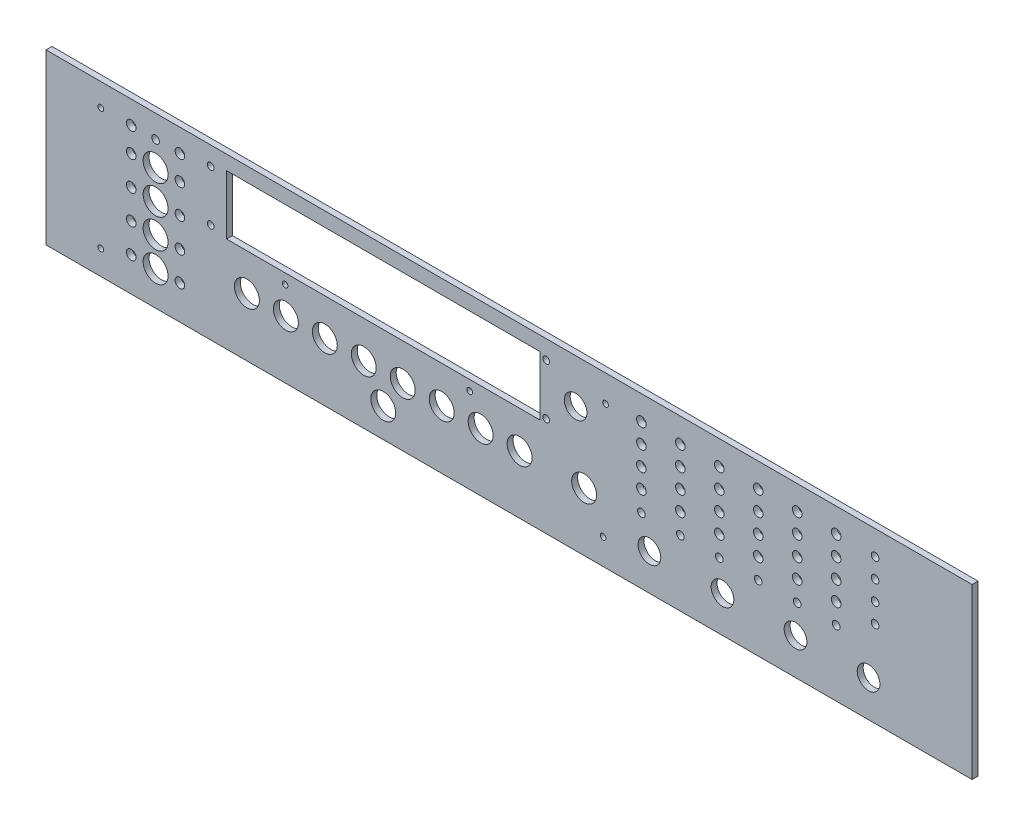
SolidWorks part; units mm, degrees
ref_plane "Front Plane" through (0, 0, 0) normal (0, 0, 1) x (1, 0, 0)
ref_plane "Top Plane" through (0, 0, 0) normal (0, 1, 0) x (1, 0, 0)
ref_plane "Right Plane" through (0, 0, 0) normal (1, 0, 0) x (0, 0, -1)
sketch "Model" plane through (0, 0, 0) normal (0, 0, 1) x (1, 0, 0)
  line L0 (482.2411, 88.0999) -> (0.759, 88.0999)
  line L1 (0, 87.3409) -> (0, 0.759)
  line L2 (0.759, 0) -> (482.2411, 0)
  line L3 (483, 0.759) -> (483, 87.3409)
  line L4 (306.5681, 59.7939) -> (306.5681, 62.0039)
  line L5 (306.5681, 62.0039) -> (306.4901, 62.0819)
  line L6 (306.4901, 62.0819) -> (306.9059, 62.0819)
  line L7 (306.9059, 62.0819) -> (307.5821, 59.9501)
  line L8 (307.5821, 59.9501) -> (307.6859, 59.9501)
  line L9 (307.6859, 59.9501) -> (308.3621, 62.0819)
  line L10 (308.3621, 62.0819) -> (308.7779, 62.0819)
  line L11 (308.7779, 62.0819) -> (308.7779, 59.768)
  line L12 (308.7779, 59.768) -> (308.7261, 59.768)
  line L13 (308.7261, 59.768) -> (308.7261, 62.0301)
  line L14 (308.7261, 62.0301) -> (308.674, 62.0301)
  line L15 (308.674, 62.0301) -> (308.674, 59.768)
  line L16 (308.674, 59.768) -> (308.6219, 59.768)
  line L17 (308.6219, 59.768) -> (308.6219, 62.0039)
  line L18 (308.6219, 62.0039) -> (308.4401, 62.0039)
  line L19 (308.4401, 62.0039) -> (307.7639, 59.7939)
  line L20 (307.7639, 59.7939) -> (307.5041, 59.7939)
  line L21 (307.5041, 59.7939) -> (306.802, 62.0039)
  line L22 (306.802, 62.0039) -> (306.6199, 62.0039)
  line L23 (306.6199, 62.0039) -> (306.6199, 59.768)
  line L24 (306.6199, 59.768) -> (306.4901, 59.768)
  line L25 (306.4901, 59.768) -> (306.4901, 62.0819)
  line L26 (306.4901, 62.0819) -> (306.386, 62.1861)
  line L27 (306.386, 62.1861) -> (306.9839, 62.1861)
  line L28 (306.9839, 62.1861) -> (307.6339, 60.132)
  line L29 (307.6339, 60.132) -> (307.6339, 59.69)
  line L30 (307.6339, 59.69) -> (307.5559, 59.8721)
  line L31 (307.5559, 59.8721) -> (307.7121, 59.8721)
  line L32 (307.7121, 59.8721) -> (307.6339, 60.132)
  line L33 (307.6339, 60.132) -> (308.2841, 62.1861)
  line L34 (308.2841, 62.1861) -> (308.882, 62.1861)
  line L35 (308.882, 62.1861) -> (308.882, 59.69)
  line L36 (308.882, 59.69) -> (308.544, 59.69)
  line L37 (308.544, 59.69) -> (308.544, 61.926)
  line L38 (308.544, 61.926) -> (307.816, 59.69)
  line L39 (307.816, 59.69) -> (307.4261, 59.69)
  line L40 (307.4261, 59.69) -> (306.724, 61.926)
  line L41 (306.724, 61.926) -> (306.724, 59.69)
  line L42 (306.724, 59.69) -> (306.386, 59.69)
  line L43 (306.386, 59.69) -> (306.386, 62.1861)
  line L44 (309.7921, 60.2361) -> (309.7921, 61.328)
  line L45 (309.7921, 61.328) -> (309.6621, 61.328)
  line L46 (309.6621, 61.328) -> (309.6621, 60.2361)
  line L47 (310.8841, 60.262) -> (310.8841, 59.7421)
  line L48 (310.8841, 59.7421) -> (311.0141, 59.7421)
  line L49 (311.0141, 59.7421) -> (311.0141, 61.3019)
  line L50 (311.0141, 61.3019) -> (310.8841, 61.3019)
  line L51 (310.8841, 61.3019) -> (310.8841, 59.7421)
  line L52 (310.8841, 59.7421) -> (310.7799, 59.69)
  line L53 (310.7799, 59.69) -> (310.7799, 60.054)
  line L54 (309.5579, 60.2879) -> (309.5579, 61.3801)
  line L55 (309.5579, 61.3801) -> (309.896, 61.3801)
  line L56 (309.896, 61.3801) -> (309.896, 60.2879)
  line L57 (310.7799, 60.2879) -> (310.7799, 61.3801)
  line L58 (310.7799, 61.3801) -> (311.118, 61.3801)
  line L59 (311.118, 61.3801) -> (311.118, 59.69)
  line L60 (311.118, 59.69) -> (310.7799, 59.69)
  line L61 (311.8721, 62.1081) -> (312.0019, 62.1081)
  line L62 (312.0019, 62.1081) -> (312.0019, 59.7421)
  line L63 (312.0019, 59.7421) -> (311.8721, 59.7421)
  line L64 (311.8721, 59.7421) -> (311.8721, 62.1081)
  line L65 (311.8721, 62.1081) -> (311.768, 62.1861)
  line L66 (311.768, 62.1861) -> (312.1061, 62.1861)
  line L67 (312.1061, 62.1861) -> (312.1061, 59.69)
  line L68 (312.1061, 59.69) -> (311.768, 59.69)
  line L69 (311.768, 59.69) -> (311.768, 62.1861)
  line L70 (313.0941, 62.1081) -> (313.2239, 62.1081)
  line L71 (313.2239, 62.1081) -> (313.2239, 60.184)
  line L72 (313.562, 59.8721) -> (313.562, 59.768)
  line L73 (313.562, 59.768) -> (313.4581, 59.768)
  line L74 (313.0941, 60.132) -> (313.0941, 62.1081)
  line L75 (313.0941, 62.1081) -> (312.99, 62.1861)
  line L76 (312.99, 62.1861) -> (313.3281, 62.1861)
  line L77 (313.3281, 62.1861) -> (313.3281, 60.184)
  line L78 (313.562, 59.9501) -> (313.6661, 59.9501)
  line L79 (313.6661, 59.9501) -> (313.6661, 59.69)
  line L80 (313.6661, 59.69) -> (313.4581, 59.69)
  line L81 (312.99, 60.1581) -> (312.99, 62.1861)
  line L82 (312.8081, 61.3019) -> (313.5879, 61.3019)
  line L83 (313.5879, 61.3019) -> (313.6661, 61.406)
  line L84 (313.6661, 61.406) -> (313.6661, 61.198)
  line L85 (313.6661, 61.198) -> (312.756, 61.198)
  line L86 (312.756, 61.198) -> (312.756, 61.406)
  line L87 (312.756, 61.406) -> (313.6661, 61.406)
  line L88 (314.55, 59.7939) -> (314.55, 59.9239)
  line L89 (314.55, 59.9239) -> (314.42, 59.9239)
  line L90 (314.42, 59.9239) -> (314.42, 59.7939)
  line L91 (314.42, 59.7939) -> (314.55, 59.7939)
  line L92 (314.55, 59.7939) -> (314.6539, 59.69)
  line L93 (314.6539, 59.69) -> (314.6539, 60.0281)
  line L94 (314.6539, 60.0281) -> (314.3161, 60.0281)
  line L95 (314.3161, 60.0281) -> (314.3161, 59.69)
  line L96 (314.3161, 59.69) -> (314.6539, 59.69)
  line L97 (59.074, 69.324) -> (59.23, 69.4799)
  line L98 (59.23, 69.4799) -> (59.23, 69.246)
  line L99 (59.23, 69.246) -> (58.6059, 69.246)
  line L100 (59.2821, 69.7141) -> (59.438, 69.7141)
  line L101 (59.438, 69.7141) -> (59.438, 67.3999)
  line L102 (59.438, 67.3999) -> (59.308, 67.3999)
  line L103 (59.308, 67.3999) -> (59.308, 69.61)
  line L104 (59.308, 69.61) -> (59.5681, 69.818)
  line L105 (59.5681, 69.818) -> (59.1779, 69.818)
  line L106 (58.528, 69.3499) -> (58.528, 69.168)
  line L107 (58.528, 69.168) -> (59.1779, 69.168)
  line L108 (59.1779, 69.168) -> (59.1779, 67.3219)
  line L109 (59.1779, 67.3219) -> (59.5681, 67.3219)
  line L110 (59.5681, 67.3219) -> (59.5681, 69.818)
  line L111 (58.308, 53.928) -> (58.438, 53.928)
  line L112 (59.4261, 53.356) -> (58.386, 52.5239)
  line L113 (58.2559, 52.1861) -> (59.894, 52.1861)
  line L114 (59.894, 52.1861) -> (59.894, 52.2641)
  line L115 (59.894, 52.2641) -> (58.386, 52.2641)
  line L116 (58.4639, 52.4721) -> (59.5559, 53.3301)
  line L117 (58.308, 53.928) -> (58.1779, 53.8241)
  line L118 (58.1779, 53.8241) -> (58.5419, 53.8241)
  line L119 (59.3481, 53.4081) -> (58.386, 52.6801)
  line L120 (58.1261, 52.0819) -> (59.9719, 52.0819)
  line L121 (59.9719, 52.0819) -> (59.9719, 52.342)
  line L122 (59.9719, 52.342) -> (58.516, 52.342)
  line L123 (58.594, 52.4459) -> (59.5559, 53.2)
  line L124 (59.373, 23.7599) -> (59.373, 21.654)
  line L125 (59.373, 21.654) -> (59.5031, 21.654)
  line L126 (59.5031, 21.654) -> (59.5031, 23.9679)
  line L127 (59.5031, 23.9679) -> (59.3209, 23.9679)
  line L128 (59.3209, 23.9679) -> (58.1769, 22.4599)
  line L129 (58.1769, 22.4599) -> (58.1769, 22.2519)
  line L130 (58.1769, 22.2519) -> (59.945, 22.2519)
  line L131 (59.945, 22.2519) -> (59.6331, 22.1219)
  line L132 (59.6331, 22.1219) -> (60.023, 22.1219)
  line L133 (60.023, 22.1219) -> (60.023, 22.382)
  line L134 (60.023, 22.382) -> (58.3329, 22.382)
  line L135 (58.3329, 22.382) -> (59.243, 23.6299)
  line L136 (59.243, 23.6299) -> (59.243, 21.6019)
  line L137 (59.243, 21.6019) -> (59.6331, 21.6019)
  line L138 (59.6331, 21.6019) -> (59.6331, 24.098)
  line L139 (59.6331, 24.098) -> (59.243, 24.098)
  line L140 (59.243, 24.098) -> (58.073, 22.5379)
  line L141 (58.073, 22.5379) -> (58.073, 22.1219)
  line L142 (58.073, 22.1219) -> (59.243, 22.1219)
  line L143 (58.2579, 37.4919) -> (58.388, 37.4919)
  line L144 (59.0639, 38.0901) -> (59.0639, 38.1681)
  line L145 (59.0639, 38.1681) -> (59.3761, 38.246)
  line L146 (58.518, 38.7401) -> (58.388, 38.7401)
  line L147 (58.388, 38.7401) -> (58.232, 38.6359)
  line L148 (58.102, 37.5961) -> (58.466, 37.5961)
  line L149 (59.0639, 37.986) -> (58.96, 37.986)
  line L150 (58.96, 37.986) -> (58.96, 38.246)
  line L151 (58.96, 38.246) -> (59.0639, 38.246)
  line L152 (58.596, 38.6359) -> (58.232, 38.6359)
  line L153 (41.3179, 76.09) -> (41.3179, 73.724)
  line L154 (41.3179, 73.724) -> (41.448, 73.724)
  line L155 (41.448, 73.724) -> (41.448, 76.09)
  line L156 (41.448, 76.09) -> (41.578, 76.168)
  line L157 (41.578, 76.168) -> (41.1879, 76.168)
  line L158 (41.1879, 76.168) -> (41.1879, 73.6719)
  line L159 (41.1879, 73.6719) -> (41.578, 73.6719)
  line L160 (41.578, 73.6719) -> (41.578, 76.168)
  line L161 (42.4881, 75.31) -> (42.4881, 73.724)
  line L162 (42.4881, 73.724) -> (42.3581, 73.724)
  line L163 (42.3581, 73.724) -> (42.3581, 75.31)
  line L164 (42.3581, 75.31) -> (42.4881, 75.31)
  line L165 (42.4881, 75.31) -> (42.592, 75.388)
  line L166 (42.592, 75.388) -> (42.592, 73.6719)
  line L167 (42.592, 73.6719) -> (42.2539, 73.6719)
  line L168 (42.2539, 73.6719) -> (42.2539, 75.388)
  line L169 (42.2539, 75.388) -> (42.592, 75.388)
  line L170 (42.592, 75.388) -> (42.592, 75.024)
  line L171 (43.814, 74.79) -> (43.814, 73.6719)
  line L172 (43.814, 73.6719) -> (43.4759, 73.6719)
  line L173 (43.4759, 73.6719) -> (43.4759, 74.79)
  line L174 (43.7101, 74.8421) -> (43.7101, 73.724)
  line L175 (43.7101, 73.724) -> (43.58, 73.724)
  line L176 (43.58, 73.724) -> (43.58, 74.8421)
  line L177 (45.53, 74.452) -> (44.9321, 74.6079)
  line L178 (45.8419, 74.9981) -> (45.738, 74.9981)
  line L179 (44.9321, 74.6859) -> (45.5821, 74.5299)
  line L180 (44.594, 74.1401) -> (44.4899, 74.1919)
  line L181 (45.6339, 74.6079) -> (44.9839, 74.7639)
  line L182 (45.6601, 74.946) -> (45.9199, 74.946)
  line L183 (44.88, 74.5299) -> (45.5041, 74.3999)
  line L184 (44.7759, 74.1919) -> (44.4899, 74.1919)
  line L185 (46.9341, 76.09) -> (47.0639, 76.09)
  line L186 (47.0639, 76.09) -> (47.0639, 74.166)
  line L187 (47.402, 73.8541) -> (47.402, 73.7499)
  line L188 (47.402, 73.7499) -> (47.2981, 73.7499)
  line L189 (46.9341, 74.1139) -> (46.9341, 76.09)
  line L190 (46.9341, 76.09) -> (46.83, 76.168)
  line L191 (46.83, 76.168) -> (47.1681, 76.168)
  line L192 (47.1681, 76.168) -> (47.1681, 74.166)
  line L193 (47.402, 73.932) -> (47.5059, 73.932)
  line L194 (47.5059, 73.932) -> (47.5059, 73.6719)
  line L195 (47.5059, 73.6719) -> (47.2981, 73.6719)
  line L196 (46.83, 74.1401) -> (46.83, 76.168)
  line L197 (46.6481, 75.2841) -> (47.4279, 75.2841)
  line L198 (47.4279, 75.2841) -> (47.5059, 75.388)
  line L199 (47.5059, 75.388) -> (47.5059, 75.1799)
  line L200 (47.5059, 75.1799) -> (46.596, 75.1799)
  line L201 (46.596, 75.1799) -> (46.596, 75.388)
  line L202 (46.596, 75.388) -> (47.5059, 75.388)
  line L203 (48.416, 75.3621) -> (48.416, 73.724)
  line L204 (48.416, 73.724) -> (48.2859, 73.724)
  line L205 (48.2859, 73.724) -> (48.2859, 75.3621)
  line L206 (48.2859, 75.3621) -> (48.416, 75.3621)
  line L207 (48.416, 75.3621) -> (48.416, 74.66)
  line L208 (48.416, 74.66) -> (48.5719, 75.024)
  line L209 (49.0921, 75.3621) -> (49.1701, 75.4659)
  line L210 (49.1701, 75.4659) -> (49.1701, 75.232)
  line L211 (48.5201, 74.66) -> (48.5201, 73.6719)
  line L212 (48.5201, 73.6719) -> (48.182, 73.6719)
  line L213 (48.182, 73.6719) -> (48.182, 75.44)
  line L214 (48.182, 75.44) -> (48.5201, 75.44)
  line L215 (48.5201, 75.44) -> (48.5201, 75.024)
  line L216 (49.04, 75.4659) -> (49.1701, 75.4659)
  line L217 (50.054, 73.7761) -> (50.054, 73.9061)
  line L218 (50.054, 73.9061) -> (49.924, 73.9061)
  line L219 (49.924, 73.9061) -> (49.924, 73.7761)
  line L220 (49.924, 73.7761) -> (50.054, 73.7761)
  line L221 (50.054, 73.7761) -> (50.1579, 73.6719)
  line L222 (50.1579, 73.6719) -> (50.1579, 74.01)
  line L223 (50.1579, 74.01) -> (49.8201, 74.01)
  line L224 (49.8201, 74.01) -> (49.8201, 73.6719)
  line L225 (49.8201, 73.6719) -> (50.1579, 73.6719)
  line L226 (69.5919, 75.7) -> (69.6961, 75.6999)
  line L227 (69.6961, 75.6999) -> (69.6699, 75.4659)
  line L228 (69.6699, 75.4659) -> (69.4879, 75.7781)
  line L229 (72.4779, 75.9859) -> (72.4779, 73.802)
  line L230 (72.4779, 73.802) -> (72.3481, 73.802)
  line L231 (72.3481, 73.802) -> (72.3481, 76.0641)
  line L232 (72.3481, 76.0641) -> (73.3099, 76.0641)
  line L233 (73.3099, 74.7121) -> (72.4779, 74.7121)
  line L234 (72.4779, 74.7121) -> (72.6079, 74.868)
  line L235 (72.6079, 74.868) -> (73.1799, 74.868)
  line L236 (73.1799, 75.9079) -> (72.6079, 75.9079)
  line L237 (72.6079, 75.9079) -> (72.6079, 74.868)
  line L238 (72.6079, 74.868) -> (72.6079, 74.79)
  line L239 (72.6079, 74.79) -> (73.3359, 74.79)
  line L240 (73.2841, 75.9859) -> (72.4779, 75.9859)
  line L241 (72.4779, 75.9859) -> (72.218, 76.168)
  line L242 (72.218, 76.168) -> (73.31, 76.168)
  line L243 (73.31, 74.6079) -> (72.6079, 74.6079)
  line L244 (72.6079, 74.6079) -> (72.6079, 73.6719)
  line L245 (72.6079, 73.6719) -> (72.218, 73.6719)
  line L246 (72.218, 73.6719) -> (72.218, 76.168)
  line L247 (303.9031, 69.7019) -> (304.735, 67.4139)
  line L248 (304.735, 67.4139) -> (304.943, 67.4139)
  line L249 (304.943, 67.4139) -> (305.7751, 69.7019)
  line L250 (305.7751, 69.7019) -> (305.6451, 69.7019)
  line L251 (305.6451, 69.7019) -> (304.9171, 67.6219)
  line L252 (304.9171, 67.6219) -> (304.7609, 67.6219)
  line L253 (304.7609, 67.6219) -> (304.007, 69.7019)
  line L254 (304.007, 69.7019) -> (303.9031, 69.7019)
  line L255 (303.9031, 69.7019) -> (303.721, 69.8061)
  line L256 (303.721, 69.8061) -> (304.6311, 67.31)
  line L257 (304.6311, 67.31) -> (305.021, 67.31)
  line L258 (305.021, 67.31) -> (305.9311, 69.8061)
  line L259 (305.9311, 69.8061) -> (305.5409, 69.8061)
  line L260 (305.5409, 69.8061) -> (304.8391, 67.8299)
  line L261 (304.8391, 67.8299) -> (304.8391, 67.31)
  line L262 (304.8391, 67.31) -> (304.8391, 67.8299)
  line L263 (304.8391, 67.8299) -> (304.1109, 69.8061)
  line L264 (304.1109, 69.8061) -> (303.721, 69.8061)
  line L265 (307.0746, 68.8182) -> (306.815, 68.5841)
  line L266 (306.815, 68.5841) -> (306.737, 68.662)
  line L267 (306.737, 68.662) -> (306.9966, 68.5321)
  line L268 (309.1289, 69.7281) -> (309.259, 69.7281)
  line L269 (309.259, 69.7281) -> (309.259, 67.3621)
  line L270 (309.259, 67.3621) -> (309.1289, 67.3621)
  line L271 (309.1289, 67.3621) -> (309.1289, 69.7281)
  line L272 (309.1289, 69.7281) -> (309.025, 69.8061)
  line L273 (309.025, 69.8061) -> (309.3631, 69.8061)
  line L274 (309.3631, 69.8061) -> (309.3631, 67.31)
  line L275 (309.3631, 67.31) -> (309.025, 67.31)
  line L276 (309.025, 67.31) -> (309.025, 69.8061)
  line L277 (310.2729, 67.8561) -> (310.2729, 68.948)
  line L278 (310.2729, 68.948) -> (310.1429, 68.948)
  line L279 (310.1429, 68.948) -> (310.1429, 67.8561)
  line L280 (311.3649, 67.882) -> (311.3649, 67.3621)
  line L281 (311.3649, 67.3621) -> (311.4949, 67.3621)
  line L282 (311.4949, 67.3621) -> (311.4949, 68.9219)
  line L283 (311.4949, 68.9219) -> (311.3649, 68.9219)
  line L284 (311.3649, 68.9219) -> (311.3649, 67.3621)
  line L285 (311.3649, 67.3621) -> (311.261, 67.31)
  line L286 (311.261, 67.31) -> (311.261, 67.674)
  line L287 (310.039, 67.9079) -> (310.039, 69.0001)
  line L288 (310.039, 69.0001) -> (310.3771, 69.0001)
  line L289 (310.3771, 69.0001) -> (310.3771, 67.9079)
  line L290 (311.261, 67.9079) -> (311.261, 69.0001)
  line L291 (311.261, 69.0001) -> (311.5991, 69.0001)
  line L292 (311.5991, 69.0001) -> (311.5991, 67.31)
  line L293 (311.5991, 67.31) -> (311.261, 67.31)
  line L294 (312.483, 69.0001) -> (312.483, 67.3621)
  line L295 (312.483, 67.3621) -> (312.3791, 67.3621)
  line L296 (312.3791, 67.3621) -> (312.3791, 69.0001)
  line L297 (312.3791, 69.0001) -> (312.483, 69.0001)
  line L298 (312.483, 69.0001) -> (312.483, 68.376)
  line L299 (312.483, 68.376) -> (312.613, 68.662)
  line L300 (313.549, 68.4281) -> (313.549, 67.3621)
  line L301 (313.549, 67.3621) -> (313.6529, 67.3621)
  line L302 (313.6529, 67.3621) -> (313.6529, 68.376)
  line L303 (314.719, 68.4281) -> (314.719, 67.3621)
  line L304 (314.719, 67.3621) -> (314.8231, 67.3621)
  line L305 (314.8231, 67.3621) -> (314.8231, 68.4281)
  line L306 (312.5869, 68.662) -> (312.5869, 69.0781)
  line L307 (312.5869, 69.0781) -> (312.275, 69.0781)
  line L308 (312.275, 69.0781) -> (312.275, 67.31)
  line L309 (312.275, 67.31) -> (312.5869, 67.31)
  line L310 (312.5869, 67.31) -> (312.5869, 68.4281)
  line L311 (313.4449, 68.4281) -> (313.4449, 67.31)
  line L312 (313.4449, 67.31) -> (313.7571, 67.31)
  line L313 (313.7571, 67.31) -> (313.7571, 68.4281)
  line L314 (314.6151, 68.4281) -> (314.6151, 67.31)
  line L315 (314.6151, 67.31) -> (314.927, 67.31)
  line L316 (314.927, 67.31) -> (314.927, 68.4281)
  line L317 (315.9671, 68.2719) -> (317.085, 68.2719)
  line L318 (316.929, 67.674) -> (317.0591, 67.674)
  line L319 (317.215, 68.1939) -> (315.915, 68.1939)
  line L320 (315.915, 68.1939) -> (315.915, 68.3499)
  line L321 (315.915, 68.3499) -> (316.9549, 68.3499)
  line L322 (316.851, 67.752) -> (317.215, 67.752)
  line L323 (317.3189, 68.1421) -> (315.915, 68.1421)
  line L324 (305.5021, 54.4881) -> (305.6059, 54.4881)
  line L325 (305.6059, 54.4881) -> (306.23, 52.356)
  line L326 (306.23, 52.356) -> (306.3339, 52.356)
  line L327 (306.3339, 52.356) -> (306.88, 54.436)
  line L328 (306.88, 54.436) -> (307.1139, 54.436)
  line L329 (307.1139, 54.436) -> (307.66, 52.356)
  line L330 (307.66, 52.356) -> (307.7901, 52.356)
  line L331 (307.7901, 52.356) -> (308.4139, 54.4881)
  line L332 (308.4139, 54.4881) -> (308.5181, 54.4881)
  line L333 (308.5181, 54.4881) -> (307.8419, 52.2)
  line L334 (307.8419, 52.2) -> (307.608, 52.2)
  line L335 (307.608, 52.2) -> (307.0621, 54.306)
  line L336 (307.0621, 54.306) -> (306.958, 54.306)
  line L337 (306.958, 54.306) -> (306.4119, 52.2)
  line L338 (306.4119, 52.2) -> (306.1779, 52.2)
  line L339 (306.1779, 52.2) -> (305.5021, 54.4881)
  line L340 (305.5021, 54.4881) -> (305.372, 54.5661)
  line L341 (305.372, 54.5661) -> (305.7101, 54.5661)
  line L342 (305.7101, 54.5661) -> (306.2821, 52.512)
  line L343 (306.2821, 52.512) -> (306.802, 54.5661)
  line L344 (306.802, 54.5661) -> (307.1919, 54.5661)
  line L345 (307.1919, 54.5661) -> (307.7121, 52.512)
  line L346 (307.7121, 52.512) -> (308.31, 54.5661)
  line L347 (308.31, 54.5661) -> (308.6481, 54.5661)
  line L348 (308.6481, 54.5661) -> (307.9199, 52.07)
  line L349 (307.9199, 52.07) -> (307.53, 52.07)
  line L350 (307.53, 52.07) -> (307.0101, 54.0979)
  line L351 (307.0101, 54.0979) -> (306.4901, 52.07)
  line L352 (306.4901, 52.07) -> (306.1, 52.07)
  line L353 (306.1, 52.07) -> (305.372, 54.5661)
  line L354 (310.7799, 53.37) -> (310.7799, 52.2)
  line L355 (310.7799, 52.2) -> (310.832, 52.0959)
  line L356 (310.832, 52.0959) -> (310.7019, 52.3819)
  line L357 (310.7019, 52.3819) -> (310.7019, 52.1221)
  line L358 (310.7019, 52.1221) -> (310.5981, 52.3039)
  line L359 (310.5981, 52.3039) -> (310.7019, 52.5381)
  line L360 (310.676, 53.2661) -> (310.546, 53.084)
  line L361 (310.546, 53.084) -> (310.546, 52.6941)
  line L362 (310.546, 53.084) -> (310.676, 53.3441)
  line L363 (310.676, 53.3441) -> (310.676, 52.72)
  line L364 (309.6621, 53.422) -> (309.532, 53.422)
  line L365 (309.532, 53.422) -> (309.4279, 53.3441)
  line L366 (309.4279, 53.3441) -> (309.766, 53.3441)
  line L367 (310.3641, 53.136) -> (309.8439, 53.0319)
  line L368 (310.5981, 52.07) -> (310.9879, 52.07)
  line L369 (310.91, 52.1739) -> (310.91, 53.292)
  line L370 (311.9239, 53.734) -> (312.418, 52.278)
  line L371 (312.418, 52.278) -> (312.5221, 52.278)
  line L372 (312.5221, 52.278) -> (313.0159, 53.734)
  line L373 (313.0159, 53.734) -> (313.1459, 53.734)
  line L374 (313.1459, 53.734) -> (312.6001, 52.148)
  line L375 (312.6001, 52.148) -> (312.34, 52.148)
  line L376 (312.34, 52.148) -> (311.7939, 53.734)
  line L377 (311.7939, 53.734) -> (311.9239, 53.734)
  line L378 (311.9239, 53.734) -> (312.0019, 53.8119)
  line L379 (312.0019, 53.8119) -> (312.47, 52.3819)
  line L380 (312.47, 52.3819) -> (312.9379, 53.8119)
  line L381 (312.9379, 53.8119) -> (313.276, 53.8119)
  line L382 (313.276, 53.8119) -> (312.6781, 52.07)
  line L383 (312.6781, 52.07) -> (312.262, 52.07)
  line L384 (312.262, 52.07) -> (311.6641, 53.8119)
  line L385 (311.6641, 53.8119) -> (312.0019, 53.8119)
  line L386 (314.3161, 53.0319) -> (315.434, 53.0319)
  line L387 (315.278, 52.434) -> (315.4081, 52.434)
  line L388 (315.564, 52.9539) -> (314.264, 52.9539)
  line L389 (314.264, 52.9539) -> (314.264, 53.1099)
  line L390 (314.264, 53.1099) -> (315.3039, 53.1099)
  line L391 (315.2, 52.512) -> (315.564, 52.512)
  line L392 (315.6679, 52.9021) -> (314.264, 52.9021)
  line L393 (306.165, 46.8681) -> (306.165, 44.5021)
  line L394 (306.165, 44.5021) -> (306.295, 44.5021)
  line L395 (306.295, 44.5021) -> (306.295, 46.8681)
  line L396 (306.295, 46.8681) -> (306.4251, 46.9461)
  line L397 (306.4251, 46.9461) -> (306.0349, 46.9461)
  line L398 (306.0349, 46.9461) -> (306.0349, 44.45)
  line L399 (306.0349, 44.45) -> (306.4251, 44.45)
  line L400 (306.4251, 44.45) -> (306.4251, 46.9461)
  line L401 (307.3349, 46.088) -> (307.3349, 44.5021)
  line L402 (307.3349, 44.5021) -> (307.2051, 44.5021)
  line L403 (307.2051, 44.5021) -> (307.2051, 46.088)
  line L404 (307.2051, 46.088) -> (307.3349, 46.088)
  line L405 (307.3349, 46.088) -> (307.4391, 46.166)
  line L406 (307.4391, 46.166) -> (307.4391, 44.45)
  line L407 (307.4391, 44.45) -> (307.101, 44.45)
  line L408 (307.101, 44.45) -> (307.101, 46.166)
  line L409 (307.101, 46.166) -> (307.4391, 46.166)
  line L410 (307.4391, 46.166) -> (307.4391, 45.802)
  line L411 (308.6611, 45.5681) -> (308.6611, 44.45)
  line L412 (308.6611, 44.45) -> (308.323, 44.45)
  line L413 (308.323, 44.45) -> (308.323, 45.5681)
  line L414 (308.5569, 45.6199) -> (308.5569, 44.5021)
  line L415 (308.5569, 44.5021) -> (308.4271, 44.5021)
  line L416 (308.4271, 44.5021) -> (308.4271, 45.6199)
  line L417 (310.3771, 45.23) -> (309.7789, 45.386)
  line L418 (310.689, 45.7759) -> (310.5851, 45.7759)
  line L419 (309.7789, 45.464) -> (310.4289, 45.308)
  line L420 (309.4411, 44.9181) -> (309.3369, 44.9699)
  line L421 (310.481, 45.386) -> (309.831, 45.5419)
  line L422 (310.5071, 45.7241) -> (310.767, 45.7241)
  line L423 (309.7271, 45.308) -> (310.3509, 45.178)
  line L424 (309.623, 44.9699) -> (309.3369, 44.9699)
  line L425 (311.7809, 46.8681) -> (311.911, 46.8681)
  line L426 (311.911, 46.8681) -> (311.911, 44.944)
  line L427 (312.2491, 44.6321) -> (312.2491, 44.528)
  line L428 (312.2491, 44.528) -> (312.1449, 44.528)
  line L429 (311.7809, 44.892) -> (311.7809, 46.8681)
  line L430 (311.7809, 46.8681) -> (311.677, 46.9461)
  line L431 (311.677, 46.9461) -> (312.0151, 46.9461)
  line L432 (312.0151, 46.9461) -> (312.0151, 44.944)
  line L433 (312.2491, 44.7101) -> (312.3529, 44.7101)
  line L434 (312.3529, 44.7101) -> (312.3529, 44.45)
  line L435 (312.3529, 44.45) -> (312.1449, 44.45)
  line L436 (311.677, 44.9181) -> (311.677, 46.9461)
  line L437 (311.4949, 46.0619) -> (312.275, 46.0619)
  line L438 (312.275, 46.0619) -> (312.3529, 46.166)
  line L439 (312.3529, 46.166) -> (312.3529, 45.958)
  line L440 (312.3529, 45.958) -> (311.4431, 45.958)
  line L441 (311.4431, 45.958) -> (311.4431, 46.166)
  line L442 (311.4431, 46.166) -> (312.3529, 46.166)
  line L443 (313.263, 46.1401) -> (313.263, 44.5021)
  line L444 (313.263, 44.5021) -> (313.133, 44.5021)
  line L445 (313.133, 44.5021) -> (313.133, 46.1401)
  line L446 (313.133, 46.1401) -> (313.263, 46.1401)
  line L447 (313.263, 46.1401) -> (313.263, 45.4381)
  line L448 (313.263, 45.4381) -> (313.419, 45.802)
  line L449 (313.9389, 46.1401) -> (314.0169, 46.244)
  line L450 (314.0169, 46.244) -> (314.0169, 46.0101)
  line L451 (313.3669, 45.4381) -> (313.3669, 44.45)
  line L452 (313.3669, 44.45) -> (313.0291, 44.45)
  line L453 (313.0291, 44.45) -> (313.0291, 46.2181)
  line L454 (313.0291, 46.2181) -> (313.3669, 46.2181)
  line L455 (313.3669, 46.2181) -> (313.3669, 45.802)
  line L456 (313.8871, 46.244) -> (314.0169, 46.244)
  line L457 (314.9011, 44.5539) -> (314.9011, 44.6839)
  line L458 (314.9011, 44.6839) -> (314.771, 44.6839)
  line L459 (314.771, 44.6839) -> (314.771, 44.5539)
  line L460 (314.771, 44.5539) -> (314.9011, 44.5539)
  line L461 (314.9011, 44.5539) -> (315.005, 44.45)
  line L462 (315.005, 44.45) -> (315.005, 44.7881)
  line L463 (315.005, 44.7881) -> (314.6669, 44.7881)
  line L464 (314.6669, 44.7881) -> (314.6669, 44.45)
  line L465 (314.6669, 44.45) -> (315.005, 44.45)
  line L466 (325.8091, 69.754) -> (326.6671, 67.388)
  line L467 (326.6671, 67.388) -> (326.7969, 67.388)
  line L468 (326.7969, 67.388) -> (325.913, 69.754)
  line L469 (325.913, 69.754) -> (325.8091, 69.754)
  line L470 (325.8091, 69.754) -> (324.9249, 67.388)
  line L471 (324.9249, 67.388) -> (324.7949, 67.388)
  line L472 (324.7949, 67.388) -> (325.6791, 69.754)
  line L473 (325.6791, 69.754) -> (326.563, 67.31)
  line L474 (326.563, 67.31) -> (326.9531, 67.31)
  line L475 (326.9531, 67.31) -> (326.0169, 69.8061)
  line L476 (326.0169, 69.8061) -> (325.5749, 69.8061)
  line L477 (325.5749, 69.8061) -> (324.6389, 67.31)
  line L478 (324.6389, 67.31) -> (325.0291, 67.31)
  line L479 (325.0291, 67.31) -> (325.7829, 69.39)
  line L480 (325.7829, 69.39) -> (325.3151, 68.1421)
  line L481 (325.3151, 68.1421) -> (326.277, 68.1421)
  line L482 (326.277, 68.1421) -> (326.3029, 68.0641)
  line L483 (326.3029, 68.0641) -> (325.263, 68.0641)
  line L484 (325.263, 68.0641) -> (325.2371, 67.96)
  line L485 (325.2371, 67.96) -> (326.3549, 67.96)
  line L486 (326.3549, 67.96) -> (326.3549, 67.882)
  line L487 (326.3549, 67.882) -> (325.2371, 67.882)
  line L488 (327.9409, 69.7281) -> (328.071, 69.7281)
  line L489 (328.071, 69.7281) -> (328.071, 67.804)
  line L490 (328.409, 67.4921) -> (328.409, 67.388)
  line L491 (328.409, 67.388) -> (328.3049, 67.388)
  line L492 (327.9409, 67.752) -> (327.9409, 69.7281)
  line L493 (327.9409, 69.7281) -> (327.837, 69.8061)
  line L494 (327.837, 69.8061) -> (328.1751, 69.8061)
  line L495 (328.1751, 69.8061) -> (328.1751, 67.804)
  line L496 (328.409, 67.5701) -> (328.5129, 67.5701)
  line L497 (328.5129, 67.5701) -> (328.5129, 67.31)
  line L498 (328.5129, 67.31) -> (328.3049, 67.31)
  line L499 (327.837, 67.7781) -> (327.837, 69.8061)
  line L500 (327.6549, 68.9219) -> (328.435, 68.9219)
  line L501 (328.435, 68.9219) -> (328.5129, 69.026)
  line L502 (328.5129, 69.026) -> (328.5129, 68.818)
  line L503 (328.5129, 68.818) -> (327.6031, 68.818)
  line L504 (327.6031, 68.818) -> (327.6031, 69.026)
  line L505 (327.6031, 69.026) -> (328.5129, 69.026)
  line L506 (329.501, 69.7281) -> (329.631, 69.7281)
  line L507 (329.631, 69.7281) -> (329.631, 67.804)
  line L508 (329.9691, 67.4921) -> (329.9691, 67.388)
  line L509 (329.9691, 67.388) -> (329.865, 67.388)
  line L510 (329.501, 67.752) -> (329.501, 69.7281)
  line L511 (329.501, 69.7281) -> (329.3971, 69.8061)
  line L512 (329.3971, 69.8061) -> (329.7349, 69.8061)
  line L513 (329.7349, 69.8061) -> (329.7349, 67.804)
  line L514 (329.9691, 67.5701) -> (330.073, 67.5701)
  line L515 (330.073, 67.5701) -> (330.073, 67.31)
  line L516 (330.073, 67.31) -> (329.865, 67.31)
  line L517 (329.3971, 67.7781) -> (329.3971, 69.8061)
  line L518 (329.215, 68.9219) -> (329.995, 68.9219)
  line L519 (329.995, 68.9219) -> (330.073, 69.026)
  line L520 (330.073, 69.026) -> (330.073, 68.818)
  line L521 (330.073, 68.818) -> (329.1629, 68.818)
  line L522 (329.1629, 68.818) -> (329.1629, 69.026)
  line L523 (329.1629, 69.026) -> (330.073, 69.026)
  line L524 (332.2051, 68.61) -> (332.2051, 67.44)
  line L525 (332.2051, 67.44) -> (332.2569, 67.3359)
  line L526 (332.2569, 67.3359) -> (332.1271, 67.6219)
  line L527 (332.1271, 67.6219) -> (332.1271, 67.3621)
  line L528 (332.1271, 67.3621) -> (332.023, 67.5439)
  line L529 (332.023, 67.5439) -> (332.1271, 67.7781)
  line L530 (332.1009, 68.5061) -> (331.9709, 68.324)
  line L531 (331.9709, 68.324) -> (331.9709, 67.9341)
  line L532 (331.9709, 68.324) -> (332.1009, 68.5841)
  line L533 (332.1009, 68.5841) -> (332.1009, 67.96)
  line L534 (331.087, 68.662) -> (330.9569, 68.662)
  line L535 (330.9569, 68.662) -> (330.853, 68.5841)
  line L536 (330.853, 68.5841) -> (331.1911, 68.5841)
  line L537 (331.789, 68.376) -> (331.2691, 68.2719)
  line L538 (332.023, 67.31) -> (332.4131, 67.31)
  line L539 (332.3351, 67.4139) -> (332.3351, 68.532)
  line L540 (334.6229, 68.61) -> (334.4931, 68.61)
  line L541 (334.4931, 67.804) -> (334.6229, 67.8041)
  line L542 (334.6229, 68.61) -> (334.7529, 68.5579)
  line L543 (334.7529, 68.5579) -> (334.389, 68.5579)
  line L544 (334.4149, 67.8561) -> (334.7529, 67.8561)
  line L545 (335.5071, 67.3621) -> (335.6371, 67.3621)
  line L546 (335.6371, 67.3621) -> (335.6371, 69.7281)
  line L547 (335.6371, 69.7281) -> (335.5071, 69.7281)
  line L548 (335.5071, 69.7281) -> (335.5071, 67.3621)
  line L549 (335.5071, 67.3621) -> (335.4029, 67.31)
  line L550 (335.4029, 67.31) -> (335.741, 67.31)
  line L551 (335.741, 67.31) -> (335.741, 67.9859)
  line L552 (335.741, 67.9859) -> (336.105, 68.3499)
  line L553 (336.105, 68.3499) -> (336.7291, 67.388)
  line L554 (336.7291, 67.388) -> (336.8591, 67.388)
  line L555 (336.8591, 67.388) -> (336.2089, 68.4281)
  line L556 (336.2089, 68.4281) -> (336.7809, 69.0001)
  line L557 (336.7809, 69.0001) -> (336.6511, 69.0001)
  line L558 (336.6511, 69.0001) -> (335.741, 68.1159)
  line L559 (335.741, 68.1159) -> (335.741, 68.2201)
  line L560 (335.741, 68.2201) -> (336.599, 69.0781)
  line L561 (336.599, 69.0781) -> (336.9889, 69.0781)
  line L562 (336.9889, 69.0781) -> (336.3389, 68.4281)
  line L563 (336.3389, 68.4281) -> (337.041, 67.31)
  line L564 (337.041, 67.31) -> (336.6511, 67.31)
  line L565 (336.6511, 67.31) -> (336.105, 68.1939)
  line L566 (336.105, 68.1939) -> (335.741, 67.8299)
  line L567 (335.741, 67.8299) -> (335.741, 69.8061)
  line L568 (335.741, 69.8061) -> (335.4029, 69.8061)
  line L569 (335.4029, 69.8061) -> (335.4029, 67.31)
  line L570 (325.419, 62.0039) -> (325.419, 59.8721)
  line L571 (325.419, 59.8721) -> (326.0689, 59.8721)
  line L572 (326.0951, 62.0039) -> (325.419, 62.0039)
  line L573 (325.419, 62.0039) -> (325.2889, 62.0819)
  line L574 (325.2889, 62.0819) -> (326.0689, 62.0819)
  line L575 (326.0689, 59.7939) -> (325.2889, 59.7939)
  line L576 (325.2889, 59.7939) -> (325.2889, 62.0819)
  line L577 (325.2889, 62.0819) -> (325.1591, 62.1861)
  line L578 (325.1591, 62.1861) -> (326.0689, 62.1861)
  line L579 (326.0689, 59.69) -> (325.1591, 59.69)
  line L580 (325.1591, 59.69) -> (325.1591, 62.1861)
  line L581 (325.1591, 62.1861) -> (325.549, 61.926)
  line L582 (325.549, 61.926) -> (326.0689, 61.926)
  line L583 (326.0689, 59.9501) -> (325.549, 59.9501)
  line L584 (325.549, 59.9501) -> (325.549, 61.926)
  line L585 (328.201, 60.6519) -> (329.3189, 60.6519)
  line L586 (329.1629, 60.054) -> (329.293, 60.054)
  line L587 (329.4489, 60.5739) -> (328.149, 60.5739)
  line L588 (328.149, 60.5739) -> (328.149, 60.7299)
  line L589 (328.149, 60.7299) -> (329.1891, 60.7299)
  line L590 (329.0849, 60.132) -> (329.4489, 60.132)
  line L591 (329.5531, 60.5221) -> (328.149, 60.5221)
  line L592 (331.7631, 60.99) -> (331.6331, 60.99)
  line L593 (331.6331, 60.184) -> (331.7631, 60.1841)
  line L594 (331.7631, 60.99) -> (331.8929, 60.9379)
  line L595 (331.8929, 60.9379) -> (331.5289, 60.9379)
  line L596 (331.5551, 60.2361) -> (331.8929, 60.2361)
  line L597 (334.025, 60.99) -> (334.025, 59.82)
  line L598 (334.025, 59.82) -> (334.0771, 59.7159)
  line L599 (334.0771, 59.7159) -> (333.947, 60.0019)
  line L600 (333.947, 60.0019) -> (333.947, 59.7421)
  line L601 (333.947, 59.7421) -> (333.8431, 59.9239)
  line L602 (333.8431, 59.9239) -> (333.947, 60.1581)
  line L603 (333.9211, 60.8861) -> (333.7911, 60.704)
  line L604 (333.7911, 60.704) -> (333.7911, 60.3141)
  line L605 (333.7911, 60.704) -> (333.9211, 60.9641)
  line L606 (333.9211, 60.9641) -> (333.9211, 60.34)
  line L607 (332.9069, 61.042) -> (332.7771, 61.042)
  line L608 (332.7771, 61.042) -> (332.6729, 60.9641)
  line L609 (332.6729, 60.9641) -> (333.011, 60.9641)
  line L610 (333.6089, 60.756) -> (333.089, 60.6519)
  line L611 (333.8431, 59.69) -> (334.233, 59.69)
  line L612 (334.155, 59.7939) -> (334.155, 60.912)
  line L613 (335.169, 61.3801) -> (335.7151, 59.768)
  line L614 (335.7151, 59.768) -> (336.2609, 61.3801)
  line L615 (336.2609, 61.3801) -> (336.391, 61.3801)
  line L616 (336.391, 61.3801) -> (335.6889, 59.4299)
  line L617 (335.3511, 59.196) -> (335.169, 59.196)
  line L618 (335.169, 59.196) -> (335.169, 59.3001)
  line L619 (335.169, 59.3001) -> (335.299, 59.3001)
  line L620 (335.611, 59.7421) -> (335.039, 61.3801)
  line L621 (335.039, 61.3801) -> (335.169, 61.3801)
  line L622 (335.169, 61.3801) -> (335.247, 61.4581)
  line L623 (335.247, 61.4581) -> (335.7151, 60.0281)
  line L624 (335.7151, 60.0281) -> (336.183, 61.4581)
  line L625 (336.183, 61.4581) -> (336.521, 61.4581)
  line L626 (336.521, 61.4581) -> (335.819, 59.4299)
  line L627 (335.377, 59.118) -> (335.0651, 59.118)
  line L628 (335.0651, 59.118) -> (335.0651, 59.3781)
  line L629 (335.0651, 59.3781) -> (335.2729, 59.3781)
  line L630 (335.5071, 59.7159) -> (334.9089, 61.4581)
  line L631 (334.9089, 61.4581) -> (335.247, 61.4581)
  line L632 (324.678, 53.5) -> (325.5881, 53.292)
  line L633 (324.184, 52.72) -> (324.3141, 52.72)
  line L634 (325.5361, 53.1881) -> (324.6519, 53.3959)
  line L635 (325.9521, 53.9679) -> (326.0819, 53.8899)
  line L636 (324.6001, 53.292) -> (325.484, 53.084)
  line L637 (324.4441, 52.798) -> (324.054, 52.798)
  line L638 (325.6661, 53.3959) -> (324.7301, 53.6301)
  line L639 (325.7179, 53.8899) -> (326.0819, 53.8899)
  line L640 (327.044, 52.6161) -> (327.044, 53.708)
  line L641 (327.044, 53.708) -> (326.914, 53.708)
  line L642 (326.914, 53.708) -> (326.914, 52.6161)
  line L643 (328.136, 52.642) -> (328.136, 52.1221)
  line L644 (328.136, 52.1221) -> (328.266, 52.1221)
  line L645 (328.266, 52.1221) -> (328.266, 53.6819)
  line L646 (328.266, 53.6819) -> (328.136, 53.6819)
  line L647 (328.136, 53.6819) -> (328.136, 52.1221)
  line L648 (328.136, 52.1221) -> (328.0321, 52.07)
  line L649 (328.0321, 52.07) -> (328.0321, 52.434)
  line L650 (326.8101, 52.6679) -> (326.8101, 53.7601)
  line L651 (326.8101, 53.7601) -> (327.1479, 53.7601)
  line L652 (327.1479, 53.7601) -> (327.1479, 52.6679)
  line L653 (328.0321, 52.6679) -> (328.0321, 53.7601)
  line L654 (328.0321, 53.7601) -> (328.3699, 53.7601)
  line L655 (328.3699, 53.7601) -> (328.3699, 52.07)
  line L656 (328.3699, 52.07) -> (328.0321, 52.07)
  line L657 (330.086, 52.85) -> (329.488, 53.006)
  line L658 (330.3981, 53.3959) -> (330.294, 53.3959)
  line L659 (329.488, 53.084) -> (330.138, 52.928)
  line L660 (329.15, 52.5381) -> (329.0461, 52.5899)
  line L661 (330.1901, 53.006) -> (329.5401, 53.1619)
  line L662 (330.216, 53.3441) -> (330.4761, 53.3441)
  line L663 (329.436, 52.928) -> (330.06, 52.798)
  line L664 (329.3321, 52.5899) -> (329.0461, 52.5899)
  line L665 (331.4901, 54.4881) -> (331.6201, 54.4881)
  line L666 (331.6201, 54.4881) -> (331.6201, 52.564)
  line L667 (331.9579, 52.2521) -> (331.9579, 52.148)
  line L668 (331.9579, 52.148) -> (331.854, 52.148)
  line L669 (331.4901, 52.512) -> (331.4901, 54.4881)
  line L670 (331.4901, 54.4881) -> (331.3859, 54.5661)
  line L671 (331.3859, 54.5661) -> (331.724, 54.5661)
  line L672 (331.724, 54.5661) -> (331.724, 52.564)
  line L673 (331.9579, 52.3301) -> (332.0621, 52.3301)
  line L674 (332.0621, 52.3301) -> (332.0621, 52.07)
  line L675 (332.0621, 52.07) -> (331.854, 52.07)
  line L676 (331.3859, 52.5381) -> (331.3859, 54.5661)
  line L677 (331.2041, 53.6819) -> (331.9841, 53.6819)
  line L678 (331.9841, 53.6819) -> (332.0621, 53.786)
  line L679 (332.0621, 53.786) -> (332.0621, 53.578)
  line L680 (332.0621, 53.578) -> (331.152, 53.578)
  line L681 (331.152, 53.578) -> (331.152, 53.786)
  line L682 (331.152, 53.786) -> (332.0621, 53.786)
  line L683 (334.1939, 53.37) -> (334.1939, 52.2)
  line L684 (334.1939, 52.2) -> (334.246, 52.0959)
  line L685 (334.246, 52.0959) -> (334.1159, 52.3819)
  line L686 (334.1159, 52.3819) -> (334.1159, 52.1221)
  line L687 (334.1159, 52.1221) -> (334.012, 52.3039)
  line L688 (334.012, 52.3039) -> (334.1159, 52.5381)
  line L689 (334.09, 53.2661) -> (333.96, 53.084)
  line L690 (333.96, 53.084) -> (333.96, 52.6941)
  line L691 (333.96, 53.084) -> (334.09, 53.3441)
  line L692 (334.09, 53.3441) -> (334.09, 52.72)
  line L693 (333.076, 53.422) -> (332.946, 53.422)
  line L694 (332.946, 53.422) -> (332.8421, 53.3441)
  line L695 (332.8421, 53.3441) -> (333.1799, 53.3441)
  line L696 (333.7781, 53.136) -> (333.2579, 53.0319)
  line L697 (334.012, 52.07) -> (334.4019, 52.07)
  line L698 (334.3239, 52.1739) -> (334.3239, 53.292)
  line L699 (335.156, 54.3321) -> (335.2861, 54.3321)
  line L700 (335.2861, 54.3321) -> (335.2861, 54.4619)
  line L701 (335.2861, 54.4619) -> (335.156, 54.4619)
  line L702 (335.156, 54.4619) -> (335.156, 54.3321)
  line L703 (335.156, 54.3321) -> (335.0519, 54.228)
  line L704 (335.0519, 54.228) -> (335.39, 54.228)
  line L705 (335.39, 54.228) -> (335.39, 54.5661)
  line L706 (335.39, 54.5661) -> (335.0519, 54.5661)
  line L707 (335.0519, 54.5661) -> (335.0519, 54.228)
  line L708 (335.2861, 53.7601) -> (335.2861, 52.1221)
  line L709 (335.2861, 52.1221) -> (335.156, 52.1221)
  line L710 (335.156, 52.1221) -> (335.156, 53.7601)
  line L711 (335.156, 53.7601) -> (335.2861, 53.7601)
  line L712 (335.2861, 53.7601) -> (335.39, 53.8381)
  line L713 (335.39, 53.8381) -> (335.39, 52.07)
  line L714 (335.39, 52.07) -> (335.0519, 52.07)
  line L715 (335.0519, 52.07) -> (335.0519, 53.8381)
  line L716 (335.0519, 53.8381) -> (335.39, 53.8381)
  line L717 (336.3001, 53.708) -> (336.3001, 52.1221)
  line L718 (336.3001, 52.1221) -> (336.17, 52.1221)
  line L719 (336.17, 52.1221) -> (336.17, 53.708)
  line L720 (336.17, 53.708) -> (336.3001, 53.708)
  line L721 (336.3001, 53.708) -> (336.4039, 53.786)
  line L722 (336.4039, 53.786) -> (336.4039, 52.07)
  line L723 (336.4039, 52.07) -> (336.0659, 52.07)
  line L724 (336.0659, 52.07) -> (336.0659, 53.786)
  line L725 (336.0659, 53.786) -> (336.4039, 53.786)
  line L726 (336.4039, 53.786) -> (336.4039, 53.422)
  line L727 (337.6259, 53.1881) -> (337.6259, 52.07)
  line L728 (337.6259, 52.07) -> (337.2881, 52.07)
  line L729 (337.2881, 52.07) -> (337.2881, 53.1881)
  line L730 (337.5221, 53.2399) -> (337.5221, 52.1221)
  line L731 (337.5221, 52.1221) -> (337.392, 52.1221)
  line L732 (337.392, 52.1221) -> (337.392, 53.2399)
  line L733 (325.0809, 44.45) -> (325.133, 44.528)
  line L734 (325.133, 44.9961) -> (325.2109, 44.5021)
  line L735 (325.2109, 44.5021) -> (325.2889, 44.4759)
  line L736 (324.613, 45.594) -> (323.9889, 45.594)
  line L737 (323.9889, 45.594) -> (323.9889, 45.6979)
  line L738 (323.9889, 45.6979) -> (324.613, 45.6979)
  line L739 (324.7949, 46.8419) -> (323.7291, 46.8419)
  line L740 (323.7291, 46.8419) -> (323.7291, 44.5021)
  line L741 (323.7291, 44.5021) -> (323.8589, 44.5021)
  line L742 (323.8589, 44.5021) -> (323.8589, 46.7639)
  line L743 (323.8589, 46.7639) -> (324.7949, 46.7639)
  line L744 (324.8731, 45.75) -> (324.6389, 45.7759)
  line L745 (324.6389, 45.7759) -> (323.9889, 45.7759)
  line L746 (323.9889, 45.7759) -> (323.9889, 46.686)
  line L747 (323.9889, 46.686) -> (324.6389, 46.686)
  line L748 (324.6389, 45.7759) -> (324.743, 45.6459)
  line L749 (324.8469, 46.9461) -> (323.599, 46.9461)
  line L750 (323.599, 46.9461) -> (323.599, 44.45)
  line L751 (323.599, 44.45) -> (323.9889, 44.45)
  line L752 (323.9889, 44.45) -> (323.9889, 45.516)
  line L753 (323.9889, 45.516) -> (324.4571, 45.516)
  line L754 (325.0809, 44.45) -> (325.4451, 44.45)
  line L755 (325.341, 44.6839) -> (325.3151, 45.0479)
  line L756 (326.485, 45.4119) -> (327.6031, 45.4119)
  line L757 (327.4469, 44.814) -> (327.5769, 44.814)
  line L758 (327.7329, 45.3339) -> (326.4329, 45.3339)
  line L759 (326.4329, 45.3339) -> (326.4329, 45.4899)
  line L760 (326.4329, 45.4899) -> (327.4731, 45.4899)
  line L761 (327.3689, 44.892) -> (327.7329, 44.892)
  line L762 (327.837, 45.2821) -> (326.4329, 45.2821)
  line L763 (328.5909, 46.8681) -> (328.721, 46.8681)
  line L764 (328.721, 46.8681) -> (328.721, 44.5021)
  line L765 (328.721, 44.5021) -> (328.5909, 44.5021)
  line L766 (328.5909, 44.5021) -> (328.5909, 46.8681)
  line L767 (328.5909, 46.8681) -> (328.487, 46.9461)
  line L768 (328.487, 46.9461) -> (328.8251, 46.9461)
  line L769 (328.8251, 46.9461) -> (328.8251, 44.45)
  line L770 (328.8251, 44.45) -> (328.487, 44.45)
  line L771 (328.487, 44.45) -> (328.487, 46.9461)
  line L772 (329.865, 45.4119) -> (330.9831, 45.4119)
  line L773 (330.8271, 44.814) -> (330.9569, 44.814)
  line L774 (331.1129, 45.3339) -> (329.8129, 45.3339)
  line L775 (329.8129, 45.3339) -> (329.8129, 45.4899)
  line L776 (329.8129, 45.4899) -> (330.853, 45.4899)
  line L777 (330.7489, 44.892) -> (331.1129, 44.892)
  line L778 (331.217, 45.2821) -> (329.8129, 45.2821)
  line L779 (333.3491, 45.75) -> (333.3491, 44.58)
  line L780 (333.3491, 44.58) -> (333.4009, 44.4759)
  line L781 (333.4009, 44.4759) -> (333.2711, 44.7619)
  line L782 (333.2711, 44.7619) -> (333.2711, 44.5021)
  line L783 (333.2711, 44.5021) -> (333.167, 44.6839)
  line L784 (333.167, 44.6839) -> (333.2711, 44.9181)
  line L785 (333.245, 45.6461) -> (333.1149, 45.464)
  line L786 (333.1149, 45.464) -> (333.1149, 45.0741)
  line L787 (333.1149, 45.464) -> (333.245, 45.7241)
  line L788 (333.245, 45.7241) -> (333.245, 45.1)
  line L789 (332.231, 45.802) -> (332.1009, 45.802)
  line L790 (332.1009, 45.802) -> (331.9971, 45.7241)
  line L791 (331.9971, 45.7241) -> (332.3351, 45.7241)
  line L792 (332.933, 45.516) -> (332.4131, 45.4119)
  line L793 (333.167, 44.45) -> (333.5571, 44.45)
  line L794 (333.4789, 44.5539) -> (333.4789, 45.672)
  line L795 (335.2729, 45.23) -> (334.675, 45.386)
  line L796 (335.5851, 45.7759) -> (335.4809, 45.7759)
  line L797 (334.675, 45.464) -> (335.325, 45.308)
  line L798 (334.3369, 44.9181) -> (334.233, 44.9699)
  line L799 (335.377, 45.386) -> (334.727, 45.5419)
  line L800 (335.4029, 45.7241) -> (335.663, 45.7241)
  line L801 (334.6229, 45.308) -> (335.247, 45.178)
  line L802 (334.519, 44.9699) -> (334.233, 44.9699)
  line L803 (336.7291, 45.4119) -> (337.8469, 45.4119)
  line L804 (337.691, 44.814) -> (337.821, 44.814)
  line L805 (337.977, 45.3339) -> (336.677, 45.3339)
  line L806 (336.677, 45.3339) -> (336.677, 45.4899)
  line L807 (336.677, 45.4899) -> (337.7169, 45.4899)
  line L808 (337.613, 44.892) -> (337.977, 44.892)
  line L809 (338.0811, 45.2821) -> (336.677, 45.2821)
  line L810 (348.3389, 67.44) -> (346.8571, 67.44)
  line L811 (346.8571, 67.44) -> (346.8571, 69.7281)
  line L812 (346.8571, 69.7281) -> (346.9871, 69.7281)
  line L813 (346.9871, 69.7281) -> (346.9871, 67.5701)
  line L814 (346.9871, 67.5701) -> (348.4169, 67.5701)
  line L815 (348.4169, 67.5701) -> (348.4169, 67.31)
  line L816 (348.4169, 67.31) -> (346.727, 67.31)
  line L817 (346.727, 67.31) -> (346.727, 69.8061)
  line L818 (346.727, 69.8061) -> (347.1169, 69.8061)
  line L819 (347.1169, 69.8061) -> (347.1169, 67.5701)
  line L820 (349.2231, 69.7281) -> (350.8091, 69.7281)
  line L821 (350.8091, 69.7281) -> (350.8091, 69.6239)
  line L822 (350.8091, 69.6239) -> (349.3531, 69.6239)
  line L823 (349.3531, 69.6239) -> (349.3531, 68.5061)
  line L824 (349.3531, 68.5061) -> (350.679, 68.5061)
  line L825 (350.679, 68.5061) -> (350.679, 68.61)
  line L826 (350.679, 68.61) -> (349.3531, 68.61)
  line L827 (349.3531, 68.61) -> (349.3531, 67.3621)
  line L828 (349.3531, 67.3621) -> (349.2231, 67.3621)
  line L829 (349.2231, 67.3621) -> (349.2231, 69.676)
  line L830 (349.2231, 69.676) -> (349.093, 69.8061)
  line L831 (349.093, 69.8061) -> (349.093, 67.31)
  line L832 (349.093, 67.31) -> (349.4829, 67.31)
  line L833 (349.4829, 67.31) -> (349.4829, 68.4281)
  line L834 (349.4829, 68.4281) -> (350.7311, 68.4281)
  line L835 (350.7311, 68.4281) -> (350.7311, 68.688)
  line L836 (350.7311, 68.688) -> (349.4829, 68.688)
  line L837 (349.4829, 68.688) -> (349.4829, 69.546)
  line L838 (349.4829, 69.546) -> (350.8611, 69.546)
  line L839 (350.8611, 69.546) -> (350.8611, 69.8061)
  line L840 (350.8611, 69.8061) -> (349.093, 69.8061)
  line L841 (351.9269, 69.3381) -> (352.031, 69.3379)
  line L842 (352.031, 69.3379) -> (352.0049, 69.104)
  line L843 (352.0049, 69.104) -> (351.8229, 69.4159)
  line L844 (355.0991, 69.312) -> (355.2551, 69.468)
  line L845 (355.2551, 69.468) -> (355.2551, 69.2341)
  line L846 (355.2551, 69.2341) -> (354.631, 69.2341)
  line L847 (355.3069, 69.7019) -> (355.4631, 69.7019)
  line L848 (355.4631, 69.7019) -> (355.4631, 67.388)
  line L849 (355.4631, 67.388) -> (355.333, 67.388)
  line L850 (355.333, 67.388) -> (355.333, 69.598)
  line L851 (355.333, 69.598) -> (355.5929, 69.8061)
  line L852 (355.5929, 69.8061) -> (355.203, 69.8061)
  line L853 (354.553, 69.3379) -> (354.553, 69.1561)
  line L854 (354.553, 69.1561) -> (355.203, 69.1561)
  line L855 (355.203, 69.1561) -> (355.203, 67.31)
  line L856 (355.203, 67.31) -> (355.5929, 67.31)
  line L857 (355.5929, 67.31) -> (355.5929, 69.8061)
  line L858 (347.949, 59.82) -> (346.4669, 59.82)
  line L859 (346.4669, 59.82) -> (346.4669, 62.1081)
  line L860 (346.4669, 62.1081) -> (346.597, 62.1081)
  line L861 (346.597, 62.1081) -> (346.597, 59.9501)
  line L862 (346.597, 59.9501) -> (348.027, 59.9501)
  line L863 (348.027, 59.9501) -> (348.027, 59.69)
  line L864 (348.027, 59.69) -> (346.3369, 59.69)
  line L865 (346.3369, 59.69) -> (346.3369, 62.1861)
  line L866 (346.3369, 62.1861) -> (346.727, 62.1861)
  line L867 (346.727, 62.1861) -> (346.727, 59.9501)
  line L868 (348.8329, 62.1081) -> (350.4189, 62.1081)
  line L869 (350.4189, 62.1081) -> (350.4189, 62.0039)
  line L870 (350.4189, 62.0039) -> (348.963, 62.0039)
  line L871 (348.963, 62.0039) -> (348.963, 60.8861)
  line L872 (348.963, 60.8861) -> (350.2891, 60.8861)
  line L873 (350.2891, 60.8861) -> (350.2891, 60.99)
  line L874 (350.2891, 60.99) -> (348.963, 60.99)
  line L875 (348.963, 60.99) -> (348.963, 59.7421)
  line L876 (348.963, 59.7421) -> (348.8329, 59.7421)
  line L877 (348.8329, 59.7421) -> (348.8329, 62.056)
  line L878 (348.8329, 62.056) -> (348.7029, 62.1861)
  line L879 (348.7029, 62.1861) -> (348.7029, 59.69)
  line L880 (348.7029, 59.69) -> (349.093, 59.69)
  line L881 (349.093, 59.69) -> (349.093, 60.8081)
  line L882 (349.093, 60.8081) -> (350.3409, 60.8081)
  line L883 (350.3409, 60.8081) -> (350.3409, 61.068)
  line L884 (350.3409, 61.068) -> (349.093, 61.068)
  line L885 (349.093, 61.068) -> (349.093, 61.926)
  line L886 (349.093, 61.926) -> (350.471, 61.926)
  line L887 (350.471, 61.926) -> (350.471, 62.1861)
  line L888 (350.471, 62.1861) -> (348.7029, 62.1861)
  line L889 (351.537, 61.7181) -> (351.6409, 61.7179)
  line L890 (351.6409, 61.7179) -> (351.615, 61.484)
  line L891 (351.615, 61.484) -> (351.433, 61.7959)
  line L892 (354.3191, 61.5361) -> (354.4491, 61.5361)
  line L893 (355.4369, 60.9641) -> (354.3971, 60.132)
  line L894 (354.267, 59.7939) -> (355.9051, 59.7939)
  line L895 (355.9051, 59.7939) -> (355.9051, 59.8721)
  line L896 (355.9051, 59.8721) -> (354.3971, 59.8721)
  line L897 (354.475, 60.0799) -> (355.567, 60.9379)
  line L898 (354.3191, 61.5361) -> (354.189, 61.4319)
  line L899 (354.189, 61.4319) -> (354.553, 61.4319)
  line L900 (355.359, 61.0159) -> (354.3971, 60.2879)
  line L901 (354.137, 59.69) -> (355.983, 59.69)
  line L902 (355.983, 59.69) -> (355.983, 59.9501)
  line L903 (355.983, 59.9501) -> (354.5271, 59.9501)
  line L904 (354.6051, 60.054) -> (355.567, 60.8081)
  line L905 (347.6671, 54.4881) -> (349.2269, 54.4881)
  line L906 (349.2269, 54.4881) -> (349.2269, 54.3839)
  line L907 (349.2269, 54.3839) -> (347.7971, 54.3839)
  line L908 (347.7971, 54.3839) -> (347.7971, 53.4479)
  line L909 (347.7971, 53.4479) -> (349.123, 53.4479)
  line L910 (349.123, 53.4479) -> (349.123, 53.3441)
  line L911 (349.123, 53.3441) -> (347.7971, 53.3441)
  line L912 (347.7971, 53.3441) -> (347.7971, 52.2521)
  line L913 (347.7971, 52.2521) -> (349.253, 52.2521)
  line L914 (349.253, 52.2521) -> (349.253, 52.148)
  line L915 (349.253, 52.148) -> (347.6671, 52.148)
  line L916 (347.6671, 52.148) -> (347.6671, 54.4881)
  line L917 (347.6671, 54.4881) -> (347.537, 54.5661)
  line L918 (347.537, 54.5661) -> (347.537, 52.07)
  line L919 (347.537, 52.07) -> (347.9269, 52.3301)
  line L920 (347.9269, 52.3301) -> (349.3051, 52.3301)
  line L921 (349.3051, 52.3301) -> (349.3051, 52.07)
  line L922 (349.3051, 52.07) -> (347.537, 52.07)
  line L923 (347.537, 52.07) -> (347.9269, 52.3301)
  line L924 (347.9269, 52.3301) -> (347.9269, 53.2661)
  line L925 (347.9269, 53.2661) -> (349.1751, 53.2661)
  line L926 (349.1751, 53.2661) -> (349.1751, 53.5259)
  line L927 (349.1751, 53.5259) -> (347.9269, 53.5259)
  line L928 (347.9269, 53.5259) -> (347.9269, 54.306)
  line L929 (347.9269, 54.306) -> (349.3051, 54.306)
  line L930 (349.3051, 54.306) -> (349.3051, 54.5661)
  line L931 (349.3051, 54.5661) -> (347.537, 54.5661)
  line L932 (347.537, 54.5661) -> (347.9269, 54.306)
  line L933 (347.9269, 54.306) -> (347.537, 54.5661)
  line L934 (351.9051, 53.9679) -> (351.775, 54.1759)
  line L935 (351.983, 52.7459) -> (352.1131, 52.148)
  line L936 (352.1131, 52.148) -> (352.1131, 53.1619)
  line L937 (352.1131, 53.1619) -> (351.359, 53.1619)
  line L938 (351.359, 53.1619) -> (351.359, 53.0581)
  line L939 (351.359, 53.0581) -> (352.061, 53.0581)
  line L940 (352.061, 53.0581) -> (352.061, 52.9801)
  line L941 (352.0351, 53.942) -> (352.217, 53.864)
  line L942 (352.217, 53.864) -> (351.853, 53.864)
  line L943 (351.9569, 52.9801) -> (351.3069, 52.9801)
  line L944 (351.3069, 52.9801) -> (351.3069, 53.2399)
  line L945 (351.3069, 53.2399) -> (352.217, 53.2399)
  line L946 (352.217, 53.2399) -> (352.217, 52.07)
  line L947 (352.217, 52.07) -> (352.0351, 52.07)
  line L948 (352.0351, 52.07) -> (351.931, 52.434)
  line L949 (353.205, 53.4741) -> (353.361, 54.3839)
  line L950 (353.361, 54.3839) -> (354.5571, 54.3839)
  line L951 (354.5571, 54.3839) -> (354.5571, 54.4881)
  line L952 (354.5571, 54.4881) -> (353.2571, 54.4881)
  line L953 (353.2571, 54.4881) -> (353.075, 53.3441)
  line L954 (353.075, 53.3441) -> (353.283, 53.3441)
  line L955 (353.0229, 52.564) -> (353.1791, 52.564)
  line L956 (353.2571, 52.6679) -> (352.867, 52.6679)
  line L957 (353.3351, 53.5001) -> (353.491, 54.306)
  line L958 (353.491, 54.306) -> (354.661, 54.306)
  line L959 (354.661, 54.306) -> (354.661, 54.5661)
  line L960 (354.661, 54.5661) -> (353.1791, 54.5661)
  line L961 (353.1791, 54.5661) -> (352.9449, 53.2661)
  line L962 (352.9449, 53.2661) -> (353.3608, 53.2662)
  line L963 (348.3521, 46.8681) -> (348.456, 46.8681)
  line L964 (348.456, 46.8681) -> (349.0801, 44.736)
  line L965 (349.0801, 44.736) -> (349.184, 44.736)
  line L966 (349.184, 44.736) -> (349.7301, 46.816)
  line L967 (349.7301, 46.816) -> (349.964, 46.816)
  line L968 (349.964, 46.816) -> (350.5101, 44.736)
  line L969 (350.5101, 44.736) -> (350.6399, 44.736)
  line L970 (350.6399, 44.736) -> (351.264, 46.8681)
  line L971 (351.264, 46.8681) -> (351.3681, 46.8681)
  line L972 (351.3681, 46.8681) -> (350.692, 44.58)
  line L973 (350.692, 44.58) -> (350.458, 44.58)
  line L974 (350.458, 44.58) -> (349.9119, 46.686)
  line L975 (349.9119, 46.686) -> (349.808, 46.686)
  line L976 (349.808, 46.686) -> (349.2619, 44.58)
  line L977 (349.2619, 44.58) -> (349.028, 44.58)
  line L978 (349.028, 44.58) -> (348.3521, 46.8681)
  line L979 (348.3521, 46.8681) -> (348.2221, 46.9461)
  line L980 (348.2221, 46.9461) -> (348.5599, 46.9461)
  line L981 (348.5599, 46.9461) -> (349.1319, 44.892)
  line L982 (349.1319, 44.892) -> (349.6521, 46.9461)
  line L983 (349.6521, 46.9461) -> (350.042, 46.9461)
  line L984 (350.042, 46.9461) -> (350.5619, 44.892)
  line L985 (350.5619, 44.892) -> (351.1601, 46.9461)
  line L986 (351.1601, 46.9461) -> (351.4979, 46.9461)
  line L987 (351.4979, 46.9461) -> (350.7699, 44.45)
  line L988 (350.7699, 44.45) -> (350.38, 44.45)
  line L989 (350.38, 44.45) -> (349.8601, 46.4779)
  line L990 (349.8601, 46.4779) -> (349.3399, 44.45)
  line L991 (349.3399, 44.45) -> (348.95, 44.45)
  line L992 (348.95, 44.45) -> (348.2221, 46.9461)
  line L993 (353.11, 46.7639) -> (352.252, 46.7639)
  line L994 (352.252, 46.7639) -> (352.252, 46.8681)
  line L995 (352.252, 46.8681) -> (353.994, 46.8681)
  line L996 (353.994, 46.8681) -> (353.994, 46.7639)
  line L997 (353.994, 46.7639) -> (353.188, 46.7639)
  line L998 (353.188, 46.7639) -> (353.188, 44.5021)
  line L999 (353.188, 44.5021) -> (353.058, 44.5021)
  line L1000 (353.058, 44.5021) -> (353.058, 46.7639)
  line L1001 (353.058, 46.7639) -> (352.9279, 46.686)
  line L1002 (352.9279, 46.686) -> (352.1479, 46.686)
  line L1003 (352.1479, 46.686) -> (352.1479, 46.9461)
  line L1004 (352.1479, 46.9461) -> (354.0981, 46.9461)
  line L1005 (354.0981, 46.9461) -> (354.0981, 46.686)
  line L1006 (354.0981, 46.686) -> (353.3181, 46.686)
  line L1007 (353.3181, 46.686) -> (353.3181, 44.45)
  line L1008 (353.3181, 44.45) -> (352.9279, 44.45)
  line L1009 (352.9279, 44.45) -> (352.9279, 46.686)
  line L1010 (386.2169, 69.6239) -> (386.2169, 67.466)
  line L1011 (386.2169, 67.466) -> (387.2309, 67.466)
  line L1012 (387.1529, 68.5841) -> (386.4249, 68.5841)
  line L1013 (386.4249, 68.5841) -> (386.4249, 68.688)
  line L1014 (386.4249, 68.688) -> (387.127, 68.688)
  line L1015 (387.1791, 69.7281) -> (386.0871, 69.7281)
  line L1016 (386.0871, 69.7281) -> (386.0871, 67.388)
  line L1017 (386.0871, 67.388) -> (387.3091, 67.388)
  line L1018 (387.1529, 68.5841) -> (387.127, 68.688)
  line L1019 (387.127, 68.688) -> (387.3091, 68.7921)
  line L1020 (387.1529, 69.6239) -> (386.2169, 69.6239)
  line L1021 (386.2169, 69.6239) -> (386.347, 69.546)
  line L1022 (386.347, 69.546) -> (387.0231, 69.546)
  line L1023 (387.0231, 68.7659) -> (386.347, 68.7659)
  line L1024 (386.347, 68.7659) -> (386.347, 68.5061)
  line L1025 (386.347, 68.5061) -> (387.0749, 68.5061)
  line L1026 (387.0749, 67.5701) -> (386.347, 67.5701)
  line L1027 (386.347, 67.5701) -> (386.347, 69.546)
  line L1028 (386.347, 69.546) -> (385.9571, 69.8061)
  line L1029 (385.9571, 69.8061) -> (387.205, 69.8061)
  line L1030 (387.205, 67.31) -> (385.9571, 67.31)
  line L1031 (385.9571, 67.31) -> (385.9571, 69.8061)
  line L1032 (388.8171, 69.6239) -> (388.8171, 67.4921)
  line L1033 (388.8171, 67.4921) -> (389.4671, 67.4921)
  line L1034 (389.493, 69.6239) -> (388.8171, 69.6239)
  line L1035 (388.8171, 69.6239) -> (388.6871, 69.7019)
  line L1036 (388.6871, 69.7019) -> (389.4671, 69.7019)
  line L1037 (389.4671, 67.4139) -> (388.6871, 67.4139)
  line L1038 (388.6871, 67.4139) -> (388.6871, 69.7019)
  line L1039 (388.6871, 69.7019) -> (388.557, 69.8061)
  line L1040 (388.557, 69.8061) -> (389.4671, 69.8061)
  line L1041 (389.4671, 67.31) -> (388.557, 67.31)
  line L1042 (388.557, 67.31) -> (388.557, 69.8061)
  line L1043 (388.557, 69.8061) -> (388.9469, 69.546)
  line L1044 (388.9469, 69.546) -> (389.4671, 69.546)
  line L1045 (389.4671, 67.5701) -> (388.9469, 67.5701)
  line L1046 (388.9469, 67.5701) -> (388.9469, 69.546)
  line L1047 (393.6009, 67.4139) -> (393.6009, 69.6239)
  line L1048 (393.6009, 69.6239) -> (393.523, 69.7019)
  line L1049 (393.523, 69.7019) -> (393.939, 69.7019)
  line L1050 (393.939, 69.7019) -> (394.6149, 67.5701)
  line L1051 (394.6149, 67.5701) -> (394.719, 67.5701)
  line L1052 (394.719, 67.5701) -> (395.3949, 69.7019)
  line L1053 (395.3949, 69.7019) -> (395.811, 69.7019)
  line L1054 (395.811, 69.7019) -> (395.811, 67.388)
  line L1055 (395.811, 67.388) -> (395.7589, 67.388)
  line L1056 (395.7589, 67.388) -> (395.7589, 69.6501)
  line L1057 (395.7589, 69.6501) -> (395.7071, 69.6501)
  line L1058 (395.7071, 69.6501) -> (395.7071, 67.388)
  line L1059 (395.7071, 67.388) -> (395.655, 67.388)
  line L1060 (395.655, 67.388) -> (395.655, 69.6239)
  line L1061 (395.655, 69.6239) -> (395.4729, 69.6239)
  line L1062 (395.4729, 69.6239) -> (394.797, 67.4139)
  line L1063 (394.797, 67.4139) -> (394.5369, 67.4139)
  line L1064 (394.5369, 67.4139) -> (393.8349, 69.6239)
  line L1065 (393.8349, 69.6239) -> (393.653, 69.6239)
  line L1066 (393.653, 69.6239) -> (393.653, 67.388)
  line L1067 (393.653, 67.388) -> (393.523, 67.388)
  line L1068 (393.523, 67.388) -> (393.523, 69.7019)
  line L1069 (393.523, 69.7019) -> (393.4191, 69.8061)
  line L1070 (393.4191, 69.8061) -> (394.017, 69.8061)
  line L1071 (394.017, 69.8061) -> (394.667, 67.752)
  line L1072 (394.667, 67.752) -> (394.667, 67.31)
  line L1073 (394.667, 67.31) -> (394.589, 67.4921)
  line L1074 (394.589, 67.4921) -> (394.745, 67.4921)
  line L1075 (394.745, 67.4921) -> (394.667, 67.752)
  line L1076 (394.667, 67.752) -> (395.317, 69.8061)
  line L1077 (395.317, 69.8061) -> (395.9149, 69.8061)
  line L1078 (395.9149, 69.8061) -> (395.9149, 67.31)
  line L1079 (395.9149, 67.31) -> (395.5771, 67.31)
  line L1080 (395.5771, 67.31) -> (395.5771, 69.546)
  line L1081 (395.5771, 69.546) -> (394.8491, 67.31)
  line L1082 (394.8491, 67.31) -> (394.459, 67.31)
  line L1083 (394.459, 67.31) -> (393.7569, 69.546)
  line L1084 (393.7569, 69.546) -> (393.7569, 67.31)
  line L1085 (393.7569, 67.31) -> (393.4191, 67.31)
  line L1086 (393.4191, 67.31) -> (393.4191, 69.8061)
  line L1087 (397.0589, 68.818) -> (396.7991, 68.5841)
  line L1088 (396.7991, 68.5841) -> (396.7211, 68.662)
  line L1089 (396.7211, 68.662) -> (396.9809, 68.5321)
  line L1090 (400.6469, 69.7281) -> (400.5171, 69.7281)
  line L1091 (400.5171, 69.7281) -> (400.5171, 67.3621)
  line L1092 (400.5171, 67.3621) -> (400.6469, 67.3621)
  line L1093 (400.6469, 67.3621) -> (400.6469, 69.7281)
  line L1094 (400.6469, 69.7281) -> (400.751, 69.8061)
  line L1095 (400.751, 69.8061) -> (400.751, 67.31)
  line L1096 (400.751, 67.31) -> (400.413, 67.31)
  line L1097 (400.413, 67.31) -> (400.413, 68.61)
  line L1098 (400.413, 67.726) -> (400.413, 68.61)
  line L1099 (400.3091, 68.6359) -> (400.413, 68.61)
  line L1100 (400.413, 68.61) -> (400.413, 69.8061)
  line L1101 (400.413, 69.8061) -> (400.751, 69.8061)
  line L1102 (401.635, 67.4139) -> (401.635, 67.5439)
  line L1103 (401.635, 67.5439) -> (401.5049, 67.5439)
  line L1104 (401.5049, 67.5439) -> (401.5049, 67.4139)
  line L1105 (401.5049, 67.4139) -> (401.635, 67.4139)
  line L1106 (401.635, 67.4139) -> (401.7391, 67.31)
  line L1107 (401.7391, 67.31) -> (401.7391, 67.6481)
  line L1108 (401.7391, 67.6481) -> (401.401, 67.6481)
  line L1109 (401.401, 67.6481) -> (401.401, 67.31)
  line L1110 (401.401, 67.31) -> (401.7391, 67.31)
  line L1111 (404.131, 69.7799) -> (402.545, 67.388)
  line L1112 (402.545, 67.388) -> (402.5971, 67.3359)
  line L1113 (402.5971, 67.3359) -> (404.209, 69.7281)
  line L1114 (404.209, 69.7281) -> (404.339, 69.754)
  line L1115 (404.339, 69.754) -> (402.6489, 67.232)
  line L1116 (402.6489, 67.232) -> (402.415, 67.3621)
  line L1117 (402.415, 67.3621) -> (404.1051, 69.884)
  line L1118 (404.1051, 69.884) -> (404.339, 69.754)
  line L1119 (407.017, 69.182) -> (406.9131, 69.182)
  line L1120 (406.9131, 69.182) -> (406.783, 69.39)
  line L1121 (406.8089, 67.752) -> (406.9911, 68.0641)
  line L1122 (406.9911, 68.0641) -> (407.0949, 68.0641)
  line L1123 (407.0429, 69.2079) -> (407.225, 69.104)
  line L1124 (407.225, 69.104) -> (406.861, 69.104)
  line L1125 (406.8869, 68.1159) -> (407.2509, 68.1159)
  line L1126 (409.383, 68.61) -> (409.383, 67.44)
  line L1127 (409.383, 67.44) -> (409.435, 67.3359)
  line L1128 (409.435, 67.3359) -> (409.305, 67.6219)
  line L1129 (409.305, 67.6219) -> (409.305, 67.3621)
  line L1130 (409.305, 67.3621) -> (409.2011, 67.5439)
  line L1131 (409.2011, 67.5439) -> (409.305, 67.7781)
  line L1132 (409.2791, 68.5061) -> (409.149, 68.324)
  line L1133 (409.149, 68.324) -> (409.149, 67.9341)
  line L1134 (409.149, 68.324) -> (409.2791, 68.5841)
  line L1135 (409.2791, 68.5841) -> (409.2791, 67.96)
  line L1136 (408.2651, 68.662) -> (408.1351, 68.662)
  line L1137 (408.1351, 68.662) -> (408.0309, 68.5841)
  line L1138 (408.0309, 68.5841) -> (408.369, 68.5841)
  line L1139 (408.9669, 68.376) -> (408.447, 68.2719)
  line L1140 (409.2011, 67.31) -> (409.591, 67.31)
  line L1141 (409.513, 67.4139) -> (409.513, 68.532)
  line L1142 (410.5011, 69.0001) -> (410.5011, 67.3621)
  line L1143 (410.5011, 67.3621) -> (410.371, 67.3621)
  line L1144 (410.371, 67.3621) -> (410.371, 69.0001)
  line L1145 (410.371, 69.0001) -> (410.5011, 69.0001)
  line L1146 (410.5011, 69.0001) -> (410.5011, 68.2981)
  line L1147 (410.5011, 68.2981) -> (410.657, 68.662)
  line L1148 (411.177, 69.0001) -> (411.255, 69.104)
  line L1149 (411.255, 69.104) -> (411.255, 68.8701)
  line L1150 (410.605, 68.2981) -> (410.605, 67.31)
  line L1151 (410.605, 67.31) -> (410.2669, 67.31)
  line L1152 (410.2669, 67.31) -> (410.2669, 69.0781)
  line L1153 (410.2669, 69.0781) -> (410.605, 69.0781)
  line L1154 (410.605, 69.0781) -> (410.605, 68.662)
  line L1155 (411.1249, 69.104) -> (411.255, 69.104)
  line L1156 (412.165, 69.0001) -> (412.165, 67.3621)
  line L1157 (412.165, 67.3621) -> (412.035, 67.3621)
  line L1158 (412.035, 67.3621) -> (412.035, 69.0001)
  line L1159 (412.035, 69.0001) -> (412.165, 69.0001)
  line L1160 (412.165, 69.0001) -> (412.165, 68.2981)
  line L1161 (412.165, 68.2981) -> (412.321, 68.662)
  line L1162 (412.8409, 69.0001) -> (412.9189, 69.104)
  line L1163 (412.9189, 69.104) -> (412.9189, 68.8701)
  line L1164 (412.2689, 68.2981) -> (412.2689, 67.31)
  line L1165 (412.2689, 67.31) -> (411.9311, 67.31)
  line L1166 (411.9311, 67.31) -> (411.9311, 69.0781)
  line L1167 (411.9311, 69.0781) -> (412.2689, 69.0781)
  line L1168 (412.2689, 69.0781) -> (412.2689, 68.662)
  line L1169 (412.7891, 69.104) -> (412.9189, 69.104)
  line L1170 (413.673, 69.5721) -> (413.8031, 69.5721)
  line L1171 (413.8031, 69.5721) -> (413.8031, 69.7019)
  line L1172 (413.8031, 69.7019) -> (413.673, 69.7019)
  line L1173 (413.673, 69.7019) -> (413.673, 69.5721)
  line L1174 (413.673, 69.5721) -> (413.5689, 69.468)
  line L1175 (413.5689, 69.468) -> (413.907, 69.468)
  line L1176 (413.907, 69.468) -> (413.907, 69.8061)
  line L1177 (413.907, 69.8061) -> (413.5689, 69.8061)
  line L1178 (413.5689, 69.8061) -> (413.5689, 69.468)
  line L1179 (413.8031, 69.0001) -> (413.8031, 67.3621)
  line L1180 (413.8031, 67.3621) -> (413.673, 67.3621)
  line L1181 (413.673, 67.3621) -> (413.673, 69.0001)
  line L1182 (413.673, 69.0001) -> (413.8031, 69.0001)
  line L1183 (413.8031, 69.0001) -> (413.907, 69.0781)
  line L1184 (413.907, 69.0781) -> (413.907, 67.31)
  line L1185 (413.907, 67.31) -> (413.5689, 67.31)
  line L1186 (413.5689, 67.31) -> (413.5689, 69.0781)
  line L1187 (413.5689, 69.0781) -> (413.907, 69.0781)
  line L1188 (414.9471, 68.2719) -> (416.065, 68.2719)
  line L1189 (415.909, 67.674) -> (416.039, 67.674)
  line L1190 (416.195, 68.1939) -> (414.895, 68.1939)
  line L1191 (414.895, 68.1939) -> (414.895, 68.3499)
  line L1192 (414.895, 68.3499) -> (415.9349, 68.3499)
  line L1193 (415.831, 67.752) -> (416.195, 67.752)
  line L1194 (416.2989, 68.1421) -> (414.895, 68.1421)
  line L1195 (417.209, 69.0001) -> (417.209, 67.3621)
  line L1196 (417.209, 67.3621) -> (417.0789, 67.3621)
  line L1197 (417.0789, 67.3621) -> (417.0789, 69.0001)
  line L1198 (417.0789, 69.0001) -> (417.209, 69.0001)
  line L1199 (417.209, 69.0001) -> (417.209, 68.2981)
  line L1200 (417.209, 68.2981) -> (417.3649, 68.662)
  line L1201 (417.8851, 69.0001) -> (417.9631, 69.104)
  line L1202 (417.9631, 69.104) -> (417.9631, 68.8701)
  line L1203 (417.3131, 68.2981) -> (417.3131, 67.31)
  line L1204 (417.3131, 67.31) -> (416.975, 67.31)
  line L1205 (416.975, 67.31) -> (416.975, 69.0781)
  line L1206 (416.975, 69.0781) -> (417.3131, 69.0781)
  line L1207 (417.3131, 69.0781) -> (417.3131, 68.662)
  line L1208 (417.833, 69.104) -> (417.9631, 69.104)
  line L1209 (387.1011, 61.0159) -> (387.1011, 62.1081)
  line L1210 (387.1011, 62.1081) -> (386.971, 62.1081)
  line L1211 (386.971, 62.1081) -> (386.971, 59.7421)
  line L1212 (386.971, 59.7421) -> (387.1011, 59.7421)
  line L1213 (387.1011, 59.7421) -> (387.1011, 61.0159)
  line L1214 (387.1011, 61.0159) -> (388.5311, 61.0159)
  line L1215 (388.5311, 61.0159) -> (388.5311, 62.1081)
  line L1216 (388.5311, 62.1081) -> (388.6609, 62.1081)
  line L1217 (388.6609, 62.1081) -> (388.6609, 59.7421)
  line L1218 (388.6609, 59.7421) -> (388.5311, 59.7421)
  line L1219 (388.5311, 59.7421) -> (388.5311, 61.0159)
  line L1220 (388.5311, 61.0159) -> (388.4011, 61.1459)
  line L1221 (388.4011, 61.1459) -> (388.4011, 62.1861)
  line L1222 (388.4011, 62.1861) -> (388.7909, 62.1861)
  line L1223 (388.7909, 62.1861) -> (388.7909, 59.69)
  line L1224 (388.7909, 59.69) -> (388.4011, 59.69)
  line L1225 (388.4011, 59.69) -> (388.4011, 60.8861)
  line L1226 (388.4011, 60.8861) -> (387.2309, 60.8861)
  line L1227 (387.2309, 60.8861) -> (387.2309, 59.69)
  line L1228 (387.2309, 59.69) -> (386.841, 59.69)
  line L1229 (386.841, 59.69) -> (386.841, 62.1861)
  line L1230 (386.841, 62.1861) -> (387.2309, 62.1861)
  line L1231 (387.2309, 62.1861) -> (387.2309, 61.1459)
  line L1232 (387.2309, 61.1459) -> (388.4011, 61.1459)
  line L1233 (389.701, 61.0159) -> (389.701, 62.1081)
  line L1234 (389.701, 62.1081) -> (389.571, 62.1081)
  line L1235 (389.571, 62.1081) -> (389.571, 59.7421)
  line L1236 (389.571, 59.7421) -> (389.701, 59.7421)
  line L1237 (389.701, 59.7421) -> (389.701, 61.0159)
  line L1238 (389.701, 61.0159) -> (391.131, 61.0159)
  line L1239 (391.131, 61.0159) -> (391.131, 62.1081)
  line L1240 (391.131, 62.1081) -> (391.2611, 62.1081)
  line L1241 (391.2611, 62.1081) -> (391.2611, 59.7421)
  line L1242 (391.2611, 59.7421) -> (391.131, 59.7421)
  line L1243 (391.131, 59.7421) -> (391.131, 61.0159)
  line L1244 (391.131, 61.0159) -> (391.001, 61.1459)
  line L1245 (391.001, 61.1459) -> (391.001, 62.1861)
  line L1246 (391.001, 62.1861) -> (391.3909, 62.1861)
  line L1247 (391.3909, 62.1861) -> (391.3909, 59.69)
  line L1248 (391.3909, 59.69) -> (391.001, 59.69)
  line L1249 (391.001, 59.69) -> (391.001, 60.8861)
  line L1250 (391.001, 60.8861) -> (389.8311, 60.8861)
  line L1251 (389.8311, 60.8861) -> (389.8311, 59.69)
  line L1252 (389.8311, 59.69) -> (389.4409, 59.69)
  line L1253 (389.4409, 59.69) -> (389.4409, 62.1861)
  line L1254 (389.4409, 62.1861) -> (389.8311, 62.1861)
  line L1255 (389.8311, 62.1861) -> (389.8311, 61.1459)
  line L1256 (389.8311, 61.1459) -> (391.001, 61.1459)
  line L1257 (394.641, 61.7181) -> (394.745, 61.7179)
  line L1258 (394.745, 61.7179) -> (394.719, 61.484)
  line L1259 (394.719, 61.484) -> (394.537, 61.7959)
  line L1260 (397.5011, 61.3801) -> (397.5011, 59.04)
  line L1261 (397.5011, 59.04) -> (397.3711, 59.04)
  line L1262 (397.3711, 59.04) -> (397.3711, 61.3801)
  line L1263 (397.3711, 61.3801) -> (397.5011, 61.3801)
  line L1264 (397.5011, 61.3801) -> (397.5011, 60.6519)
  line L1265 (397.605, 61.0159) -> (397.605, 61.4319)
  line L1266 (397.605, 61.4319) -> (397.2669, 61.4319)
  line L1267 (397.2669, 61.4319) -> (397.2669, 58.962)
  line L1268 (397.2669, 58.962) -> (397.605, 58.962)
  line L1269 (397.605, 58.962) -> (397.605, 60.2361)
  line L1270 (397.605, 60.2361) -> (397.605, 60.1319)
  line L1271 (400.0231, 60.6519) -> (401.1409, 60.6519)
  line L1272 (400.985, 60.054) -> (401.115, 60.054)
  line L1273 (401.271, 60.5739) -> (399.971, 60.5739)
  line L1274 (399.971, 60.5739) -> (399.971, 60.7299)
  line L1275 (399.971, 60.7299) -> (401.0109, 60.7299)
  line L1276 (400.907, 60.132) -> (401.271, 60.132)
  line L1277 (401.3751, 60.5221) -> (399.971, 60.5221)
  line L1278 (402.2849, 61.328) -> (402.2849, 59.7421)
  line L1279 (402.2849, 59.7421) -> (402.1549, 59.7421)
  line L1280 (402.1549, 59.7421) -> (402.1549, 61.328)
  line L1281 (402.1549, 61.328) -> (402.2849, 61.328)
  line L1282 (402.2849, 61.328) -> (402.3891, 61.406)
  line L1283 (402.3891, 61.406) -> (402.3891, 59.69)
  line L1284 (402.3891, 59.69) -> (402.051, 59.69)
  line L1285 (402.051, 59.69) -> (402.051, 61.406)
  line L1286 (402.051, 61.406) -> (402.3891, 61.406)
  line L1287 (402.3891, 61.406) -> (402.3891, 61.042)
  line L1288 (403.6111, 60.8081) -> (403.6111, 59.69)
  line L1289 (403.6111, 59.69) -> (403.273, 59.69)
  line L1290 (403.273, 59.69) -> (403.273, 60.8081)
  line L1291 (403.5069, 60.8599) -> (403.5069, 59.7421)
  line L1292 (403.5069, 59.7421) -> (403.3769, 59.7421)
  line L1293 (403.3769, 59.7421) -> (403.3769, 60.8599)
  line L1294 (406.003, 62.1599) -> (404.417, 59.768)
  line L1295 (404.417, 59.768) -> (404.4691, 59.7159)
  line L1296 (404.4691, 59.7159) -> (406.081, 62.1081)
  line L1297 (406.081, 62.1081) -> (406.211, 62.134)
  line L1298 (406.211, 62.134) -> (404.5209, 59.612)
  line L1299 (404.5209, 59.612) -> (404.287, 59.7421)
  line L1300 (404.287, 59.7421) -> (405.9771, 62.264)
  line L1301 (405.9771, 62.264) -> (406.211, 62.134)
  line L1302 (408.8889, 61.562) -> (408.7851, 61.562)
  line L1303 (408.7851, 61.562) -> (408.655, 61.77)
  line L1304 (408.6809, 60.132) -> (408.863, 60.4441)
  line L1305 (408.863, 60.4441) -> (408.9669, 60.4441)
  line L1306 (408.9151, 61.5879) -> (409.097, 61.484)
  line L1307 (409.097, 61.484) -> (408.733, 61.484)
  line L1308 (408.7589, 60.4959) -> (409.1229, 60.4959)
  line L1309 (409.877, 62.1081) -> (410.0071, 62.1081)
  line L1310 (410.0071, 62.1081) -> (410.0071, 59.7421)
  line L1311 (410.0071, 59.7421) -> (409.877, 59.7421)
  line L1312 (409.877, 59.7421) -> (409.877, 62.1081)
  line L1313 (409.877, 62.1081) -> (409.7731, 62.1861)
  line L1314 (409.7731, 62.1861) -> (410.1109, 62.1861)
  line L1315 (410.1109, 62.1861) -> (410.1109, 59.69)
  line L1316 (410.1109, 59.69) -> (409.7731, 59.69)
  line L1317 (409.7731, 59.69) -> (409.7731, 62.1861)
  line L1318 (411.255, 61.198) -> (410.9951, 60.9641)
  line L1319 (410.9951, 60.9641) -> (410.9169, 61.042)
  line L1320 (410.9169, 61.042) -> (411.177, 60.9121)
  line L1321 (414.271, 60.47) -> (413.673, 60.626)
  line L1322 (414.5831, 61.0159) -> (414.479, 61.0159)
  line L1323 (413.673, 60.704) -> (414.323, 60.548)
  line L1324 (413.335, 60.1581) -> (413.2311, 60.2099)
  line L1325 (414.3751, 60.626) -> (413.7251, 60.7819)
  line L1326 (414.401, 60.9641) -> (414.6611, 60.9641)
  line L1327 (413.621, 60.548) -> (414.245, 60.418)
  line L1328 (413.5171, 60.2099) -> (413.2311, 60.2099)
  line L1329 (415.7269, 60.6519) -> (416.845, 60.6519)
  line L1330 (416.689, 60.054) -> (416.8191, 60.054)
  line L1331 (416.975, 60.5739) -> (415.6751, 60.5739)
  line L1332 (415.6751, 60.5739) -> (415.6751, 60.7299)
  line L1333 (415.6751, 60.7299) -> (416.7149, 60.7299)
  line L1334 (416.6111, 60.132) -> (416.975, 60.132)
  line L1335 (417.0789, 60.5221) -> (415.6751, 60.5221)
  line L1336 (387.0681, 53.5) -> (387.9779, 53.292)
  line L1337 (386.574, 52.72) -> (386.7041, 52.72)
  line L1338 (387.9261, 53.1881) -> (387.0419, 53.3959)
  line L1339 (388.3421, 53.9679) -> (388.4719, 53.8899)
  line L1340 (386.9901, 53.292) -> (387.874, 53.084)
  line L1341 (386.8341, 52.798) -> (386.444, 52.798)
  line L1342 (388.0561, 53.3959) -> (387.1199, 53.6301)
  line L1343 (388.1079, 53.8899) -> (388.4719, 53.8899)
  line L1344 (389.4341, 53.708) -> (389.4341, 52.1221)
  line L1345 (389.4341, 52.1221) -> (389.304, 52.1221)
  line L1346 (389.304, 52.1221) -> (389.304, 53.708)
  line L1347 (389.304, 53.708) -> (389.4341, 53.708)
  line L1348 (389.4341, 53.708) -> (389.538, 53.786)
  line L1349 (389.538, 53.786) -> (389.538, 52.07)
  line L1350 (389.538, 52.07) -> (389.1999, 52.07)
  line L1351 (389.1999, 52.07) -> (389.1999, 53.786)
  line L1352 (389.1999, 53.786) -> (389.538, 53.786)
  line L1353 (389.538, 53.786) -> (389.538, 53.422)
  line L1354 (390.7599, 53.1881) -> (390.7599, 52.07)
  line L1355 (390.7599, 52.07) -> (390.4219, 52.07)
  line L1356 (390.4219, 52.07) -> (390.4219, 53.1881)
  line L1357 (390.6561, 53.2399) -> (390.6561, 52.1221)
  line L1358 (390.6561, 52.1221) -> (390.526, 52.1221)
  line L1359 (390.526, 52.1221) -> (390.526, 53.2399)
  line L1360 (392.892, 53.37) -> (392.892, 52.2)
  line L1361 (392.892, 52.2) -> (392.9441, 52.0959)
  line L1362 (392.9441, 52.0959) -> (392.814, 52.3819)
  line L1363 (392.814, 52.3819) -> (392.814, 52.1221)
  line L1364 (392.814, 52.1221) -> (392.7099, 52.3039)
  line L1365 (392.7099, 52.3039) -> (392.814, 52.5381)
  line L1366 (392.7879, 53.2661) -> (392.6581, 53.084)
  line L1367 (392.6581, 53.084) -> (392.6581, 52.6941)
  line L1368 (392.6581, 53.084) -> (392.7879, 53.3441)
  line L1369 (392.7879, 53.3441) -> (392.7879, 52.72)
  line L1370 (391.7739, 53.422) -> (391.6441, 53.422)
  line L1371 (391.6441, 53.422) -> (391.54, 53.3441)
  line L1372 (391.54, 53.3441) -> (391.8781, 53.3441)
  line L1373 (392.476, 53.136) -> (391.956, 53.0319)
  line L1374 (392.7099, 52.07) -> (393.1001, 52.07)
  line L1375 (393.0221, 52.1739) -> (393.0221, 53.292)
  line L1376 (394.0099, 53.7601) -> (394.0099, 52.1221)
  line L1377 (394.0099, 52.1221) -> (393.8801, 52.1221)
  line L1378 (393.8801, 52.1221) -> (393.8801, 53.7601)
  line L1379 (393.8801, 53.7601) -> (394.0099, 53.7601)
  line L1380 (394.0099, 53.7601) -> (394.0099, 53.0581)
  line L1381 (394.0099, 53.0581) -> (394.1661, 53.422)
  line L1382 (394.686, 53.7601) -> (394.764, 53.864)
  line L1383 (394.764, 53.864) -> (394.764, 53.6301)
  line L1384 (394.114, 53.0581) -> (394.114, 52.07)
  line L1385 (394.114, 52.07) -> (393.7759, 52.07)
  line L1386 (393.7759, 52.07) -> (393.7759, 53.8381)
  line L1387 (393.7759, 53.8381) -> (394.114, 53.8381)
  line L1388 (394.114, 53.8381) -> (394.114, 53.422)
  line L1389 (394.634, 53.864) -> (394.764, 53.864)
  line L1390 (395.8039, 53.0319) -> (396.922, 53.0319)
  line L1391 (396.766, 52.434) -> (396.8961, 52.434)
  line L1392 (397.052, 52.9539) -> (395.7521, 52.9539)
  line L1393 (395.7521, 52.9539) -> (395.7521, 53.1099)
  line L1394 (395.7521, 53.1099) -> (396.7919, 53.1099)
  line L1395 (396.6881, 52.512) -> (397.052, 52.512)
  line L1396 (397.1559, 52.9021) -> (395.7521, 52.9021)
  line L1397 (388.9009, 46.7639) -> (388.0429, 46.7639)
  line L1398 (388.0429, 46.7639) -> (388.0429, 46.8681)
  line L1399 (388.0429, 46.8681) -> (389.7851, 46.8681)
  line L1400 (389.7851, 46.8681) -> (389.7851, 46.7639)
  line L1401 (389.7851, 46.7639) -> (388.9789, 46.7639)
  line L1402 (388.9789, 46.7639) -> (388.9789, 44.5021)
  line L1403 (388.9789, 44.5021) -> (388.8491, 44.5021)
  line L1404 (388.8491, 44.5021) -> (388.8491, 46.7639)
  line L1405 (388.8491, 46.7639) -> (388.7191, 46.686)
  line L1406 (388.7191, 46.686) -> (387.939, 46.686)
  line L1407 (387.939, 46.686) -> (387.939, 46.9461)
  line L1408 (387.939, 46.9461) -> (389.889, 46.9461)
  line L1409 (389.889, 46.9461) -> (389.889, 46.686)
  line L1410 (389.889, 46.686) -> (389.1089, 46.686)
  line L1411 (389.1089, 46.686) -> (389.1089, 44.45)
  line L1412 (389.1089, 44.45) -> (388.7191, 44.45)
  line L1413 (388.7191, 44.45) -> (388.7191, 46.686)
  line L1414 (391.033, 45.958) -> (390.7729, 45.7241)
  line L1415 (390.7729, 45.7241) -> (390.6949, 45.802)
  line L1416 (390.6949, 45.802) -> (390.955, 45.6721)
  line L1417 (393.2169, 46.1401) -> (393.2169, 44.5021)
  line L1418 (393.2169, 44.5021) -> (393.113, 44.5021)
  line L1419 (393.113, 44.5021) -> (393.113, 46.1401)
  line L1420 (393.113, 46.1401) -> (393.2169, 46.1401)
  line L1421 (393.2169, 46.1401) -> (393.2169, 45.516)
  line L1422 (393.2169, 45.516) -> (393.3469, 45.802)
  line L1423 (394.2829, 45.5681) -> (394.2829, 44.5021)
  line L1424 (394.2829, 44.5021) -> (394.3871, 44.5021)
  line L1425 (394.3871, 44.5021) -> (394.387, 45.5159)
  line L1426 (395.4531, 45.5681) -> (395.4531, 44.5021)
  line L1427 (395.4531, 44.5021) -> (395.557, 44.5021)
  line L1428 (395.557, 44.5021) -> (395.557, 45.5681)
  line L1429 (393.321, 45.802) -> (393.321, 46.2181)
  line L1430 (393.321, 46.2181) -> (393.0091, 46.2181)
  line L1431 (393.0091, 46.2181) -> (393.0091, 44.45)
  line L1432 (393.0091, 44.45) -> (393.321, 44.45)
  line L1433 (393.321, 44.45) -> (393.321, 45.5681)
  line L1434 (394.179, 45.5681) -> (394.179, 44.45)
  line L1435 (394.179, 44.45) -> (394.491, 44.45)
  line L1436 (394.491, 44.45) -> (394.491, 45.5681)
  line L1437 (395.349, 45.5681) -> (395.349, 44.45)
  line L1438 (395.349, 44.45) -> (395.6609, 44.45)
  line L1439 (395.6609, 44.45) -> (395.6609, 45.5681)
  line L1440 (407.3469, 53.942) -> (407.243, 53.942)
  line L1441 (407.243, 53.942) -> (407.113, 54.15)
  line L1442 (407.1389, 52.512) -> (407.321, 52.8241)
  line L1443 (407.321, 52.8241) -> (407.4249, 52.8241)
  line L1444 (407.3731, 53.9679) -> (407.5549, 53.864)
  line L1445 (407.5549, 53.864) -> (407.191, 53.864)
  line L1446 (407.2171, 52.8759) -> (407.5811, 52.8759)
  line L1447 (408.5171, 53.7601) -> (409.0629, 52.148)
  line L1448 (409.0629, 52.148) -> (409.609, 53.7601)
  line L1449 (409.609, 53.7601) -> (409.7391, 53.7601)
  line L1450 (409.7391, 53.7601) -> (409.037, 51.8099)
  line L1451 (408.699, 51.576) -> (408.5171, 51.576)
  line L1452 (408.5171, 51.576) -> (408.5171, 51.6801)
  line L1453 (408.5171, 51.6801) -> (408.6469, 51.6801)
  line L1454 (408.9591, 52.1221) -> (408.387, 53.7601)
  line L1455 (408.387, 53.7601) -> (408.5171, 53.7601)
  line L1456 (408.5171, 53.7601) -> (408.5951, 53.8381)
  line L1457 (408.5951, 53.8381) -> (409.0629, 52.4081)
  line L1458 (409.0629, 52.4081) -> (409.5311, 53.8381)
  line L1459 (409.5311, 53.8381) -> (409.8689, 53.8381)
  line L1460 (409.8689, 53.8381) -> (409.1671, 51.8099)
  line L1461 (408.7251, 51.498) -> (408.4129, 51.498)
  line L1462 (408.4129, 51.498) -> (408.4129, 51.7581)
  line L1463 (408.4129, 51.7581) -> (408.621, 51.7581)
  line L1464 (408.8549, 52.0959) -> (408.257, 53.8381)
  line L1465 (408.257, 53.8381) -> (408.5951, 53.8381)
  line L1466 (410.7531, 53.7601) -> (410.7531, 52.1221)
  line L1467 (410.7531, 52.1221) -> (410.6489, 52.1221)
  line L1468 (410.6489, 52.1221) -> (410.6489, 53.7601)
  line L1469 (410.6489, 53.7601) -> (410.7531, 53.7601)
  line L1470 (410.7531, 53.7601) -> (410.7531, 53.136)
  line L1471 (410.7531, 53.136) -> (410.8831, 53.422)
  line L1472 (411.8191, 53.1881) -> (411.8191, 52.1221)
  line L1473 (411.8191, 52.1221) -> (411.923, 52.1221)
  line L1474 (411.923, 52.1221) -> (411.9229, 53.1359)
  line L1475 (412.989, 53.1881) -> (412.989, 52.1221)
  line L1476 (412.989, 52.1221) -> (413.0929, 52.1221)
  line L1477 (413.0929, 52.1221) -> (413.0929, 53.1881)
  line L1478 (410.8569, 53.422) -> (410.8569, 53.8381)
  line L1479 (410.8569, 53.8381) -> (410.545, 53.8381)
  line L1480 (410.545, 53.8381) -> (410.545, 52.07)
  line L1481 (410.545, 52.07) -> (410.8569, 52.07)
  line L1482 (410.8569, 52.07) -> (410.8569, 53.1881)
  line L1483 (411.715, 53.1881) -> (411.715, 52.07)
  line L1484 (411.715, 52.07) -> (412.0271, 52.07)
  line L1485 (412.0271, 52.07) -> (412.0271, 53.1881)
  line L1486 (412.8849, 53.1881) -> (412.8849, 52.07)
  line L1487 (412.8849, 52.07) -> (413.197, 52.07)
  line L1488 (413.197, 52.07) -> (413.197, 53.1881)
  line L1489 (413.9771, 54.4881) -> (414.1071, 54.4881)
  line L1490 (414.1071, 54.4881) -> (414.1071, 52.1221)
  line L1491 (414.1071, 52.1221) -> (413.9771, 52.1221)
  line L1492 (413.9771, 52.1221) -> (413.9771, 54.4881)
  line L1493 (413.9771, 54.4881) -> (413.8729, 54.5661)
  line L1494 (413.8729, 54.5661) -> (413.8729, 52.07)
  line L1495 (413.8729, 52.07) -> (414.211, 52.07)
  line L1496 (414.211, 52.07) -> (414.211, 53.37)
  line L1497 (414.211, 52.486) -> (414.211, 53.37)
  line L1498 (414.3149, 53.3959) -> (414.211, 53.37)
  line L1499 (414.211, 53.37) -> (414.211, 54.5661)
  line L1500 (414.211, 54.5661) -> (413.8729, 54.5661)
  line L1501 (417.721, 53.37) -> (417.721, 52.2)
  line L1502 (417.721, 52.2) -> (417.7731, 52.0959)
  line L1503 (417.7731, 52.0959) -> (417.6431, 52.3819)
  line L1504 (417.6431, 52.3819) -> (417.6431, 52.1221)
  line L1505 (417.6431, 52.1221) -> (417.5389, 52.3039)
  line L1506 (417.5389, 52.3039) -> (417.6431, 52.5381)
  line L1507 (417.6169, 53.2661) -> (417.4871, 53.084)
  line L1508 (417.4871, 53.084) -> (417.4871, 52.6941)
  line L1509 (417.4871, 53.084) -> (417.6169, 53.3441)
  line L1510 (417.6169, 53.3441) -> (417.6169, 52.72)
  line L1511 (416.6029, 53.422) -> (416.4729, 53.422)
  line L1512 (416.4729, 53.422) -> (416.369, 53.3441)
  line L1513 (416.369, 53.3441) -> (416.7071, 53.3441)
  line L1514 (417.305, 53.136) -> (416.785, 53.0319)
  line L1515 (417.5389, 52.07) -> (417.9291, 52.07)
  line L1516 (417.8511, 52.1739) -> (417.8511, 53.292)
  line L1517 (418.6829, 54.4881) -> (418.813, 54.4881)
  line L1518 (418.813, 54.4881) -> (418.813, 52.1221)
  line L1519 (418.813, 52.1221) -> (418.6829, 52.1221)
  line L1520 (418.6829, 52.1221) -> (418.6829, 54.4881)
  line L1521 (418.6829, 54.4881) -> (418.579, 54.5661)
  line L1522 (418.579, 54.5661) -> (418.9171, 54.5661)
  line L1523 (418.9171, 54.5661) -> (418.9171, 52.07)
  line L1524 (418.9171, 52.07) -> (418.579, 52.07)
  line L1525 (418.579, 52.07) -> (418.579, 54.5661)
  line L1526 (408.844, 46.8681) -> (410.43, 46.8681)
  line L1527 (410.43, 46.8681) -> (410.43, 46.7639)
  line L1528 (410.43, 46.7639) -> (408.974, 46.7639)
  line L1529 (408.974, 46.7639) -> (408.974, 45.6461)
  line L1530 (408.974, 45.6461) -> (410.2999, 45.6461)
  line L1531 (410.2999, 45.6461) -> (410.2999, 45.75)
  line L1532 (410.2999, 45.75) -> (408.974, 45.75)
  line L1533 (408.974, 45.75) -> (408.974, 44.5021)
  line L1534 (408.974, 44.5021) -> (408.844, 44.5021)
  line L1535 (408.844, 44.5021) -> (408.844, 46.816)
  line L1536 (408.844, 46.816) -> (408.7139, 46.9461)
  line L1537 (408.7139, 46.9461) -> (408.7139, 44.45)
  line L1538 (408.7139, 44.45) -> (409.1041, 44.45)
  line L1539 (409.1041, 44.45) -> (409.1041, 45.5681)
  line L1540 (409.1041, 45.5681) -> (410.352, 45.5681)
  line L1541 (410.352, 45.5681) -> (410.352, 45.828)
  line L1542 (410.352, 45.828) -> (409.1041, 45.828)
  line L1543 (409.1041, 45.828) -> (409.1041, 46.686)
  line L1544 (409.1041, 46.686) -> (410.482, 46.686)
  line L1545 (410.482, 46.686) -> (410.482, 46.9461)
  line L1546 (410.482, 46.9461) -> (408.7139, 46.9461)
  line L1547 (411.3921, 46.1401) -> (411.3921, 44.5021)
  line L1548 (411.3921, 44.5021) -> (411.2621, 44.5021)
  line L1549 (411.2621, 44.5021) -> (411.2621, 46.1401)
  line L1550 (411.2621, 46.1401) -> (411.3921, 46.1401)
  line L1551 (411.3921, 46.1401) -> (411.3921, 45.4381)
  line L1552 (411.3921, 45.4381) -> (411.5481, 45.802)
  line L1553 (412.068, 46.1401) -> (412.146, 46.244)
  line L1554 (412.146, 46.244) -> (412.146, 46.0101)
  line L1555 (411.496, 45.4381) -> (411.496, 44.45)
  line L1556 (411.496, 44.45) -> (411.1579, 44.45)
  line L1557 (411.1579, 44.45) -> (411.1579, 46.2181)
  line L1558 (411.1579, 46.2181) -> (411.496, 46.2181)
  line L1559 (411.496, 46.2181) -> (411.496, 45.802)
  line L1560 (412.0159, 46.244) -> (412.146, 46.244)
  line L1561 (414.304, 46.1401) -> (414.304, 43.8)
  line L1562 (414.304, 43.8) -> (414.434, 43.8)
  line L1563 (414.434, 43.8) -> (414.434, 46.1401)
  line L1564 (414.434, 46.1401) -> (414.304, 46.1401)
  line L1565 (414.304, 46.1401) -> (414.304, 45.4119)
  line L1566 (414.2001, 45.7759) -> (414.2001, 46.1919)
  line L1567 (414.2001, 46.1919) -> (414.5379, 46.1919)
  line L1568 (414.5379, 46.1919) -> (414.5379, 43.722)
  line L1569 (414.5379, 43.722) -> (414.2001, 43.722)
  line L1570 (414.2001, 43.722) -> (414.2001, 44.9961)
  line L1571 (414.2001, 44.9961) -> (414.2001, 44.8919)
  line L1572 (415.4221, 44.5539) -> (415.4221, 44.6839)
  line L1573 (415.4221, 44.6839) -> (415.292, 44.6839)
  line L1574 (415.292, 44.6839) -> (415.292, 44.5539)
  line L1575 (415.292, 44.5539) -> (415.4221, 44.5539)
  line L1576 (415.4221, 44.5539) -> (415.526, 44.45)
  line L1577 (415.526, 44.45) -> (415.526, 44.7881)
  line L1578 (415.526, 44.7881) -> (415.1879, 44.7881)
  line L1579 (415.1879, 44.7881) -> (415.1879, 44.45)
  line L1580 (415.1879, 44.45) -> (415.526, 44.45)
  line L1581 (366.7999, 69.7281) -> (366.6701, 69.7281)
  line L1582 (366.6701, 69.7281) -> (366.6701, 68.038)
  line L1583 (368.3861, 68.038) -> (368.3861, 69.7281)
  line L1584 (368.3861, 69.7281) -> (368.2561, 69.7281)
  line L1585 (368.2561, 69.7281) -> (368.2561, 68.038)
  line L1586 (366.7999, 68.038) -> (366.7999, 69.7281)
  line L1587 (366.7999, 69.7281) -> (366.9299, 69.8061)
  line L1588 (366.9299, 69.8061) -> (366.54, 69.8061)
  line L1589 (366.54, 69.8061) -> (366.54, 68.038)
  line L1590 (368.5159, 68.038) -> (368.5159, 69.8061)
  line L1591 (368.5159, 69.8061) -> (368.126, 69.8061)
  line L1592 (368.126, 69.8061) -> (368.126, 68.038)
  line L1593 (366.9299, 68.038) -> (366.9299, 69.8061)
  line L1594 (370.2319, 68.09) -> (369.634, 68.246)
  line L1595 (370.5441, 68.6359) -> (370.44, 68.6359)
  line L1596 (369.634, 68.324) -> (370.284, 68.168)
  line L1597 (369.2959, 67.7781) -> (369.192, 67.8299)
  line L1598 (370.3361, 68.246) -> (369.6861, 68.4019)
  line L1599 (370.362, 68.5841) -> (370.6221, 68.5841)
  line L1600 (369.5819, 68.168) -> (370.206, 68.038)
  line L1601 (369.4781, 67.8299) -> (369.192, 67.8299)
  line L1602 (371.6881, 68.2719) -> (372.806, 68.2719)
  line L1603 (372.65, 67.674) -> (372.7801, 67.674)
  line L1604 (372.936, 68.1939) -> (371.636, 68.1939)
  line L1605 (371.636, 68.1939) -> (371.636, 68.3499)
  line L1606 (371.636, 68.3499) -> (372.6759, 68.3499)
  line L1607 (372.572, 67.752) -> (372.936, 67.752)
  line L1608 (373.0399, 68.1421) -> (371.636, 68.1421)
  line L1609 (373.95, 69.0001) -> (373.95, 67.3621)
  line L1610 (373.95, 67.3621) -> (373.8199, 67.3621)
  line L1611 (373.8199, 67.3621) -> (373.8199, 69.0001)
  line L1612 (373.8199, 69.0001) -> (373.95, 69.0001)
  line L1613 (373.95, 69.0001) -> (373.95, 68.2981)
  line L1614 (373.95, 68.2981) -> (374.1059, 68.662)
  line L1615 (374.6261, 69.0001) -> (374.7041, 69.104)
  line L1616 (374.7041, 69.104) -> (374.7041, 68.8701)
  line L1617 (374.0541, 68.2981) -> (374.0541, 67.31)
  line L1618 (374.0541, 67.31) -> (373.716, 67.31)
  line L1619 (373.716, 67.31) -> (373.716, 69.0781)
  line L1620 (373.716, 69.0781) -> (374.0541, 69.0781)
  line L1621 (374.0541, 69.0781) -> (374.0541, 68.662)
  line L1622 (374.5741, 69.104) -> (374.7041, 69.104)
  line L1623 (375.9261, 69.312) -> (376.0821, 69.468)
  line L1624 (376.0821, 69.468) -> (376.0821, 69.2341)
  line L1625 (376.0821, 69.2341) -> (375.458, 69.2341)
  line L1626 (376.1341, 69.7019) -> (376.2901, 69.7019)
  line L1627 (376.2901, 69.7019) -> (376.2901, 67.388)
  line L1628 (376.2901, 67.388) -> (376.16, 67.388)
  line L1629 (376.16, 67.388) -> (376.16, 69.598)
  line L1630 (376.16, 69.598) -> (376.4201, 69.8061)
  line L1631 (376.4201, 69.8061) -> (376.03, 69.8061)
  line L1632 (375.38, 69.3379) -> (375.38, 69.1561)
  line L1633 (375.38, 69.1561) -> (376.03, 69.1561)
  line L1634 (376.03, 69.1561) -> (376.03, 67.31)
  line L1635 (376.03, 67.31) -> (376.4201, 67.31)
  line L1636 (376.4201, 67.31) -> (376.4201, 69.8061)
  line L1637 (366.41, 62.1081) -> (366.2799, 62.1081)
  line L1638 (366.2799, 62.1081) -> (366.2799, 60.418)
  line L1639 (367.996, 60.418) -> (367.996, 62.1081)
  line L1640 (367.996, 62.1081) -> (367.8659, 62.1081)
  line L1641 (367.8659, 62.1081) -> (367.8659, 60.418)
  line L1642 (366.41, 60.418) -> (366.41, 62.1081)
  line L1643 (366.41, 62.1081) -> (366.54, 62.1861)
  line L1644 (366.54, 62.1861) -> (366.1499, 62.1861)
  line L1645 (366.1499, 62.1861) -> (366.1499, 60.418)
  line L1646 (368.126, 60.418) -> (368.126, 62.1861)
  line L1647 (368.126, 62.1861) -> (367.7361, 62.1861)
  line L1648 (367.7361, 62.1861) -> (367.7361, 60.418)
  line L1649 (366.54, 60.418) -> (366.54, 62.1861)
  line L1650 (369.842, 60.47) -> (369.2441, 60.626)
  line L1651 (370.1539, 61.0159) -> (370.0501, 61.0159)
  line L1652 (369.2441, 60.704) -> (369.8941, 60.548)
  line L1653 (368.906, 60.1581) -> (368.8019, 60.2099)
  line L1654 (369.9459, 60.626) -> (369.2959, 60.7819)
  line L1655 (369.9721, 60.9641) -> (370.2319, 60.9641)
  line L1656 (369.192, 60.548) -> (369.8161, 60.418)
  line L1657 (369.0879, 60.2099) -> (368.8019, 60.2099)
  line L1658 (371.298, 60.6519) -> (372.4161, 60.6519)
  line L1659 (372.2601, 60.054) -> (372.3899, 60.054)
  line L1660 (372.5461, 60.5739) -> (371.2459, 60.5739)
  line L1661 (371.2459, 60.5739) -> (371.2459, 60.7299)
  line L1662 (371.2459, 60.7299) -> (372.286, 60.7299)
  line L1663 (372.1819, 60.132) -> (372.5461, 60.132)
  line L1664 (372.65, 60.5221) -> (371.2459, 60.5221)
  line L1665 (373.5601, 61.3801) -> (373.5601, 59.7421)
  line L1666 (373.5601, 59.7421) -> (373.43, 59.7421)
  line L1667 (373.43, 59.7421) -> (373.43, 61.3801)
  line L1668 (373.43, 61.3801) -> (373.5601, 61.3801)
  line L1669 (373.5601, 61.3801) -> (373.5601, 60.6781)
  line L1670 (373.5601, 60.6781) -> (373.716, 61.042)
  line L1671 (374.236, 61.3801) -> (374.314, 61.484)
  line L1672 (374.314, 61.484) -> (374.314, 61.2501)
  line L1673 (373.664, 60.6781) -> (373.664, 59.69)
  line L1674 (373.664, 59.69) -> (373.3259, 59.69)
  line L1675 (373.3259, 59.69) -> (373.3259, 61.4581)
  line L1676 (373.3259, 61.4581) -> (373.664, 61.4581)
  line L1677 (373.664, 61.4581) -> (373.664, 61.042)
  line L1678 (374.1839, 61.484) -> (374.314, 61.484)
  line L1679 (375.1461, 61.5361) -> (375.2761, 61.5361)
  line L1680 (376.2639, 60.9641) -> (375.224, 60.132)
  line L1681 (375.094, 59.7939) -> (376.732, 59.7939)
  line L1682 (376.732, 59.7939) -> (376.732, 59.8721)
  line L1683 (376.732, 59.8721) -> (375.224, 59.8721)
  line L1684 (375.302, 60.0799) -> (376.394, 60.9379)
  line L1685 (375.1461, 61.5361) -> (375.016, 61.4319)
  line L1686 (375.016, 61.4319) -> (375.38, 61.4319)
  line L1687 (376.1859, 61.0159) -> (375.224, 60.2879)
  line L1688 (374.9639, 59.69) -> (376.81, 59.69)
  line L1689 (376.81, 59.69) -> (376.81, 59.9501)
  line L1690 (376.81, 59.9501) -> (375.3541, 59.9501)
  line L1691 (375.4321, 60.054) -> (376.394, 60.8081)
  line L1692 (366.3871, 54.4881) -> (366.2571, 54.4881)
  line L1693 (366.2571, 54.4881) -> (366.2571, 52.798)
  line L1694 (367.9731, 52.798) -> (367.9731, 54.4881)
  line L1695 (367.9731, 54.4881) -> (367.8431, 54.4881)
  line L1696 (367.8431, 54.4881) -> (367.8431, 52.798)
  line L1697 (366.3871, 52.798) -> (366.3871, 54.4881)
  line L1698 (366.3871, 54.4881) -> (366.5169, 54.5661)
  line L1699 (366.5169, 54.5661) -> (366.127, 54.5661)
  line L1700 (366.127, 54.5661) -> (366.127, 52.798)
  line L1701 (368.1029, 52.798) -> (368.1029, 54.5661)
  line L1702 (368.1029, 54.5661) -> (367.713, 54.5661)
  line L1703 (367.713, 54.5661) -> (367.713, 52.798)
  line L1704 (366.5169, 52.798) -> (366.5169, 54.5661)
  line L1705 (369.8189, 52.85) -> (369.221, 53.006)
  line L1706 (370.1311, 53.3959) -> (370.0269, 53.3959)
  line L1707 (369.221, 53.084) -> (369.871, 52.928)
  line L1708 (368.8829, 52.5381) -> (368.779, 52.5899)
  line L1709 (369.9231, 53.006) -> (369.2731, 53.1619)
  line L1710 (369.949, 53.3441) -> (370.2091, 53.3441)
  line L1711 (369.1689, 52.928) -> (369.793, 52.798)
  line L1712 (369.065, 52.5899) -> (368.779, 52.5899)
  line L1713 (371.2751, 53.0319) -> (372.393, 53.0319)
  line L1714 (372.237, 52.434) -> (372.367, 52.434)
  line L1715 (372.523, 52.9539) -> (371.223, 52.9539)
  line L1716 (371.223, 52.9539) -> (371.223, 53.1099)
  line L1717 (371.223, 53.1099) -> (372.2629, 53.1099)
  line L1718 (372.159, 52.512) -> (372.523, 52.512)
  line L1719 (372.6269, 52.9021) -> (371.223, 52.9021)
  line L1720 (373.537, 53.7601) -> (373.537, 52.1221)
  line L1721 (373.537, 52.1221) -> (373.4069, 52.1221)
  line L1722 (373.4069, 52.1221) -> (373.4069, 53.7601)
  line L1723 (373.4069, 53.7601) -> (373.537, 53.7601)
  line L1724 (373.537, 53.7601) -> (373.537, 53.0581)
  line L1725 (373.537, 53.0581) -> (373.6929, 53.422)
  line L1726 (374.2131, 53.7601) -> (374.2911, 53.864)
  line L1727 (374.2911, 53.864) -> (374.2911, 53.6301)
  line L1728 (373.6411, 53.0581) -> (373.6411, 52.07)
  line L1729 (373.6411, 52.07) -> (373.303, 52.07)
  line L1730 (373.303, 52.07) -> (373.303, 53.8381)
  line L1731 (373.303, 53.8381) -> (373.6411, 53.8381)
  line L1732 (373.6411, 53.8381) -> (373.6411, 53.422)
  line L1733 (374.161, 53.864) -> (374.2911, 53.864)
  line L1734 (375.097, 52.72) -> (375.2271, 52.72)
  line L1735 (375.903, 53.3179) -> (375.903, 53.3959)
  line L1736 (375.903, 53.3959) -> (376.2149, 53.4741)
  line L1737 (375.3569, 53.9679) -> (375.2271, 53.9679)
  line L1738 (375.2271, 53.9679) -> (375.0709, 53.864)
  line L1739 (374.9411, 52.8241) -> (375.3051, 52.8241)
  line L1740 (375.903, 53.214) -> (375.7991, 53.214)
  line L1741 (375.7991, 53.214) -> (375.7991, 53.4741)
  line L1742 (375.7991, 53.4741) -> (375.903, 53.4741)
  line L1743 (375.4351, 53.864) -> (375.0709, 53.864)
  line L1744 (366.3579, 46.8681) -> (366.2281, 46.8681)
  line L1745 (366.2281, 46.8681) -> (366.2281, 45.178)
  line L1746 (367.9439, 45.178) -> (367.9439, 46.8681)
  line L1747 (367.9439, 46.8681) -> (367.8141, 46.8681)
  line L1748 (367.8141, 46.8681) -> (367.8141, 45.178)
  line L1749 (366.3579, 45.178) -> (366.3579, 46.8681)
  line L1750 (366.3579, 46.8681) -> (366.488, 46.9461)
  line L1751 (366.488, 46.9461) -> (366.0981, 46.9461)
  line L1752 (366.0981, 46.9461) -> (366.0981, 45.178)
  line L1753 (368.0739, 45.178) -> (368.0739, 46.9461)
  line L1754 (368.0739, 46.9461) -> (367.684, 46.9461)
  line L1755 (367.684, 46.9461) -> (367.684, 45.178)
  line L1756 (366.488, 45.178) -> (366.488, 46.9461)
  line L1757 (369.79, 45.23) -> (369.192, 45.386)
  line L1758 (370.1019, 45.7759) -> (369.998, 45.7759)
  line L1759 (369.192, 45.464) -> (369.842, 45.308)
  line L1760 (368.854, 44.9181) -> (368.7501, 44.9699)
  line L1761 (369.8941, 45.386) -> (369.2441, 45.5419)
  line L1762 (369.92, 45.7241) -> (370.1801, 45.7241)
  line L1763 (369.14, 45.308) -> (369.7641, 45.178)
  line L1764 (369.0361, 44.9699) -> (368.7501, 44.9699)
  line L1765 (371.2459, 45.4119) -> (372.364, 45.4119)
  line L1766 (372.208, 44.814) -> (372.3381, 44.814)
  line L1767 (372.494, 45.3339) -> (371.1941, 45.3339)
  line L1768 (371.1941, 45.3339) -> (371.1941, 45.4899)
  line L1769 (371.1941, 45.4899) -> (372.234, 45.4899)
  line L1770 (372.1301, 44.892) -> (372.494, 44.892)
  line L1771 (372.5979, 45.2821) -> (371.1941, 45.2821)
  line L1772 (373.508, 46.1401) -> (373.508, 44.5021)
  line L1773 (373.508, 44.5021) -> (373.378, 44.5021)
  line L1774 (373.378, 44.5021) -> (373.378, 46.1401)
  line L1775 (373.378, 46.1401) -> (373.508, 46.1401)
  line L1776 (373.508, 46.1401) -> (373.508, 45.4381)
  line L1777 (373.508, 45.4381) -> (373.664, 45.802)
  line L1778 (374.1839, 46.1401) -> (374.2619, 46.244)
  line L1779 (374.2619, 46.244) -> (374.2619, 46.0101)
  line L1780 (373.6119, 45.4381) -> (373.6119, 44.45)
  line L1781 (373.6119, 44.45) -> (373.2741, 44.45)
  line L1782 (373.2741, 44.45) -> (373.2741, 46.2181)
  line L1783 (373.2741, 46.2181) -> (373.6119, 46.2181)
  line L1784 (373.6119, 46.2181) -> (373.6119, 45.802)
  line L1785 (374.1321, 46.244) -> (374.2619, 46.244)
  line L1786 (376.2121, 46.608) -> (376.2121, 44.5021)
  line L1787 (376.2121, 44.5021) -> (376.3419, 44.5021)
  line L1788 (376.3419, 44.5021) -> (376.3419, 46.816)
  line L1789 (376.3419, 46.816) -> (376.16, 46.816)
  line L1790 (376.16, 46.816) -> (375.016, 45.308)
  line L1791 (375.016, 45.308) -> (375.016, 45.1)
  line L1792 (375.016, 45.1) -> (376.7841, 45.1)
  line L1793 (376.7841, 45.1) -> (376.4719, 44.9699)
  line L1794 (376.4719, 44.9699) -> (376.8621, 44.9699)
  line L1795 (376.8621, 44.9699) -> (376.8621, 45.23)
  line L1796 (376.8621, 45.23) -> (375.172, 45.23)
  line L1797 (375.172, 45.23) -> (376.0821, 46.4779)
  line L1798 (376.0821, 46.4779) -> (376.0821, 44.45)
  line L1799 (376.0821, 44.45) -> (376.4719, 44.45)
  line L1800 (376.4719, 44.45) -> (376.4719, 46.9461)
  line L1801 (376.4719, 46.9461) -> (376.0821, 46.9461)
  line L1802 (376.0821, 46.9461) -> (374.9119, 45.386)
  line L1803 (374.9119, 45.386) -> (374.9119, 44.9699)
  line L1804 (374.9119, 44.9699) -> (376.0821, 44.9699)
  line L1805 (252.0879, 61.3761) -> (252.0879, 49.1381)
  line L1806 (250.587, 47.6369) -> (101.189, 47.6369)
  line L1807 (99.6879, 49.1381) -> (99.6879, 61.3761)
  line L1808 (101.189, 62.8769) -> (250.587, 62.8769)
  line L1809 (5.5349, 19.8001) -> (11.745, 19.8001)
  line L1810 (11.745, 12.1999) -> (5.5349, 12.1999)
  line L1811 (5.5349, 75.7999) -> (11.745, 75.7999)
  line L1812 (11.745, 68.2) -> (5.5349, 68.2)
  line L1813 (470.535, 19.8001) -> (476.745, 19.8001)
  line L1814 (476.745, 12.1999) -> (470.535, 12.1999)
  line L1815 (470.535, 75.7999) -> (476.745, 75.7999)
  line L1816 (476.745, 68.2) -> (470.535, 68.2)
  line L1817 (-1, 0) -> (1, 0)
  line L1818 (0, -1) -> (0, 1)
  line L1819 (309.5201, 60.96) -> (311.5201, 60.96)
  line L1820 (310.5201, 59.96) -> (310.5201, 61.96)
  line L1821 (103.7801, 30.48) -> (105.7801, 30.48)
  line L1822 (104.7801, 29.48) -> (104.7801, 31.48)
  line L1823 (124.1001, 30.48) -> (126.1001, 30.48)
  line L1824 (125.1001, 29.48) -> (125.1001, 31.48)
  line L1825 (144.4201, 30.48) -> (146.4201, 30.48)
  line L1826 (145.4201, 29.48) -> (145.4201, 31.48)
  line L1827 (164.7401, 30.48) -> (166.7401, 30.48)
  line L1828 (165.7401, 29.48) -> (165.7401, 31.48)
  line L1829 (185.0601, 30.48) -> (187.0601, 30.48)
  line L1830 (186.0601, 29.48) -> (186.0601, 31.48)
  line L1831 (205.3801, 30.48) -> (207.3801, 30.48)
  line L1832 (206.3801, 29.48) -> (206.3801, 31.48)
  line L1833 (225.7001, 30.48) -> (227.7001, 30.48)
  line L1834 (226.7001, 29.48) -> (226.7001, 31.48)
  line L1835 (246.0201, 30.48) -> (248.0201, 30.48)
  line L1836 (247.0201, 29.48) -> (247.0201, 31.48)
  line L1837 (303.1701, 19.05) -> (305.1701, 19.05)
  line L1838 (304.1701, 18.05) -> (304.1701, 20.05)
  line L1839 (343.8101, 19.05) -> (345.8101, 19.05)
  line L1840 (344.8101, 18.05) -> (344.8101, 20.05)
  line L1841 (174.8879, 55.2569) -> (176.8879, 55.2569)
  line L1842 (175.8879, 54.2569) -> (175.8879, 56.2569)
  line L1843 (85.9879, 67.3219) -> (87.9879, 67.3219)
  line L1844 (86.9879, 66.3219) -> (86.9879, 68.3219)
  line L1845 (261.2479, 67.3219) -> (263.2479, 67.3219)
  line L1846 (262.2479, 66.3219) -> (262.2479, 68.3219)
  line L1847 (261.2479, 20.3319) -> (263.2479, 20.3319)
  line L1848 (262.2479, 19.3319) -> (262.2479, 21.3319)
  line L1849 (85.9879, 20.3319) -> (87.9879, 20.3319)
  line L1850 (86.9879, 19.3319) -> (86.9879, 21.3319)
  line L1851 (72.0179, 20.3319) -> (74.0179, 20.3319)
  line L1852 (73.0179, 19.3319) -> (73.0179, 21.3319)
  line L1853 (72.0179, 67.3219) -> (74.0179, 67.3219)
  line L1854 (73.0179, 66.3219) -> (73.0179, 68.3219)
  line L1855 (58.0451, 15.3119) -> (60.0451, 15.3119)
  line L1856 (59.0451, 14.3119) -> (59.0451, 16.3119)
  line L1857 (58.0451, 30.5519) -> (60.0451, 30.5519)
  line L1858 (59.0451, 29.5519) -> (59.0451, 31.5519)
  line L1859 (58.0451, 45.7919) -> (60.0451, 45.7919)
  line L1860 (59.0451, 44.7919) -> (59.0451, 46.7919)
  line L1861 (58.0451, 61.0319) -> (60.0451, 61.0319)
  line L1862 (59.0451, 60.0319) -> (59.0451, 62.0319)
  line L1863 (51.6951, 67.3819) -> (53.6951, 67.3819)
  line L1864 (52.6951, 66.3819) -> (52.6951, 68.3819)
  line L1865 (58.0479, 68.5919) -> (60.0479, 68.5919)
  line L1866 (59.0479, 67.5919) -> (59.0479, 69.5919)
  line L1867 (51.6951, 52.1419) -> (53.6951, 52.1419)
  line L1868 (52.6951, 51.1419) -> (52.6951, 53.1419)
  line L1869 (58.0479, 53.3519) -> (60.0479, 53.3519)
  line L1870 (59.0479, 52.3519) -> (59.0479, 54.3519)
  line L1871 (51.6951, 36.9019) -> (53.6951, 36.9019)
  line L1872 (52.6951, 35.9019) -> (52.6951, 37.9019)
  line L1873 (51.6951, 21.6619) -> (53.6951, 21.6619)
  line L1874 (52.6951, 20.6619) -> (52.6951, 22.6619)
  line L1875 (44.0779, 67.3219) -> (46.0779, 67.3219)
  line L1876 (45.0779, 66.3219) -> (45.0779, 68.3219)
  line L1877 (44.0779, 20.3319) -> (46.0779, 20.3319)
  line L1878 (45.0779, 19.3319) -> (45.0779, 21.3319)
  line L1879 (174.9001, 30.48) -> (176.9001, 30.48)
  line L1880 (175.9001, 29.48) -> (175.9001, 31.48)
  line L1881 (58.0479, 22.8719) -> (60.0479, 22.8719)
  line L1882 (59.0479, 21.8719) -> (59.0479, 23.8719)
  line L1883 (58.0479, 38.1119) -> (60.0479, 38.1119)
  line L1884 (59.0479, 37.1119) -> (59.0479, 39.1119)
  line L1885 (384.4501, 19.05) -> (386.4501, 19.05)
  line L1886 (385.4501, 18.05) -> (385.4501, 20.05)
  line L1887 (425.0901, 19.05) -> (427.0901, 19.05)
  line L1888 (426.0901, 18.05) -> (426.0901, 20.05)
  line L1889 (64.3951, 67.3819) -> (66.3951, 67.3819)
  line L1890 (65.3951, 66.3819) -> (65.3951, 68.3819)
  line L1891 (64.3951, 52.1419) -> (66.3951, 52.1419)
  line L1892 (65.3951, 51.1419) -> (65.3951, 53.1419)
  line L1893 (64.3951, 36.9019) -> (66.3951, 36.9019)
  line L1894 (65.3951, 35.9019) -> (65.3951, 37.9019)
  line L1895 (64.3951, 21.6619) -> (66.3951, 21.6619)
  line L1896 (65.3951, 20.6619) -> (65.3951, 22.6619)
  line L1897 (49.1579, 74.9419) -> (51.1579, 74.9419)
  line L1898 (50.1579, 73.9419) -> (50.1579, 75.9419)
  line L1899 (68.2079, 74.9419) -> (70.2079, 74.9419)
  line L1900 (69.2079, 73.9419) -> (69.2079, 75.9419)
  line L1901 (51.6951, 75.0019) -> (53.6951, 75.0019)
  line L1902 (52.6951, 74.0019) -> (52.6951, 76.0019)
  line L1903 (64.3951, 75.0019) -> (66.3951, 75.0019)
  line L1904 (65.3951, 74.0019) -> (65.3951, 76.0019)
  line L1905 (439.0479, 20.3319) -> (441.0479, 20.3319)
  line L1906 (440.0479, 19.3319) -> (440.0479, 21.3319)
  line L1907 (261.2479, 40.6519) -> (263.2479, 40.6519)
  line L1908 (262.2479, 39.6519) -> (262.2479, 41.6519)
  line L1909 (85.9879, 40.6519) -> (87.9879, 40.6519)
  line L1910 (86.9879, 39.6519) -> (86.9879, 41.6519)
  line L1911 (364.1301, 20.32) -> (366.1301, 20.32)
  line L1912 (365.1301, 19.32) -> (365.1301, 21.32)
  line L1913 (439.0479, 67.3219) -> (441.0479, 67.3219)
  line L1914 (440.0479, 66.3219) -> (440.0479, 68.3219)
  line L1915 (174.9001, 15.24) -> (176.9001, 15.24)
  line L1916 (175.9001, 14.24) -> (175.9001, 16.24)
  line L1917 (275.2301, 30.48) -> (277.2301, 30.48)
  line L1918 (276.2301, 29.48) -> (276.2301, 31.48)
  line L1919 (289.2001, 40.64) -> (291.2001, 40.64)
  line L1920 (290.2001, 39.64) -> (290.2001, 41.64)
  line L1921 (439.0479, 40.6519) -> (441.0479, 40.6519)
  line L1922 (440.0479, 39.6519) -> (440.0479, 41.6519)
  line L1923 (329.8401, 64.77) -> (331.8401, 64.77)
  line L1924 (330.8401, 63.77) -> (330.8401, 65.77)
  line L1925 (329.8401, 57.15) -> (331.8401, 57.15)
  line L1926 (330.8401, 56.15) -> (330.8401, 58.15)
  line L1927 (329.8401, 49.53) -> (331.8401, 49.53)
  line L1928 (330.8401, 48.53) -> (330.8401, 50.53)
  line L1929 (329.8401, 41.91) -> (331.8401, 41.91)
  line L1930 (330.8401, 40.91) -> (330.8401, 42.91)
  line L1931 (350.1601, 64.77) -> (352.1601, 64.77)
  line L1932 (351.1601, 63.77) -> (351.1601, 65.77)
  line L1933 (350.1601, 57.15) -> (352.1601, 57.15)
  line L1934 (351.1601, 56.15) -> (351.1601, 58.15)
  line L1935 (350.1601, 49.53) -> (352.1601, 49.53)
  line L1936 (351.1601, 48.53) -> (351.1601, 50.53)
  line L1937 (350.1601, 41.91) -> (352.1601, 41.91)
  line L1938 (351.1601, 40.91) -> (351.1601, 42.91)
  line L1939 (370.4801, 64.77) -> (372.4801, 64.77)
  line L1940 (371.4801, 63.77) -> (371.4801, 65.77)
  line L1941 (370.4801, 57.15) -> (372.4801, 57.15)
  line L1942 (371.4801, 56.15) -> (371.4801, 58.15)
  line L1943 (370.4801, 49.53) -> (372.4801, 49.53)
  line L1944 (371.4801, 48.53) -> (371.4801, 50.53)
  line L1945 (370.4801, 41.91) -> (372.4801, 41.91)
  line L1946 (371.4801, 40.91) -> (371.4801, 42.91)
  line L1947 (390.8001, 64.77) -> (392.8001, 64.77)
  line L1948 (391.8001, 63.77) -> (391.8001, 65.77)
  line L1949 (390.8001, 57.15) -> (392.8001, 57.15)
  line L1950 (391.8001, 56.15) -> (391.8001, 58.15)
  line L1951 (390.8001, 49.53) -> (392.8001, 49.53)
  line L1952 (391.8001, 48.53) -> (391.8001, 50.53)
  line L1953 (390.8001, 41.91) -> (392.8001, 41.91)
  line L1954 (391.8001, 40.91) -> (391.8001, 42.91)
  line L1955 (411.1201, 64.77) -> (413.1201, 64.77)
  line L1956 (412.1201, 63.77) -> (412.1201, 65.77)
  line L1957 (411.1201, 57.15) -> (413.1201, 57.15)
  line L1958 (412.1201, 56.15) -> (412.1201, 58.15)
  line L1959 (411.1201, 49.53) -> (413.1201, 49.53)
  line L1960 (412.1201, 48.53) -> (412.1201, 50.53)
  line L1961 (411.1201, 41.91) -> (413.1201, 41.91)
  line L1962 (412.1201, 40.91) -> (412.1201, 42.91)
  line L1963 (426.3601, 64.77) -> (428.3601, 64.77)
  line L1964 (427.3601, 63.77) -> (427.3601, 65.77)
  line L1965 (426.3601, 57.15) -> (428.3601, 57.15)
  line L1966 (427.3601, 56.15) -> (427.3601, 58.15)
  line L1967 (426.3601, 49.53) -> (428.3601, 49.53)
  line L1968 (427.3601, 48.53) -> (427.3601, 50.53)
  line L1969 (426.3601, 41.91) -> (428.3601, 41.91)
  line L1970 (427.3601, 40.91) -> (427.3601, 42.91)
  line L1971 (329.8401, 34.29) -> (331.8401, 34.29)
  line L1972 (330.8401, 33.29) -> (330.8401, 35.29)
  line L1973 (350.1601, 34.29) -> (352.1601, 34.29)
  line L1974 (351.1601, 33.29) -> (351.1601, 35.29)
  line L1975 (370.4801, 34.29) -> (372.4801, 34.29)
  line L1976 (371.4801, 33.29) -> (371.4801, 35.29)
  line L1977 (390.8001, 34.29) -> (392.8001, 34.29)
  line L1978 (391.8001, 33.29) -> (391.8001, 35.29)
  line L1979 (411.1201, 34.29) -> (413.1201, 34.29)
  line L1980 (412.1201, 33.29) -> (412.1201, 35.29)
  line L1981 (309.5201, 64.77) -> (311.5201, 64.77)
  line L1982 (310.5201, 63.77) -> (310.5201, 65.77)
  line L1983 (309.5201, 57.15) -> (311.5201, 57.15)
  line L1984 (310.5201, 56.15) -> (310.5201, 58.15)
  line L1985 (309.5201, 49.53) -> (311.5201, 49.53)
  line L1986 (310.5201, 48.53) -> (310.5201, 50.53)
  line L1987 (309.5201, 41.91) -> (311.5201, 41.91)
  line L1988 (310.5201, 40.91) -> (310.5201, 42.91)
  line L1989 (309.5201, 34.29) -> (311.5201, 34.29)
  line L1990 (310.5201, 33.29) -> (310.5201, 35.29)
  line L1991 (309.5201, 68.58) -> (311.5201, 68.58)
  line L1992 (310.5073, 67.5703) -> (310.5201, 69.58)
  line L1993 (309.5201, 53.34) -> (311.5201, 53.34)
  line L1994 (310.5201, 52.34) -> (310.5201, 54.34)
  line L1995 (309.5201, 45.72) -> (311.5201, 45.72)
  line L1996 (310.5201, 44.72) -> (310.5201, 46.72)
  line L1997 (329.8401, 68.58) -> (331.8401, 68.58)
  line L1998 (330.8401, 67.58) -> (330.8401, 69.58)
  line L1999 (329.8401, 60.96) -> (331.8401, 60.96)
  line L2000 (330.8401, 59.96) -> (330.8401, 61.96)
  line L2001 (329.8401, 53.34) -> (331.8401, 53.34)
  line L2002 (330.8401, 52.34) -> (330.8401, 54.34)
  line L2003 (329.8401, 45.72) -> (331.8401, 45.72)
  line L2004 (330.8401, 44.72) -> (330.8401, 46.72)
  line L2005 (350.1601, 68.58) -> (352.1601, 68.58)
  line L2006 (351.1601, 67.58) -> (351.1601, 69.58)
  line L2007 (350.1601, 60.96) -> (352.1601, 60.96)
  line L2008 (351.1601, 59.96) -> (351.1601, 61.96)
  line L2009 (350.1601, 53.34) -> (352.1601, 53.34)
  line L2010 (351.1601, 52.34) -> (351.1601, 54.34)
  line L2011 (350.1601, 45.72) -> (352.1601, 45.72)
  line L2012 (351.1601, 44.72) -> (351.1601, 46.72)
  line L2013 (400.9601, 68.58) -> (402.9601, 68.58)
  line L2014 (401.9601, 67.58) -> (401.9601, 69.58)
  line L2015 (400.9601, 60.96) -> (402.9601, 60.96)
  line L2016 (401.9601, 59.96) -> (401.9601, 61.96)
  line L2017 (390.8001, 53.34) -> (392.7879, 53.3441)
  line L2018 (391.8001, 52.34) -> (391.8001, 54.34)
  line L2019 (390.8001, 45.72) -> (392.8001, 45.72)
  line L2020 (391.8001, 44.72) -> (391.8001, 46.72)
  line L2021 (411.1201, 53.34) -> (413.1201, 53.34)
  line L2022 (412.1201, 52.34) -> (412.1201, 54.34)
  line L2023 (411.1201, 45.72) -> (413.1201, 45.72)
  line L2024 (412.1201, 44.72) -> (412.1201, 46.72)
  line L2025 (370.4801, 68.58) -> (372.4801, 68.58)
  line L2026 (371.4801, 67.58) -> (371.4801, 69.58)
  line L2027 (370.4801, 60.96) -> (372.4801, 60.96)
  line L2028 (371.4801, 59.96) -> (371.4801, 61.96)
  line L2029 (370.4801, 53.34) -> (372.4801, 53.34)
  line L2030 (371.4801, 52.34) -> (371.4801, 54.34)
  line L2031 (370.4801, 45.72) -> (372.4801, 45.72)
  line L2032 (371.4801, 44.72) -> (371.4801, 46.72)
  line L2033 (289.2001, 67.31) -> (291.2001, 67.31)
  line L2034 (290.2001, 66.31) -> (290.2001, 68.31)
  line L2035 (289.2001, 20.32) -> (291.2001, 20.32)
  line L2036 (290.2001, 19.32) -> (290.2001, 21.32)
  line L2037 (275.2301, 55.88) -> (277.2301, 55.88)
  line L2038 (276.2301, 54.88) -> (276.2301, 56.88)
  line L2039 (58.0451, 75.0019) -> (60.0451, 75.0019)
  line L2040 (59.0451, 74.0019) -> (59.0451, 76.0019)
  line L2041 (7.6401, 16) -> (9.6401, 16)
  line L2042 (8.6401, 15) -> (8.6401, 17)
  line L2043 (7.6401, 72.0001) -> (9.6401, 72.0001)
  line L2044 (8.6401, 71.0001) -> (8.6401, 73.0001)
  line L2045 (472.6399, 16) -> (474.6399, 16)
  line L2046 (473.6399, 15) -> (473.6399, 17)
  line L2047 (472.6399, 72.0001) -> (474.6399, 72.0001)
  line L2048 (473.6399, 71.0001) -> (473.6399, 73.0001)
  line L2049 (29.64, 71.0001) -> (31.64, 71.0001)
  line L2050 (30.64, 70.0001) -> (30.64, 72.0001)
  line L2051 (29.64, 17) -> (31.64, 17)
  line L2052 (30.64, 16) -> (30.64, 18)
  line L2053 (450.6399, 70.7301) -> (452.6399, 70.7301)
  line L2054 (451.6399, 69.7301) -> (451.6399, 71.7301)
  line L2055 (450.6399, 17) -> (452.6399, 17)
  line L2056 (451.6399, 16) -> (451.6399, 18)
  arc A0 (0.759, 88.0999) -> (0, 87.3409) centre (0.759, 87.3409) ccw
  arc A1 (0, 0.759) -> (0.759, 0) centre (0.759, 0.759) ccw
  arc A2 (482.2411, 0) -> (483, 0.759) centre (482.2411, 0.759) ccw
  arc A3 (483, 87.3409) -> (482.2411, 88.0999) centre (482.2411, 87.3409) ccw
  arc A4 (309.7921, 60.2361) -> (310.3641, 59.7681) centre (310.2516, 60.2141) ccw
  arc A5 (309.6621, 60.2361) -> (310.6496, 59.8984) centre (310.2198, 60.2544) ccw
  arc A6 (310.6496, 59.8984) -> (310.8841, 60.262) centre (308.8468, 61.3185) ccw
  arc A7 (309.7399, 59.8198) -> (310.7799, 60.054) centre (310.1939, 60.23) ccw
  arc A8 (309.5579, 60.2879) -> (309.7399, 59.8198) centre (310.246, 60.2859) ccw
  arc A9 (309.896, 60.2879) -> (310.0262, 59.9503) centre (310.3921, 60.2853) ccw
  arc A10 (310.0262, 59.9503) -> (310.65, 59.9503) centre (310.3381, 60.2359) ccw
  arc A11 (310.65, 59.9503) -> (310.7799, 60.2879) centre (310.2839, 60.285) ccw
  arc A12 (313.2239, 60.184) -> (313.562, 59.8721) centre (313.5358, 60.1829) ccw
  arc A13 (313.0941, 60.132) -> (313.4581, 59.768) centre (313.4561, 60.1299) ccw
  arc A14 (313.3281, 60.184) -> (313.562, 59.9501) centre (313.561, 60.183) ccw
  arc A15 (312.99, 60.1581) -> (313.4581, 59.69) centre (313.4561, 60.1561) ccw
  arc A16 (58.6059, 69.246) -> (59.2821, 69.7141) centre (58.6096, 69.963) ccw
  arc A17 (58.528, 69.3499) -> (59.1779, 69.818) centre (58.5281, 70.0349) ccw
  arc A18 (58.5679, 54.24) -> (58.438, 53.928) centre (58.8841, 53.9254) ccw
  arc A19 (59.4261, 54.2921) -> (58.5679, 54.24) centre (59.0265, 53.7794) ccw
  arc A20 (59.4261, 53.356) -> (59.4261, 54.2921) centre (59.0602, 53.8241) ccw
  arc A21 (58.386, 52.5239) -> (58.2559, 52.1861) centre (58.7338, 52.196) ccw
  arc A22 (58.4639, 52.4721) -> (58.386, 52.2641) centre (58.5896, 52.3063) ccw
  arc A23 (59.5559, 53.3301) -> (59.6343, 54.2402) centre (59.157, 53.8229) ccw
  arc A24 (59.6343, 54.2402) -> (58.4642, 54.2917) centre (59.0244, 53.7025) ccw
  arc A25 (58.4642, 54.2917) -> (58.308, 53.928) centre (58.8119, 53.927) ccw
  arc A26 (58.7499, 54.2403) -> (58.5419, 53.8241) centre (59.0619, 53.8244) ccw
  arc A27 (59.3999, 54.1881) -> (58.7499, 54.2403) centre (59.0452, 53.8443) ccw
  arc A28 (59.3481, 53.4081) -> (59.3999, 54.1881) centre (59.0183, 53.8217) ccw
  arc A29 (58.386, 52.6801) -> (58.1261, 52.0819) centre (58.8128, 52.1392) ccw
  arc A30 (58.594, 52.4459) -> (58.516, 52.342) centre (58.7347, 52.2591) ccw
  arc A31 (59.5559, 53.2) -> (59.8939, 53.824) centre (59.0515, 53.8768) ccw
  arc A32 (59.8939, 53.824) -> (59.5298, 54.4739) centre (59.201, 53.8628) ccw
  arc A33 (59.5298, 54.4739) -> (58.5681, 54.4739) centre (59.049, 53.58) ccw
  arc A34 (58.5681, 54.4739) -> (58.1779, 53.8241) centre (58.9178, 53.8218) ccw
  arc A35 (59.7399, 38.74) -> (58.388, 38.7401) centre (59.0639, 38.5923) ccw
  arc A36 (59.2201, 38.1424) -> (59.7399, 38.74) centre (59.2211, 38.6664) ccw
  arc A37 (59.6361, 37.9602) -> (59.2201, 38.1424) centre (58.7082, 36.4073) ccw
  arc A38 (59.818, 37.2579) -> (59.6361, 37.9602) centre (59.398, 37.5239) ccw
  arc A39 (58.4143, 37.1803) -> (59.818, 37.2579) centre (59.0842, 37.7963) ccw
  arc A40 (58.2579, 37.4919) -> (58.4143, 37.1803) centre (58.8753, 37.6067) ccw
  arc A41 (58.388, 37.4919) -> (59.7138, 37.31) centre (59.0948, 37.7209) ccw
  arc A42 (59.7138, 37.31) -> (59.7138, 37.7001) centre (59.3762, 37.5051) ccw
  arc A43 (59.7138, 37.7001) -> (59.0639, 38.0901) centre (59.0725, 37.368) ccw
  arc A44 (59.3761, 38.246) -> (59.5582, 38.4539) centre (59.2426, 38.5467) ccw
  arc A45 (59.5582, 38.4539) -> (59.1938, 39.1816) centre (59.0517, 38.6553) ccw
  arc A46 (59.1938, 39.1816) -> (58.518, 38.7401) centre (59.0627, 38.6444) ccw
  arc A47 (58.388, 39.0259) -> (58.232, 38.6359) centre (58.9842, 38.5613) ccw
  arc A48 (59.7402, 39.0259) -> (58.388, 39.0259) centre (59.0641, 38.4993) ccw
  arc A49 (59.8183, 38.402) -> (59.7402, 39.0259) centre (59.256, 38.6485) ccw
  arc A50 (59.4019, 38.1161) -> (59.8183, 38.402) centre (59.3783, 38.5965) ccw
  arc A51 (59.8439, 37.908) -> (59.4019, 38.1161) centre (59.3169, 37.3619) ccw
  arc A52 (59.9474, 37.3364) -> (59.8439, 37.908) centre (59.4987, 37.5504) ccw
  arc A53 (59.3761, 36.8677) -> (59.9474, 37.3364) centre (59.1763, 37.6938) ccw
  arc A54 (58.804, 36.8417) -> (59.3761, 36.8677) centre (59.0272, 38.2369) ccw
  arc A55 (58.102, 37.5961) -> (58.804, 36.8417) centre (58.9323, 37.6649) ccw
  arc A56 (58.466, 37.5961) -> (58.6219, 37.2319) centre (58.8948, 37.5642) ccw
  arc A57 (58.6219, 37.2319) -> (59.5059, 37.2319) centre (59.0639, 37.7619) ccw
  arc A58 (59.5059, 37.2319) -> (59.5059, 37.8041) centre (59.2452, 37.518) ccw
  arc A59 (59.5059, 37.8041) -> (59.0639, 37.986) centre (59.0628, 37.355) ccw
  arc A60 (59.0639, 38.246) -> (59.4021, 38.9221) centre (59.0458, 38.6777) ccw
  arc A61 (59.4021, 38.9221) -> (58.7263, 38.9739) centre (59.0434, 38.6775) ccw
  arc A62 (58.7263, 38.9739) -> (58.596, 38.6359) centre (59.1577, 38.6136) ccw
  arc A63 (43.632, 75.2582) -> (42.592, 75.024) centre (43.178, 74.848) ccw
  arc A64 (43.814, 74.79) -> (43.632, 75.2582) centre (43.1259, 74.7921) ccw
  arc A65 (43.4759, 74.79) -> (43.3457, 75.1279) centre (42.9799, 74.7929) ccw
  arc A66 (43.3457, 75.1279) -> (42.7221, 75.1279) centre (43.0339, 74.8422) ccw
  arc A67 (42.7221, 75.1279) -> (42.5923, 74.7901) centre (43.0884, 74.7933) ccw
  arc A68 (42.8517, 75.2842) -> (42.5923, 74.7901) centre (43.0979, 74.8398) ccw
  arc A69 (43.7101, 74.8421) -> (42.8517, 75.2842) centre (43.1594, 74.8272) ccw
  arc A70 (43.58, 74.8421) -> (43.1901, 75.3103) centre (43.1041, 74.8421) ccw
  arc A71 (44.6723, 74.1402) -> (44.8801, 73.854) centre (45.062, 74.2046) ccw
  arc A72 (44.8801, 73.854) -> (45.6598, 73.8803) centre (45.2486, 74.5003) ccw
  arc A73 (45.6598, 73.8803) -> (45.53, 74.452) centre (45.4696, 74.1377) ccw
  arc A74 (44.854, 75.3103) -> (44.9321, 74.6079) centre (45.0205, 74.9733) ccw
  arc A75 (45.478, 75.3616) -> (44.854, 75.3103) centre (45.2314, 74.5398) ccw
  arc A76 (45.8419, 74.9981) -> (45.478, 75.3616) centre (45.3454, 74.8649) ccw
  arc A77 (45.738, 74.9981) -> (45.452, 75.31) centre (45.2833, 74.8682) ccw
  arc A78 (45.452, 75.31) -> (44.8541, 75.2319) centre (45.2256, 74.7156) ccw
  arc A79 (44.8541, 75.2319) -> (44.9321, 74.6859) centre (45.0352, 74.9792) ccw
  arc A80 (45.7122, 73.8538) -> (45.5821, 74.5299) centre (45.4893, 74.1615) ccw
  arc A81 (44.8022, 73.8024) -> (45.7122, 73.8538) centre (45.2193, 74.4991) ccw
  arc A82 (44.594, 74.1401) -> (44.8022, 73.8024) centre (45.0485, 74.1873) ccw
  arc A83 (44.4899, 74.1919) -> (44.8019, 73.7237) centre (45.0138, 74.2029) ccw
  arc A84 (44.8019, 73.7237) -> (45.66, 73.7237) centre (45.2309, 74.6491) ccw
  arc A85 (45.66, 73.7237) -> (45.9459, 74.192) centre (45.435, 74.1826) ccw
  arc A86 (45.9459, 74.192) -> (45.6339, 74.6079) centre (45.5259, 74.2019) ccw
  arc A87 (44.8017, 74.946) -> (44.9839, 74.7639) centre (45.0268, 74.9889) ccw
  arc A88 (44.9319, 75.2063) -> (44.8017, 74.946) centre (45.053, 74.983) ccw
  arc A89 (45.504, 75.2063) -> (44.9319, 75.2063) centre (45.218, 74.711) ccw
  arc A90 (45.6601, 74.946) -> (45.504, 75.2063) centre (45.3571, 74.9413) ccw
  arc A91 (45.9199, 74.946) -> (45.634, 75.3878) centre (45.4409, 74.9494) ccw
  arc A92 (45.634, 75.3878) -> (44.8021, 75.3878) centre (45.218, 74.453) ccw
  arc A93 (44.8021, 75.3878) -> (44.88, 74.5299) centre (44.987, 74.9721) ccw
  arc A94 (45.5817, 73.9324) -> (45.5041, 74.3999) centre (45.4329, 74.1479) ccw
  arc A95 (44.9324, 73.9324) -> (45.5817, 73.9324) centre (45.2571, 74.3972) ccw
  arc A96 (44.7759, 74.1919) -> (44.9324, 73.9324) centre (45.1233, 74.2245) ccw
  arc A97 (47.0639, 74.166) -> (47.402, 73.8541) centre (47.3758, 74.1649) ccw
  arc A98 (46.9341, 74.1139) -> (47.2981, 73.7499) centre (47.2961, 74.1119) ccw
  arc A99 (47.1681, 74.166) -> (47.402, 73.932) centre (47.401, 74.1649) ccw
  arc A100 (46.83, 74.1401) -> (47.2981, 73.6719) centre (47.2961, 74.138) ccw
  arc A101 (49.0921, 75.3621) -> (48.5719, 75.024) centre (49.0893, 74.7972) ccw
  arc A102 (49.1701, 75.232) -> (48.91, 75.2058) centre (49.0947, 74.676) ccw
  arc A103 (48.91, 75.2058) -> (48.5201, 74.66) centre (49.0941, 74.6621) ccw
  arc A104 (49.04, 75.4659) -> (48.5201, 75.024) centre (49.0376, 74.9419) ccw
  arc A105 (71.152, 75.7) -> (69.5919, 75.7) centre (70.372, 75.1809) ccw
  arc A106 (71.152, 74.1399) -> (71.152, 75.7) centre (70.102, 74.92) ccw
  arc A107 (69.5919, 74.1399) -> (71.152, 74.1399) centre (70.372, 74.6461) ccw
  arc A108 (69.5919, 75.7) -> (69.5919, 74.1399) centre (70.642, 74.92) ccw
  arc A109 (69.6961, 75.6999) -> (69.696, 74.14) centre (70.8828, 74.9199) ccw
  arc A110 (69.696, 74.14) -> (71.0477, 74.14) centre (70.3719, 74.654) ccw
  arc A111 (71.0477, 74.14) -> (71.0477, 75.7001) centre (69.8611, 74.92) ccw
  arc A112 (71.0477, 75.7001) -> (69.6961, 75.6999) centre (70.372, 75.1995) ccw
  arc A113 (69.6696, 75.466) -> (69.6696, 74.374) centre (71.198, 74.92) ccw
  arc A114 (69.6696, 74.374) -> (71.0744, 74.374) centre (70.372, 74.6282) ccw
  arc A115 (71.0744, 74.374) -> (71.0744, 75.466) centre (69.5459, 74.92) ccw
  arc A116 (71.0744, 75.466) -> (69.6699, 75.4659) centre (70.3721, 75.2112) ccw
  arc A117 (69.4879, 75.7781) -> (69.4879, 74.062) centre (70.643, 74.92) ccw
  arc A118 (69.4879, 74.062) -> (71.256, 74.062) centre (70.372, 74.7167) ccw
  arc A119 (71.256, 74.062) -> (71.256, 75.778) centre (70.1009, 74.92) ccw
  arc A120 (71.256, 75.778) -> (69.4879, 75.7781) centre (70.3719, 75.1234) ccw
  arc A121 (73.3099, 74.7121) -> (73.3099, 76.0641) centre (73.3099, 75.3881) ccw
  arc A122 (73.1799, 74.868) -> (73.1799, 75.9079) centre (73.1799, 75.388) ccw
  arc A123 (73.3359, 74.79) -> (73.2841, 75.9859) centre (73.2285, 75.3844) ccw
  arc A124 (73.31, 74.6079) -> (73.31, 76.168) centre (73.31, 75.388) ccw
  arc A125 (307.0746, 68.8182) -> (307.0746, 67.5961) centre (307.7301, 68.2071) ccw
  arc A126 (307.0746, 67.5961) -> (307.9074, 67.5961) centre (307.491, 68.0184) ccw
  arc A127 (307.9074, 67.5961) -> (307.9074, 68.8182) centre (307.2519, 68.2071) ccw
  arc A128 (307.9074, 68.8182) -> (307.0746, 68.8182) centre (307.491, 68.3334) ccw
  arc A129 (306.815, 68.5841) -> (306.8148, 67.8039) centre (307.5947, 68.1938) ccw
  arc A130 (306.8148, 67.8039) -> (308.1669, 67.8039) centre (307.4909, 68.082) ccw
  arc A131 (308.1669, 67.8039) -> (308.1669, 68.584) centre (307.387, 68.1939) ccw
  arc A132 (308.1669, 68.584) -> (306.815, 68.5841) centre (307.4909, 68.2782) ccw
  arc A133 (308.2452, 68.662) -> (306.737, 68.662) centre (307.4911, 68.2344) ccw
  arc A134 (308.2452, 67.7261) -> (308.2452, 68.662) centre (307.406, 68.1941) ccw
  arc A135 (306.7368, 67.7261) -> (308.2452, 67.7261) centre (307.491, 68.1535) ccw
  arc A136 (306.737, 68.662) -> (306.7368, 67.7261) centre (307.5761, 68.1939) ccw
  arc A137 (307.9854, 68.5321) -> (306.9966, 68.5321) centre (307.491, 68.3812) ccw
  arc A138 (307.9854, 67.856) -> (307.9854, 68.5321) centre (306.881, 68.194) ccw
  arc A139 (306.9966, 67.856) -> (307.9854, 67.856) centre (307.491, 68.0069) ccw
  arc A140 (306.9966, 68.5321) -> (306.9966, 67.856) centre (308.101, 68.194) ccw
  arc A141 (310.2729, 67.8561) -> (310.8449, 67.3881) centre (310.7324, 67.8341) ccw
  arc A142 (310.1429, 67.8561) -> (311.1306, 67.5184) centre (310.7006, 67.8741) ccw
  arc A143 (311.1306, 67.5184) -> (311.3649, 67.882) centre (309.3271, 68.9375) ccw
  arc A144 (310.2209, 67.4398) -> (311.261, 67.674) centre (310.675, 67.85) ccw
  arc A145 (310.039, 67.9079) -> (310.2209, 67.4398) centre (310.7271, 67.9059) ccw
  arc A146 (310.3771, 67.9079) -> (310.5073, 67.5703) centre (310.8731, 67.9053) ccw
  arc A147 (310.5073, 67.5703) -> (311.1309, 67.5703) centre (310.8191, 67.8561) ccw
  arc A148 (311.1309, 67.5703) -> (311.261, 67.9079) centre (310.7649, 67.9053) ccw
  arc A149 (313.1329, 68.9478) -> (312.613, 68.662) centre (313.0596, 68.4654) ccw
  arc A150 (313.549, 68.4281) -> (313.1329, 68.9478) centre (313.02, 68.4309) ccw
  arc A151 (313.8609, 68.7921) -> (313.6529, 68.3759) centre (314.9491, 67.988) ccw
  arc A152 (314.3031, 68.9478) -> (313.8609, 68.7921) centre (314.2377, 68.4279) ccw
  arc A153 (314.719, 68.4281) -> (314.3031, 68.9478) centre (314.1899, 68.431) ccw
  arc A154 (314.8231, 68.4281) -> (314.5628, 68.9217) centre (314.0904, 68.3572) ccw
  arc A155 (314.5628, 68.9217) -> (313.9907, 68.9481) centre (314.2609, 68.592) ccw
  arc A156 (313.9907, 68.9481) -> (313.6529, 68.3759) centre (315.0159, 67.9569) ccw
  arc A157 (313.6529, 68.376) -> (313.3407, 68.9736) centre (312.9958, 68.4131) ccw
  arc A158 (313.3407, 68.9736) -> (312.8729, 69.0001) centre (313.0782, 68.4823) ccw
  arc A159 (312.8729, 69.0001) -> (312.5869, 68.662) centre (313.2272, 68.4102) ccw
  arc A160 (312.8209, 68.8439) -> (312.5869, 68.4281) centre (313.0768, 68.426) ccw
  arc A161 (313.2108, 68.8439) -> (312.8209, 68.8439) centre (313.0159, 68.5269) ccw
  arc A162 (313.4449, 68.4281) -> (313.2108, 68.8439) centre (312.9549, 68.426) ccw
  arc A163 (313.9911, 68.8439) -> (313.7571, 68.4281) centre (314.247, 68.426) ccw
  arc A164 (314.381, 68.8439) -> (313.9911, 68.8439) centre (314.186, 68.5269) ccw
  arc A165 (314.6151, 68.4281) -> (314.381, 68.8439) centre (314.1251, 68.426) ccw
  arc A166 (314.927, 68.4281) -> (314.6414, 69.0004) centre (314.212, 68.4287) ccw
  arc A167 (314.6414, 69.0004) -> (313.9913, 69.0004) centre (314.3163, 68.5628) ccw
  arc A168 (313.9913, 69.0004) -> (313.7306, 68.6099) centre (314.4331, 68.4231) ccw
  arc A169 (313.7306, 68.6099) -> (313.4712, 69.0004) centre (313.0277, 68.4244) ccw
  arc A170 (313.4712, 69.0004) -> (312.8213, 69.0004) centre (313.1462, 68.5628) ccw
  arc A171 (312.8213, 69.0004) -> (312.5869, 68.662) centre (313.2005, 68.4873) ccw
  arc A172 (317.085, 68.2719) -> (316.8511, 68.7922) centre (316.3592, 68.2584) ccw
  arc A173 (316.8511, 68.7922) -> (316.045, 68.8181) centre (316.4338, 68.3612) ccw
  arc A174 (316.045, 68.8181) -> (316.045, 67.5699) centre (316.6961, 68.194) ccw
  arc A175 (316.045, 67.5699) -> (316.7987, 67.5443) centre (316.4367, 67.9964) ccw
  arc A176 (316.7987, 67.5443) -> (316.929, 67.674) centre (316.1799, 68.2967) ccw
  arc A177 (315.7068, 67.9338) -> (317.0591, 67.674) centre (316.4381, 68.091) ccw
  arc A178 (315.7068, 68.454) -> (315.7068, 67.9338) centre (316.7921, 68.1939) ccw
  arc A179 (316.825, 68.8959) -> (315.7068, 68.454) centre (316.4088, 68.3133) ccw
  arc A180 (317.215, 68.1939) -> (316.825, 68.8959) centre (316.39, 68.1949) ccw
  arc A181 (316.9549, 68.3499) -> (316.825, 68.6879) centre (316.0033, 68.1782) ccw
  arc A182 (316.825, 68.6879) -> (316.045, 68.6879) centre (316.435, 68.4479) ccw
  arc A183 (316.045, 68.6879) -> (316.045, 67.7) centre (316.846, 68.194) ccw
  arc A184 (316.045, 67.7) -> (316.851, 67.752) centre (316.4341, 67.9415) ccw
  arc A185 (316.9809, 67.466) -> (317.215, 67.752) centre (316.3485, 68.2225) ccw
  arc A186 (315.915, 67.466) -> (316.9809, 67.466) centre (316.4479, 68.105) ccw
  arc A187 (315.915, 68.9219) -> (315.915, 67.466) centre (316.5301, 68.194) ccw
  arc A188 (316.9553, 68.9219) -> (315.915, 68.9219) centre (316.4352, 68.2983) ccw
  arc A189 (317.3189, 68.1421) -> (316.9553, 68.9219) centre (316.2958, 68.1397) ccw
  arc A190 (309.844, 53.7342) -> (309.532, 53.422) centre (309.9784, 53.2879) ccw
  arc A191 (310.5722, 53.6823) -> (309.844, 53.7342) centre (310.1389, 52.7359) ccw
  arc A192 (310.7799, 53.37) -> (310.5722, 53.6823) centre (310.4223, 53.3574) ccw
  arc A193 (310.1561, 52.2257) -> (310.7019, 52.5381) centre (310.0474, 53.0486) ccw
  arc A194 (309.688, 52.278) -> (310.1561, 52.2257) centre (309.9952, 52.907) ccw
  arc A195 (309.688, 52.7984) -> (309.688, 52.278) centre (309.8529, 52.5382) ccw
  arc A196 (309.688, 52.7984) -> (310.676, 53.2661) centre (309.206, 55.0943) ccw
  arc A197 (310.234, 52.2782) -> (310.546, 52.6941) centre (310.1099, 52.6963) ccw
  arc A198 (309.7917, 52.3297) -> (310.234, 52.2782) centre (310.073, 52.8208) ccw
  arc A199 (309.7142, 52.6677) -> (309.7917, 52.3297) centre (309.909, 52.5345) ccw
  arc A200 (309.974, 52.8504) -> (309.7142, 52.6677) centre (310.0876, 52.4128) ccw
  arc A201 (309.974, 52.8504) -> (310.338, 52.9544) centre (308.5064, 58.6794) ccw
  arc A202 (310.338, 52.9544) -> (310.546, 53.084) centre (310.1889, 53.4253) ccw
  arc A203 (309.61, 52.2001) -> (310.676, 52.72) centre (309.9347, 52.8873) ccw
  arc A204 (309.4542, 52.6418) -> (309.61, 52.2001) centre (309.7696, 52.5048) ccw
  arc A205 (309.7402, 52.9015) -> (309.4542, 52.6418) centre (309.8778, 52.4625) ccw
  arc A206 (309.7402, 52.9015) -> (310.4941, 53.1358) centre (308.6312, 57.7995) ccw
  arc A207 (310.4941, 53.1358) -> (310.468, 53.656) centre (310.3706, 53.3904) ccw
  arc A208 (310.468, 53.656) -> (309.922, 53.656) centre (310.195, 52.7639) ccw
  arc A209 (309.922, 53.656) -> (309.6621, 53.422) centre (309.988, 53.3213) ccw
  arc A210 (309.8963, 53.5517) -> (309.766, 53.3441) centre (309.9999, 53.342) ccw
  arc A211 (310.4161, 53.5517) -> (309.8963, 53.5517) centre (310.1562, 53.0121) ccw
  arc A212 (310.3641, 53.136) -> (310.4161, 53.5517) centre (310.3203, 53.3526) ccw
  arc A213 (309.8439, 53.0319) -> (309.4539, 52.8242) centre (309.9882, 52.2909) ccw
  arc A214 (309.4539, 52.8242) -> (309.6361, 52.0701) centre (309.776, 52.503) ccw
  arc A215 (309.6361, 52.0701) -> (310.2599, 52.0701) centre (309.948, 53.036) ccw
  arc A216 (310.2599, 52.0701) -> (310.4939, 52.3039) centre (310.1429, 52.4212) ccw
  arc A217 (310.4939, 52.3039) -> (310.5981, 52.07) centre (311.1598, 52.4603) ccw
  arc A218 (310.91, 52.1739) -> (310.9879, 52.07) centre (311.0189, 52.1745) ccw
  arc A219 (310.91, 53.292) -> (310.6499, 53.7336) centre (310.4211, 53.3015) ccw
  arc A220 (310.6499, 53.7336) -> (309.662, 53.7336) centre (310.156, 52.8151) ccw
  arc A221 (309.662, 53.7336) -> (309.4279, 53.3441) centre (309.8719, 53.3423) ccw
  arc A222 (315.434, 53.0319) -> (315.2001, 53.5522) centre (314.7082, 53.0184) ccw
  arc A223 (315.2001, 53.5522) -> (314.394, 53.5781) centre (314.7828, 53.1212) ccw
  arc A224 (314.394, 53.5781) -> (314.394, 52.3299) centre (315.0451, 52.954) ccw
  arc A225 (314.394, 52.3299) -> (315.1477, 52.3043) centre (314.7857, 52.7564) ccw
  arc A226 (315.1477, 52.3043) -> (315.278, 52.434) centre (314.5289, 53.0567) ccw
  arc A227 (314.0558, 52.6938) -> (315.4081, 52.434) centre (314.7871, 52.851) ccw
  arc A228 (314.0558, 53.214) -> (314.0558, 52.6938) centre (315.1411, 52.9539) ccw
  arc A229 (315.174, 53.6559) -> (314.0558, 53.214) centre (314.7578, 53.0733) ccw
  arc A230 (315.564, 52.9539) -> (315.174, 53.6559) centre (314.739, 52.9549) ccw
  arc A231 (315.3039, 53.1099) -> (315.174, 53.4479) centre (314.3523, 52.9382) ccw
  arc A232 (315.174, 53.4479) -> (314.394, 53.4479) centre (314.784, 53.2079) ccw
  arc A233 (314.394, 53.4479) -> (314.394, 52.46) centre (315.195, 52.954) ccw
  arc A234 (314.394, 52.46) -> (315.2, 52.512) centre (314.7831, 52.7015) ccw
  arc A235 (315.3299, 52.226) -> (315.564, 52.512) centre (314.6975, 52.9825) ccw
  arc A236 (314.264, 52.226) -> (315.3299, 52.226) centre (314.7969, 52.865) ccw
  arc A237 (314.264, 53.6819) -> (314.264, 52.226) centre (314.8791, 52.954) ccw
  arc A238 (315.3043, 53.6819) -> (314.264, 53.6819) centre (314.7842, 53.0583) ccw
  arc A239 (315.6679, 52.9021) -> (315.3043, 53.6819) centre (314.6448, 52.8997) ccw
  arc A240 (308.4791, 46.036) -> (307.4391, 45.802) centre (308.025, 45.6259) ccw
  arc A241 (308.6611, 45.5681) -> (308.4791, 46.036) centre (307.973, 45.5699) ccw
  arc A242 (308.323, 45.5681) -> (308.1928, 45.9057) centre (307.8269, 45.5707) ccw
  arc A243 (308.1928, 45.9057) -> (307.5692, 45.9057) centre (307.881, 45.62) ccw
  arc A244 (307.5692, 45.9057) -> (307.4394, 45.5679) centre (307.9354, 45.5711) ccw
  arc A245 (307.6988, 46.0623) -> (307.4394, 45.5679) centre (307.9449, 45.6179) ccw
  arc A246 (308.5569, 45.6199) -> (307.6988, 46.0623) centre (308.0062, 45.6051) ccw
  arc A247 (308.4271, 45.6199) -> (308.0372, 46.0881) centre (307.9511, 45.6199) ccw
  arc A248 (309.5194, 44.918) -> (309.7269, 44.632) centre (309.909, 44.9825) ccw
  arc A249 (309.7269, 44.632) -> (310.5067, 44.6584) centre (310.0954, 45.2783) ccw
  arc A250 (310.5067, 44.6584) -> (310.3771, 45.23) centre (310.3165, 44.9158) ccw
  arc A251 (309.7008, 46.0881) -> (309.7789, 45.386) centre (309.8677, 45.7513) ccw
  arc A252 (310.3248, 46.1397) -> (309.7008, 46.0881) centre (310.0785, 45.3177) ccw
  arc A253 (310.689, 45.7759) -> (310.3248, 46.1397) centre (310.1924, 45.6429) ccw
  arc A254 (310.5851, 45.7759) -> (310.2991, 46.0881) centre (310.1303, 45.6463) ccw
  arc A255 (310.2991, 46.0881) -> (309.7011, 46.0099) centre (310.0726, 45.4937) ccw
  arc A256 (309.7011, 46.0099) -> (309.7789, 45.464) centre (309.8822, 45.7572) ccw
  arc A257 (310.5591, 44.6319) -> (310.4289, 45.308) centre (310.3361, 44.9395) ccw
  arc A258 (309.6493, 44.5805) -> (310.5591, 44.6319) centre (310.0663, 45.2773) ccw
  arc A259 (309.4411, 44.9181) -> (309.6493, 44.5805) centre (309.8956, 44.9654) ccw
  arc A260 (309.3369, 44.9699) -> (309.6489, 44.5015) centre (309.8608, 44.9807) ccw
  arc A261 (309.6489, 44.5015) -> (310.507, 44.5015) centre (310.078, 45.4269) ccw
  arc A262 (310.507, 44.5015) -> (310.793, 44.9701) centre (310.2821, 44.9604) ccw
  arc A263 (310.793, 44.9701) -> (310.481, 45.386) centre (310.373, 44.98) ccw
  arc A264 (309.6488, 45.7239) -> (309.831, 45.5419) centre (309.8738, 45.767) ccw
  arc A265 (309.7787, 45.9844) -> (309.6488, 45.7239) centre (309.9, 45.7612) ccw
  arc A266 (310.3511, 45.9844) -> (309.7787, 45.9844) centre (310.0649, 45.4891) ccw
  arc A267 (310.5071, 45.7241) -> (310.3511, 45.9844) centre (310.2041, 45.7194) ccw
  arc A268 (310.767, 45.7241) -> (310.4808, 46.1658) centre (310.2879, 45.7273) ccw
  arc A269 (310.4808, 46.1658) -> (309.6492, 46.1658) centre (310.065, 45.231) ccw
  arc A270 (309.6492, 46.1658) -> (309.7271, 45.308) centre (309.8341, 45.7502) ccw
  arc A271 (310.4288, 44.7102) -> (310.3509, 45.178) centre (310.2802, 44.9258) ccw
  arc A272 (309.7792, 44.7102) -> (310.4288, 44.7102) centre (310.104, 45.1749) ccw
  arc A273 (309.623, 44.9699) -> (309.7792, 44.7102) centre (309.9705, 45.0022) ccw
  arc A274 (311.911, 44.944) -> (312.2491, 44.6321) centre (312.2229, 44.9429) ccw
  arc A275 (311.7809, 44.892) -> (312.1449, 44.528) centre (312.1429, 44.8899) ccw
  arc A276 (312.0151, 44.944) -> (312.2491, 44.7101) centre (312.248, 44.943) ccw
  arc A277 (311.677, 44.9181) -> (312.1449, 44.45) centre (312.1431, 44.9161) ccw
  arc A278 (313.9389, 46.1401) -> (313.419, 45.802) centre (313.9363, 45.5752) ccw
  arc A279 (314.0169, 46.0101) -> (313.757, 45.9839) centre (313.9417, 45.454) ccw
  arc A280 (313.757, 45.9839) -> (313.3669, 45.4381) centre (313.9409, 45.4401) ccw
  arc A281 (313.8871, 46.244) -> (313.3669, 45.802) centre (313.8845, 45.72) ccw
  arc A282 (328.071, 67.804) -> (328.409, 67.4921) centre (328.3829, 67.8029) ccw
  arc A283 (327.9409, 67.752) -> (328.3049, 67.388) centre (328.3029, 67.7499) ccw
  arc A284 (328.1751, 67.804) -> (328.409, 67.5701) centre (328.408, 67.803) ccw
  arc A285 (327.837, 67.7781) -> (328.3049, 67.31) centre (328.3031, 67.7761) ccw
  arc A286 (329.631, 67.804) -> (329.9691, 67.4921) centre (329.943, 67.8029) ccw
  arc A287 (329.501, 67.752) -> (329.865, 67.388) centre (329.8629, 67.7499) ccw
  arc A288 (329.7349, 67.804) -> (329.9691, 67.5701) centre (329.9678, 67.803) ccw
  arc A289 (329.3971, 67.7781) -> (329.865, 67.31) centre (329.8632, 67.7761) ccw
  arc A290 (331.2689, 68.9742) -> (330.9569, 68.662) centre (331.4033, 68.5279) ccw
  arc A291 (331.9971, 68.9223) -> (331.2689, 68.9742) centre (331.5638, 67.9759) ccw
  arc A292 (332.2051, 68.61) -> (331.9971, 68.9223) centre (331.8474, 68.5973) ccw
  arc A293 (331.581, 67.4657) -> (332.1271, 67.7781) centre (331.4726, 68.2886) ccw
  arc A294 (331.1129, 67.518) -> (331.581, 67.4657) centre (331.4201, 68.147) ccw
  arc A295 (331.1129, 68.0384) -> (331.1129, 67.518) centre (331.2778, 67.7782) ccw
  arc A296 (331.1129, 68.0384) -> (332.1009, 68.5061) centre (330.6309, 70.3343) ccw
  arc A297 (331.6589, 67.5182) -> (331.9709, 67.9341) centre (331.5348, 67.9363) ccw
  arc A298 (331.2169, 67.5697) -> (331.6589, 67.5182) centre (331.4981, 68.0608) ccw
  arc A299 (331.1391, 67.9077) -> (331.2169, 67.5697) centre (331.334, 67.7746) ccw
  arc A300 (331.3989, 68.0904) -> (331.1391, 67.9077) centre (331.5125, 67.6528) ccw
  arc A301 (331.3989, 68.0904) -> (331.7629, 68.1944) centre (329.9313, 73.9194) ccw
  arc A302 (331.7629, 68.1944) -> (331.9709, 68.324) centre (331.6138, 68.6653) ccw
  arc A303 (331.0349, 67.4401) -> (332.1009, 67.96) centre (331.3596, 68.1273) ccw
  arc A304 (330.8793, 67.8818) -> (331.0349, 67.4401) centre (331.1947, 67.7447) ccw
  arc A305 (331.1651, 68.1415) -> (330.8793, 67.8818) centre (331.303, 67.7026) ccw
  arc A306 (331.1651, 68.1415) -> (331.9193, 68.3758) centre (330.0567, 73.0397) ccw
  arc A307 (331.9193, 68.3758) -> (331.8931, 68.896) centre (331.7958, 68.6304) ccw
  arc A308 (331.8931, 68.896) -> (331.3472, 68.896) centre (331.6202, 68.0039) ccw
  arc A309 (331.3472, 68.896) -> (331.087, 68.662) centre (331.4129, 68.5613) ccw
  arc A310 (331.3212, 68.7917) -> (331.1911, 68.5841) centre (331.425, 68.5821) ccw
  arc A311 (331.8413, 68.7917) -> (331.3212, 68.7917) centre (331.5812, 68.2522) ccw
  arc A312 (331.789, 68.376) -> (331.8413, 68.7917) centre (331.7454, 68.5927) ccw
  arc A313 (331.2691, 68.2719) -> (330.8788, 68.0642) centre (331.413, 67.5309) ccw
  arc A314 (330.8788, 68.0642) -> (331.061, 67.3101) centre (331.2009, 67.743) ccw
  arc A315 (331.061, 67.3101) -> (331.6851, 67.3101) centre (331.373, 68.2759) ccw
  arc A316 (331.6851, 67.3101) -> (331.9191, 67.5439) centre (331.5681, 67.6612) ccw
  arc A317 (331.9191, 67.5439) -> (332.023, 67.31) centre (332.5851, 67.6997) ccw
  arc A318 (332.3351, 67.4139) -> (332.4131, 67.31) centre (332.4441, 67.4145) ccw
  arc A319 (332.3351, 68.532) -> (332.0748, 68.9736) centre (331.8463, 68.5413) ccw
  arc A320 (332.0748, 68.9736) -> (331.0869, 68.9736) centre (331.5809, 68.0551) ccw
  arc A321 (331.0869, 68.9736) -> (330.853, 68.5841) centre (331.297, 68.5825) ccw
  arc A322 (334.4931, 68.61) -> (334.3372, 68.7922) centre (332.4886, 67.0533) ccw
  arc A323 (334.3372, 68.7922) -> (333.4273, 68.6359) centre (333.9536, 68.2987) ccw
  arc A324 (333.4273, 68.6359) -> (333.505, 67.596) centre (334.1879, 68.1698) ccw
  arc A325 (333.505, 67.596) -> (334.337, 67.5698) centre (333.933, 67.9631) ccw
  arc A326 (334.337, 67.5698) -> (334.4931, 67.804) centre (333.8011, 68.096) ccw
  arc A327 (333.2448, 67.8041) -> (334.6229, 67.8041) centre (333.9338, 68.0792) ccw
  arc A328 (333.2448, 68.5061) -> (333.2448, 67.8041) centre (334.2279, 68.1551) ccw
  arc A329 (334.6229, 68.61) -> (333.2448, 68.5061) centre (333.9572, 68.2475) ccw
  arc A330 (334.389, 68.5579) -> (333.5571, 68.6619) centre (333.9459, 68.3926) ccw
  arc A331 (333.5571, 68.6619) -> (333.5308, 67.6999) centre (334.2996, 68.1603) ccw
  arc A332 (333.5308, 67.6999) -> (334.4149, 67.8561) centre (333.9427, 67.9484) ccw
  arc A333 (333.2189, 67.674) -> (334.7529, 67.8561) centre (333.9436, 68.1219) ccw
  arc A334 (333.2189, 68.662) -> (333.2189, 67.674) centre (334.0199, 68.168) ccw
  arc A335 (334.7529, 68.5579) -> (333.2189, 68.662) centre (333.9581, 68.1994) ccw
  arc A336 (326.0689, 59.8721) -> (326.6929, 60.2102) centre (325.9683, 60.8027) ccw
  arc A337 (326.6929, 60.2102) -> (326.6929, 61.6921) centre (325.6331, 60.9512) ccw
  arc A338 (326.6929, 61.6921) -> (326.0951, 62.0039) centre (326.0291, 61.1485) ccw
  arc A339 (326.7449, 61.744) -> (326.0689, 62.0819) centre (326.0422, 61.1834) ccw
  arc A340 (326.7449, 60.1581) -> (326.7449, 61.744) centre (325.7942, 60.951) ccw
  arc A341 (326.0689, 59.7939) -> (326.7449, 60.1581) centre (326.0141, 60.7051) ccw
  arc A342 (326.8488, 61.8217) -> (326.0689, 62.1861) centre (326.0661, 61.163) ccw
  arc A343 (326.8488, 60.0538) -> (326.8488, 61.8217) centre (325.7891, 60.9378) ccw
  arc A344 (326.0689, 59.69) -> (326.8488, 60.0538) centre (326.0665, 60.7131) ccw
  arc A345 (326.7191, 61.4582) -> (326.0689, 61.926) centre (326.0695, 61.2409) ccw
  arc A346 (326.7191, 60.4442) -> (326.7191, 61.4582) centre (325.2279, 60.9512) ccw
  arc A347 (326.0689, 59.9501) -> (326.7191, 60.4442) centre (326.0515, 60.6479) ccw
  arc A348 (329.3189, 60.6519) -> (329.0853, 61.1722) centre (328.5931, 60.6387) ccw
  arc A349 (329.0853, 61.1722) -> (328.2789, 61.1981) centre (328.6679, 60.7413) ccw
  arc A350 (328.2789, 61.1981) -> (328.2789, 59.9499) centre (328.9301, 60.574) ccw
  arc A351 (328.2789, 59.9499) -> (329.0328, 59.9243) centre (328.6707, 60.3763) ccw
  arc A352 (329.0328, 59.9243) -> (329.1629, 60.054) centre (328.4133, 60.676) ccw
  arc A353 (327.9407, 60.3138) -> (329.293, 60.054) centre (328.672, 60.471) ccw
  arc A354 (327.9407, 60.834) -> (327.9407, 60.3138) centre (329.026, 60.5739) ccw
  arc A355 (329.0589, 61.2759) -> (327.9407, 60.834) centre (328.6427, 60.6933) ccw
  arc A356 (329.4489, 60.5739) -> (329.0589, 61.2759) centre (328.6239, 60.5749) ccw
  arc A357 (329.1891, 60.7299) -> (329.0589, 61.0679) centre (328.2376, 60.5576) ccw
  arc A358 (329.0589, 61.0679) -> (328.2791, 61.0679) centre (328.669, 60.8277) ccw
  arc A359 (328.2791, 61.0679) -> (328.2791, 60.08) centre (329.0801, 60.574) ccw
  arc A360 (328.2791, 60.08) -> (329.0849, 60.132) centre (328.6681, 60.3217) ccw
  arc A361 (329.2151, 59.846) -> (329.4489, 60.132) centre (328.5822, 60.6022) ccw
  arc A362 (328.1489, 59.846) -> (329.2151, 59.846) centre (328.682, 60.4849) ccw
  arc A363 (328.1489, 61.3019) -> (328.1489, 59.846) centre (328.764, 60.574) ccw
  arc A364 (329.1893, 61.3019) -> (328.1489, 61.3019) centre (328.6691, 60.6783) ccw
  arc A365 (329.5531, 60.5221) -> (329.1893, 61.3019) centre (328.53, 60.5195) ccw
  arc A366 (331.6331, 60.99) -> (331.4772, 61.1722) centre (329.6286, 59.4333) ccw
  arc A367 (331.4772, 61.1722) -> (330.5673, 61.0159) centre (331.0936, 60.6787) ccw
  arc A368 (330.5673, 61.0159) -> (330.6449, 59.976) centre (331.3279, 60.5498) ccw
  arc A369 (330.6449, 59.976) -> (331.477, 59.9498) centre (331.0729, 60.3431) ccw
  arc A370 (331.477, 59.9498) -> (331.6331, 60.184) centre (330.9411, 60.476) ccw
  arc A371 (330.3847, 60.1841) -> (331.7631, 60.1841) centre (331.0739, 60.4588) ccw
  arc A372 (330.3847, 60.8861) -> (330.3847, 60.1841) centre (331.3679, 60.5351) ccw
  arc A373 (331.7631, 60.99) -> (330.3847, 60.8861) centre (331.0973, 60.6278) ccw
  arc A374 (331.5289, 60.9379) -> (330.697, 61.0419) centre (331.0858, 60.7726) ccw
  arc A375 (330.697, 61.0419) -> (330.6707, 60.0799) centre (331.4396, 60.5403) ccw
  arc A376 (330.6707, 60.0799) -> (331.5551, 60.2361) centre (331.0829, 60.3281) ccw
  arc A377 (330.3591, 60.054) -> (331.8929, 60.2361) centre (331.0836, 60.5022) ccw
  arc A378 (330.3591, 61.042) -> (330.3591, 60.054) centre (331.1601, 60.548) ccw
  arc A379 (331.8929, 60.9379) -> (330.3591, 61.042) centre (331.0982, 60.5791) ccw
  arc A380 (333.0888, 61.3542) -> (332.7771, 61.042) centre (333.2235, 60.908) ccw
  arc A381 (333.8173, 61.3023) -> (333.0888, 61.3542) centre (333.3839, 60.356) ccw
  arc A382 (334.025, 60.99) -> (333.8173, 61.3023) centre (333.6673, 60.9774) ccw
  arc A383 (333.4012, 59.8457) -> (333.947, 60.1581) centre (333.2925, 60.6686) ccw
  arc A384 (332.9328, 59.898) -> (333.4012, 59.8457) centre (333.2401, 60.5269) ccw
  arc A385 (332.9328, 60.4184) -> (332.9328, 59.898) centre (333.0978, 60.1582) ccw
  arc A386 (332.9328, 60.4184) -> (333.9211, 60.8861) centre (332.4512, 62.7144) ccw
  arc A387 (333.4791, 59.8982) -> (333.7911, 60.3141) centre (333.3549, 60.3163) ccw
  arc A388 (333.0368, 59.9497) -> (333.4791, 59.8982) centre (333.3181, 60.4408) ccw
  arc A389 (332.9593, 60.2877) -> (333.0368, 59.9497) centre (333.154, 60.1545) ccw
  arc A390 (333.2188, 60.4704) -> (332.9593, 60.2877) centre (333.3328, 60.0329) ccw
  arc A391 (333.2188, 60.4704) -> (333.5828, 60.5744) centre (331.7512, 66.2994) ccw
  arc A392 (333.5828, 60.5744) -> (333.7911, 60.704) centre (333.434, 61.0454) ccw
  arc A393 (332.8551, 59.8201) -> (333.9211, 60.34) centre (333.1798, 60.5073) ccw
  arc A394 (332.6993, 60.2618) -> (332.8551, 59.8201) centre (333.0147, 60.1248) ccw
  arc A395 (332.985, 60.5215) -> (332.6993, 60.2618) centre (333.1229, 60.0826) ccw
  arc A396 (332.985, 60.5215) -> (333.7392, 60.7558) centre (331.8766, 65.4197) ccw
  arc A397 (333.7392, 60.7558) -> (333.7131, 61.276) centre (333.6157, 61.0104) ccw
  arc A398 (333.7131, 61.276) -> (333.1671, 61.276) centre (333.4401, 60.3839) ccw
  arc A399 (333.1671, 61.276) -> (332.9069, 61.042) centre (333.2328, 60.9413) ccw
  arc A400 (333.1411, 61.1717) -> (333.011, 60.9641) centre (333.2449, 60.9621) ccw
  arc A401 (333.6612, 61.1717) -> (333.1411, 61.1717) centre (333.4011, 60.6322) ccw
  arc A402 (333.6089, 60.756) -> (333.6612, 61.1717) centre (333.5653, 60.9727) ccw
  arc A403 (333.089, 60.6519) -> (332.6988, 60.4442) centre (333.2329, 59.9109) ccw
  arc A404 (332.6988, 60.4442) -> (332.8809, 59.6901) centre (333.0208, 60.123) ccw
  arc A405 (332.8809, 59.6901) -> (333.505, 59.6901) centre (333.193, 60.6559) ccw
  arc A406 (333.505, 59.6901) -> (333.739, 59.9239) centre (333.388, 60.0412) ccw
  arc A407 (333.739, 59.9239) -> (333.8431, 59.69) centre (334.4049, 60.0803) ccw
  arc A408 (334.155, 59.7939) -> (334.233, 59.69) centre (334.264, 59.7945) ccw
  arc A409 (334.155, 60.912) -> (333.8947, 61.3536) centre (333.6662, 60.9213) ccw
  arc A410 (333.8947, 61.3536) -> (332.9069, 61.3536) centre (333.4008, 60.4351) ccw
  arc A411 (332.9069, 61.3536) -> (332.6729, 60.9641) centre (333.1169, 60.9625) ccw
  arc A412 (335.3511, 59.196) -> (335.6889, 59.4299) centre (335.3525, 59.5549) ccw
  arc A413 (335.299, 59.3001) -> (335.611, 59.7421) centre (335.2963, 59.6331) ccw
  arc A414 (335.377, 59.118) -> (335.819, 59.4299) centre (335.375, 59.5899) ccw
  arc A415 (335.2729, 59.3781) -> (335.5071, 59.7159) centre (335.2645, 59.634) ccw
  arc A416 (325.8223, 53.9681) -> (325.4058, 54.4096) centre (325.1731, 53.7729) ccw
  arc A417 (325.4058, 54.4096) -> (324.5481, 54.2798) centre (325.0977, 53.5471) ccw
  arc A418 (324.5481, 54.2798) -> (324.678, 53.5) centre (324.8169, 53.9239) ccw
  arc A419 (325.7957, 52.3305) -> (325.5881, 53.292) centre (325.4669, 52.7626) ccw
  arc A420 (324.4963, 52.2522) -> (325.7957, 52.3305) centre (325.0883, 53.2486) ccw
  arc A421 (324.184, 52.72) -> (324.4963, 52.2522) centre (324.8257, 52.8102) ccw
  arc A422 (324.3141, 52.72) -> (324.6, 52.3041) centre (324.8725, 52.7978) ccw
  arc A423 (324.6, 52.3041) -> (325.6919, 52.3561) centre (325.1038, 53.2162) ccw
  arc A424 (325.6919, 52.3561) -> (325.5361, 53.1881) centre (325.4319, 52.738) ccw
  arc A425 (324.5482, 54.4095) -> (324.6519, 53.3959) centre (324.7841, 53.9215) ccw
  arc A426 (325.4582, 54.4884) -> (324.5482, 54.4095) centre (325.1037, 53.2898) ccw
  arc A427 (325.9521, 53.9679) -> (325.4582, 54.4884) centre (325.2539, 53.8) ccw
  arc A428 (326.0819, 53.8899) -> (325.692, 54.4877) centre (325.4319, 53.892) ccw
  arc A429 (325.692, 54.4877) -> (324.4958, 54.4877) centre (325.0939, 53.145) ccw
  arc A430 (324.4958, 54.4877) -> (324.6001, 53.292) centre (324.7515, 53.9076) ccw
  arc A431 (325.6141, 52.4338) -> (325.484, 53.084) centre (325.397, 52.7284) ccw
  arc A432 (324.652, 52.4338) -> (325.6141, 52.4338) centre (325.1331, 53.1211) ccw
  arc A433 (324.4441, 52.798) -> (324.652, 52.4338) centre (324.926, 52.8317) ccw
  arc A434 (324.054, 52.798) -> (324.4699, 52.1475) centre (324.772, 52.7989) ccw
  arc A435 (324.4699, 52.1475) -> (325.7181, 52.1475) centre (325.094, 53.494) ccw
  arc A436 (325.7181, 52.1475) -> (326.134, 52.798) centre (325.4159, 52.7988) ccw
  arc A437 (326.134, 52.798) -> (325.6661, 53.3959) centre (325.52, 52.7996) ccw
  arc A438 (324.4957, 53.8899) -> (324.7301, 53.6301) centre (324.8046, 53.9329) ccw
  arc A439 (324.6778, 54.254) -> (324.4957, 53.8899) centre (324.847, 53.9418) ccw
  arc A440 (325.4842, 54.254) -> (324.6778, 54.254) centre (325.081, 53.555) ccw
  arc A441 (325.7179, 53.8899) -> (325.4842, 54.254) centre (325.2853, 53.8693) ccw
  arc A442 (327.044, 52.6161) -> (327.616, 52.1481) centre (327.5035, 52.5941) ccw
  arc A443 (326.914, 52.6161) -> (327.9015, 52.2784) centre (327.4717, 52.6344) ccw
  arc A444 (327.9015, 52.2784) -> (328.136, 52.642) centre (326.0987, 53.6985) ccw
  arc A445 (326.9918, 52.1998) -> (328.0321, 52.434) centre (327.446, 52.6097) ccw
  arc A446 (326.8101, 52.6679) -> (326.9918, 52.1998) centre (327.4982, 52.6656) ccw
  arc A447 (327.1479, 52.6679) -> (327.2781, 52.3303) centre (327.644, 52.6653) ccw
  arc A448 (327.2781, 52.3303) -> (327.902, 52.3303) centre (327.5901, 52.6159) ccw
  arc A449 (327.902, 52.3303) -> (328.0321, 52.6679) centre (327.5361, 52.6653) ccw
  arc A450 (329.2285, 52.538) -> (329.436, 52.252) centre (329.6181, 52.6025) ccw
  arc A451 (329.436, 52.252) -> (330.2158, 52.2784) centre (329.8045, 52.8983) ccw
  arc A452 (330.2158, 52.2784) -> (330.086, 52.85) centre (330.0255, 52.5357) ccw
  arc A453 (329.4099, 53.7081) -> (329.488, 53.006) centre (329.5768, 53.3713) ccw
  arc A454 (330.0339, 53.7597) -> (329.4099, 53.7081) centre (329.7877, 52.9377) ccw
  arc A455 (330.3981, 53.3959) -> (330.0339, 53.7597) centre (329.9015, 53.2629) ccw
  arc A456 (330.294, 53.3959) -> (330.0079, 53.7081) centre (329.8391, 53.2663) ccw
  arc A457 (330.0079, 53.7081) -> (329.41, 53.6299) centre (329.7815, 53.1137) ccw
  arc A458 (329.41, 53.6299) -> (329.488, 53.084) centre (329.5912, 53.3773) ccw
  arc A459 (330.2682, 52.2519) -> (330.138, 52.928) centre (330.0452, 52.5595) ccw
  arc A460 (329.3581, 52.2005) -> (330.2682, 52.2519) centre (329.7753, 52.8972) ccw
  arc A461 (329.15, 52.5381) -> (329.3581, 52.2005) centre (329.6045, 52.5854) ccw
  arc A462 (329.0461, 52.5899) -> (329.3578, 52.1215) centre (329.57, 52.6006) ccw
  arc A463 (329.3578, 52.1215) -> (330.2159, 52.1215) centre (329.7869, 53.0469) ccw
  arc A464 (330.2159, 52.1215) -> (330.5019, 52.5901) centre (329.9909, 52.5804) ccw
  arc A465 (330.5019, 52.5901) -> (330.1901, 53.006) centre (330.0819, 52.6) ccw
  arc A466 (329.3577, 53.3439) -> (329.5401, 53.1619) centre (329.5827, 53.3871) ccw
  arc A467 (329.4879, 53.6044) -> (329.3577, 53.3439) centre (329.6089, 53.3811) ccw
  arc A468 (330.06, 53.6044) -> (329.4879, 53.6044) centre (329.7739, 53.109) ccw
  arc A469 (330.216, 53.3441) -> (330.06, 53.6044) centre (329.913, 53.3394) ccw
  arc A470 (330.4761, 53.3441) -> (330.1899, 53.7858) centre (329.9971, 53.3473) ccw
  arc A471 (330.1899, 53.7858) -> (329.3581, 53.7858) centre (329.774, 52.8511) ccw
  arc A472 (329.3581, 53.7858) -> (329.436, 52.928) centre (329.5429, 53.3702) ccw
  arc A473 (330.1377, 52.3302) -> (330.06, 52.798) centre (329.9891, 52.5459) ccw
  arc A474 (329.4883, 52.3302) -> (330.1377, 52.3302) centre (329.813, 52.795) ccw
  arc A475 (329.3321, 52.5899) -> (329.4883, 52.3302) centre (329.6796, 52.6222) ccw
  arc A476 (331.6201, 52.564) -> (331.9579, 52.2521) centre (331.932, 52.563) ccw
  arc A477 (331.4901, 52.512) -> (331.854, 52.148) centre (331.852, 52.5099) ccw
  arc A478 (331.724, 52.564) -> (331.9579, 52.3301) centre (331.9569, 52.563) ccw
  arc A479 (331.3859, 52.5381) -> (331.854, 52.07) centre (331.852, 52.5361) ccw
  arc A480 (333.258, 53.7342) -> (332.946, 53.422) centre (333.3924, 53.2879) ccw
  arc A481 (333.9862, 53.6823) -> (333.258, 53.7342) centre (333.5529, 52.7359) ccw
  arc A482 (334.1939, 53.37) -> (333.9862, 53.6823) centre (333.8362, 53.3574) ccw
  arc A483 (333.5701, 52.2257) -> (334.1159, 52.5381) centre (333.4614, 53.0486) ccw
  arc A484 (333.102, 52.278) -> (333.5701, 52.2257) centre (333.4092, 52.907) ccw
  arc A485 (333.102, 52.7984) -> (333.102, 52.278) centre (333.2669, 52.5382) ccw
  arc A486 (333.102, 52.7984) -> (334.09, 53.2661) centre (332.62, 55.0943) ccw
  arc A487 (333.648, 52.2782) -> (333.96, 52.6941) centre (333.5238, 52.6963) ccw
  arc A488 (333.2057, 52.3297) -> (333.648, 52.2782) centre (333.487, 52.8208) ccw
  arc A489 (333.1282, 52.6677) -> (333.2057, 52.3297) centre (333.323, 52.5345) ccw
  arc A490 (333.388, 52.8504) -> (333.1282, 52.6677) centre (333.5016, 52.4128) ccw
  arc A491 (333.388, 52.8504) -> (333.752, 52.9544) centre (331.9204, 58.6794) ccw
  arc A492 (333.752, 52.9544) -> (333.96, 53.084) centre (333.6028, 53.4253) ccw
  arc A493 (333.024, 52.2001) -> (334.09, 52.72) centre (333.3487, 52.8873) ccw
  arc A494 (332.8682, 52.6418) -> (333.024, 52.2001) centre (333.1836, 52.5048) ccw
  arc A495 (333.1542, 52.9015) -> (332.8682, 52.6418) centre (333.2918, 52.4625) ccw
  arc A496 (333.1542, 52.9015) -> (333.9081, 53.1358) centre (332.0451, 57.7995) ccw
  arc A497 (333.9081, 53.1358) -> (333.882, 53.656) centre (333.7846, 53.3904) ccw
  arc A498 (333.882, 53.656) -> (333.336, 53.656) centre (333.609, 52.7639) ccw
  arc A499 (333.336, 53.656) -> (333.076, 53.422) centre (333.402, 53.3213) ccw
  arc A500 (333.3102, 53.5517) -> (333.1799, 53.3441) centre (333.4139, 53.342) ccw
  arc A501 (333.8301, 53.5517) -> (333.3102, 53.5517) centre (333.5702, 53.0121) ccw
  arc A502 (333.7781, 53.136) -> (333.8301, 53.5517) centre (333.7342, 53.3526) ccw
  arc A503 (333.2579, 53.0319) -> (332.8679, 52.8242) centre (333.4022, 52.2909) ccw
  arc A504 (332.8679, 52.8242) -> (333.0501, 52.0701) centre (333.19, 52.503) ccw
  arc A505 (333.0501, 52.0701) -> (333.6741, 52.0701) centre (333.3621, 53.0359) ccw
  arc A506 (333.6741, 52.0701) -> (333.9079, 52.3039) centre (333.5569, 52.4211) ccw
  arc A507 (333.9079, 52.3039) -> (334.012, 52.07) centre (334.5738, 52.4603) ccw
  arc A508 (334.3239, 52.1739) -> (334.4019, 52.07) centre (334.4329, 52.1745) ccw
  arc A509 (334.3239, 53.292) -> (334.0639, 53.7336) centre (333.8351, 53.3015) ccw
  arc A510 (334.0639, 53.7336) -> (333.076, 53.7336) centre (333.5699, 52.8151) ccw
  arc A511 (333.076, 53.7336) -> (332.8421, 53.3441) centre (333.2861, 53.3425) ccw
  arc A512 (337.4443, 53.656) -> (336.4039, 53.422) centre (336.99, 53.2461) ccw
  arc A513 (337.6259, 53.1881) -> (337.4443, 53.656) centre (336.9379, 53.1902) ccw
  arc A514 (337.2881, 53.1881) -> (337.1577, 53.5257) centre (336.7921, 53.1904) ccw
  arc A515 (337.1577, 53.5257) -> (336.5341, 53.5257) centre (336.8459, 53.24) ccw
  arc A516 (336.5341, 53.5257) -> (336.4043, 53.1879) centre (336.9003, 53.1911) ccw
  arc A517 (336.6637, 53.6823) -> (336.4043, 53.1879) centre (336.9098, 53.2379) ccw
  arc A518 (337.5221, 53.2399) -> (336.6637, 53.6823) centre (336.9713, 53.2252) ccw
  arc A519 (337.392, 53.2399) -> (337.002, 53.7081) centre (336.916, 53.2399) ccw
  arc A520 (325.0554, 44.944) -> (325.133, 44.528) centre (326.5549, 45.0083) ccw
  arc A521 (325.0554, 44.944) -> (324.613, 45.594) centre (324.1851, 44.8273) ccw
  arc A522 (325.133, 44.9961) -> (324.6129, 45.594) centre (324.4466, 44.9242) ccw
  arc A523 (325.2107, 45.022) -> (325.2889, 44.4759) centre (328.1324, 45.162) ccw
  arc A524 (325.2107, 45.022) -> (324.6129, 45.594) centre (324.6209, 45.004) ccw
  arc A525 (324.613, 45.6979) -> (325.1848, 45.906) centre (324.6334, 46.5315) ccw
  arc A526 (325.1848, 45.906) -> (324.7949, 46.8419) centre (324.7791, 46.2861) ccw
  arc A527 (324.8731, 45.75) -> (324.7949, 46.7639) centre (324.6785, 46.245) ccw
  arc A528 (324.6389, 45.7759) -> (324.6389, 46.686) centre (324.6389, 46.2309) ccw
  arc A529 (324.743, 45.6459) -> (325.4451, 46.3479) centre (324.7471, 46.3439) ccw
  arc A530 (325.4451, 46.3479) -> (324.8469, 46.9461) centre (324.85, 46.3509) ccw
  arc A531 (324.9248, 45.0739) -> (324.4571, 45.516) centre (324.4538, 45.0441) ccw
  arc A532 (324.9248, 45.0739) -> (324.9774, 44.6841) centre (327.4228, 45.2127) ccw
  arc A533 (324.9774, 44.6841) -> (325.0809, 44.45) centre (325.5951, 44.8173) ccw
  arc A534 (325.341, 44.6839) -> (325.4451, 44.45) centre (325.6916, 44.6999) ccw
  arc A535 (325.3151, 45.0479) -> (324.743, 45.6459) centre (324.6895, 45.022) ccw
  arc A536 (327.6031, 45.4119) -> (327.3693, 45.9322) centre (326.8773, 45.3984) ccw
  arc A537 (327.3693, 45.9322) -> (326.5628, 45.9581) centre (326.9518, 45.5013) ccw
  arc A538 (326.5628, 45.9581) -> (326.5628, 44.7099) centre (327.214, 45.334) ccw
  arc A539 (326.5628, 44.7099) -> (327.3168, 44.6843) centre (326.9547, 45.1363) ccw
  arc A540 (327.3168, 44.6843) -> (327.4469, 44.814) centre (326.6973, 45.436) ccw
  arc A541 (326.2246, 45.0738) -> (327.5769, 44.814) centre (326.956, 45.231) ccw
  arc A542 (326.2246, 45.594) -> (326.2246, 45.0738) centre (327.31, 45.3339) ccw
  arc A543 (327.3429, 46.0359) -> (326.2246, 45.594) centre (326.9267, 45.4533) ccw
  arc A544 (327.7329, 45.3339) -> (327.3429, 46.0359) centre (326.9079, 45.3349) ccw
  arc A545 (327.4731, 45.4899) -> (327.3431, 45.8279) centre (326.5214, 45.3182) ccw
  arc A546 (327.3431, 45.8279) -> (326.5631, 45.8279) centre (326.9531, 45.5879) ccw
  arc A547 (326.5631, 45.8279) -> (326.5631, 44.84) centre (327.3641, 45.334) ccw
  arc A548 (326.5631, 44.84) -> (327.3689, 44.892) centre (326.9521, 45.0817) ccw
  arc A549 (327.4991, 44.606) -> (327.7329, 44.892) centre (326.8662, 45.3622) ccw
  arc A550 (326.4331, 44.606) -> (327.4991, 44.606) centre (326.9661, 45.245) ccw
  arc A551 (326.4331, 46.0619) -> (326.4331, 44.606) centre (327.0482, 45.334) ccw
  arc A552 (327.4732, 46.0619) -> (326.4331, 46.0619) centre (326.9532, 45.4382) ccw
  arc A553 (327.837, 45.2821) -> (327.4732, 46.0619) centre (326.8139, 45.2795) ccw
  arc A554 (330.9831, 45.4119) -> (330.7492, 45.9322) centre (330.2573, 45.3984) ccw
  arc A555 (330.7492, 45.9322) -> (329.9428, 45.9581) centre (330.3318, 45.5013) ccw
  arc A556 (329.9428, 45.9581) -> (329.9428, 44.7099) centre (330.594, 45.334) ccw
  arc A557 (329.9428, 44.7099) -> (330.6968, 44.6843) centre (330.3347, 45.1363) ccw
  arc A558 (330.6968, 44.6843) -> (330.8271, 44.814) centre (330.078, 45.4367) ccw
  arc A559 (329.6046, 45.0738) -> (330.9569, 44.814) centre (330.3359, 45.231) ccw
  arc A560 (329.6046, 45.594) -> (329.6046, 45.0738) centre (330.69, 45.3339) ccw
  arc A561 (330.7229, 46.0359) -> (329.6046, 45.594) centre (330.3067, 45.4533) ccw
  arc A562 (331.1129, 45.3339) -> (330.7229, 46.0359) centre (330.2879, 45.3349) ccw
  arc A563 (330.853, 45.4899) -> (330.7231, 45.8279) centre (329.9014, 45.3182) ccw
  arc A564 (330.7231, 45.8279) -> (329.9431, 45.8279) centre (330.3331, 45.5879) ccw
  arc A565 (329.9431, 45.8279) -> (329.9431, 44.84) centre (330.7441, 45.334) ccw
  arc A566 (329.9431, 44.84) -> (330.7489, 44.892) centre (330.3321, 45.0817) ccw
  arc A567 (330.879, 44.606) -> (331.1129, 44.892) centre (330.2462, 45.3622) ccw
  arc A568 (329.8131, 44.606) -> (330.879, 44.606) centre (330.3461, 45.245) ccw
  arc A569 (329.8131, 46.0619) -> (329.8131, 44.606) centre (330.4282, 45.334) ccw
  arc A570 (330.8532, 46.0619) -> (329.8131, 46.0619) centre (330.3331, 45.4382) ccw
  arc A571 (331.217, 45.2821) -> (330.8532, 46.0619) centre (330.1939, 45.2795) ccw
  arc A572 (332.4129, 46.1142) -> (332.1009, 45.802) centre (332.5473, 45.6679) ccw
  arc A573 (333.1411, 46.0623) -> (332.4129, 46.1142) centre (332.7078, 45.1159) ccw
  arc A574 (333.3491, 45.75) -> (333.1411, 46.0623) centre (332.9914, 45.7373) ccw
  arc A575 (332.725, 44.6057) -> (333.2711, 44.9181) centre (332.6166, 45.4286) ccw
  arc A576 (332.2569, 44.658) -> (332.725, 44.6057) centre (332.5642, 45.287) ccw
  arc A577 (332.2569, 45.1784) -> (332.2569, 44.658) centre (332.4219, 44.9182) ccw
  arc A578 (332.2569, 45.1784) -> (333.245, 45.6461) centre (331.7749, 47.4743) ccw
  arc A579 (332.8029, 44.6582) -> (333.1149, 45.0741) centre (332.6788, 45.0763) ccw
  arc A580 (332.3609, 44.7097) -> (332.8029, 44.6582) centre (332.6421, 45.2008) ccw
  arc A581 (332.2832, 45.0477) -> (332.3609, 44.7097) centre (332.478, 44.9146) ccw
  arc A582 (332.5429, 45.2304) -> (332.2832, 45.0477) centre (332.6566, 44.7928) ccw
  arc A583 (332.5429, 45.2304) -> (332.9069, 45.3344) centre (331.0753, 51.0594) ccw
  arc A584 (332.9069, 45.3344) -> (333.1149, 45.464) centre (332.7578, 45.8053) ccw
  arc A585 (332.1789, 44.5801) -> (333.245, 45.1) centre (332.5036, 45.2673) ccw
  arc A586 (332.0231, 45.0218) -> (332.1789, 44.5801) centre (332.3385, 44.8848) ccw
  arc A587 (332.3092, 45.2815) -> (332.0231, 45.0218) centre (332.4467, 44.8425) ccw
  arc A588 (332.3092, 45.2815) -> (333.063, 45.5158) centre (331.2001, 50.1795) ccw
  arc A589 (333.063, 45.5158) -> (333.0369, 46.036) centre (332.9395, 45.7704) ccw
  arc A590 (333.0369, 46.036) -> (332.4912, 46.036) centre (332.764, 45.1439) ccw
  arc A591 (332.4912, 46.036) -> (332.231, 45.802) centre (332.5569, 45.7013) ccw
  arc A592 (332.4652, 45.9317) -> (332.3351, 45.7241) centre (332.569, 45.7221) ccw
  arc A593 (332.9853, 45.9317) -> (332.4652, 45.9317) centre (332.7253, 45.3922) ccw
  arc A594 (332.933, 45.516) -> (332.9853, 45.9317) centre (332.8894, 45.7327) ccw
  arc A595 (332.4131, 45.4119) -> (332.0229, 45.2042) centre (332.557, 44.6709) ccw
  arc A596 (332.0229, 45.2042) -> (332.205, 44.4501) centre (332.3449, 44.883) ccw
  arc A597 (332.205, 44.4501) -> (332.8291, 44.4501) centre (332.5171, 45.4159) ccw
  arc A598 (332.8291, 44.4501) -> (333.0631, 44.6839) centre (332.7121, 44.8012) ccw
  arc A599 (333.0631, 44.6839) -> (333.167, 44.45) centre (333.7291, 44.8397) ccw
  arc A600 (333.4789, 44.5539) -> (333.5571, 44.45) centre (333.5879, 44.5545) ccw
  arc A601 (333.4789, 45.672) -> (333.2188, 46.1136) centre (332.99, 45.6815) ccw
  arc A602 (333.2188, 46.1136) -> (332.231, 46.1136) centre (332.7249, 45.1951) ccw
  arc A603 (332.231, 46.1136) -> (331.9971, 45.7241) centre (332.441, 45.7225) ccw
  arc A604 (334.4154, 44.918) -> (334.623, 44.632) centre (334.8051, 44.9825) ccw
  arc A605 (334.623, 44.632) -> (335.4027, 44.6584) centre (334.9914, 45.2783) ccw
  arc A606 (335.4027, 44.6584) -> (335.2729, 45.23) centre (335.2125, 44.9157) ccw
  arc A607 (334.5968, 46.0881) -> (334.675, 45.386) centre (334.7637, 45.7513) ccw
  arc A608 (335.2209, 46.1397) -> (334.5968, 46.0881) centre (334.9746, 45.3177) ccw
  arc A609 (335.5851, 45.7759) -> (335.2209, 46.1397) centre (335.0885, 45.6429) ccw
  arc A610 (335.4809, 45.7759) -> (335.1951, 46.0881) centre (335.026, 45.6464) ccw
  arc A611 (335.1951, 46.0881) -> (334.5972, 46.0099) centre (334.9687, 45.4937) ccw
  arc A612 (334.5972, 46.0099) -> (334.675, 45.464) centre (334.7783, 45.7572) ccw
  arc A613 (335.4551, 44.6319) -> (335.325, 45.308) centre (335.2321, 44.9395) ccw
  arc A614 (334.5453, 44.5805) -> (335.4551, 44.6319) centre (334.9623, 45.2773) ccw
  arc A615 (334.3369, 44.9181) -> (334.5453, 44.5805) centre (334.7914, 44.9656) ccw
  arc A616 (334.233, 44.9699) -> (334.5448, 44.5015) centre (334.7569, 44.9806) ccw
  arc A617 (334.5448, 44.5015) -> (335.4028, 44.5015) centre (334.9738, 45.4269) ccw
  arc A618 (335.4028, 44.5015) -> (335.6891, 44.9701) centre (335.1781, 44.9605) ccw
  arc A619 (335.6891, 44.9701) -> (335.377, 45.386) centre (335.2691, 44.98) ccw
  arc A620 (334.5446, 45.7239) -> (334.727, 45.5419) centre (334.7696, 45.7671) ccw
  arc A621 (334.6748, 45.9844) -> (334.5446, 45.7239) centre (334.7958, 45.7611) ccw
  arc A622 (335.2469, 45.9844) -> (334.6748, 45.9844) centre (334.9609, 45.489) ccw
  arc A623 (335.4029, 45.7241) -> (335.2469, 45.9844) centre (335.1, 45.7194) ccw
  arc A624 (335.663, 45.7241) -> (335.3769, 46.1658) centre (335.184, 45.7273) ccw
  arc A625 (335.3769, 46.1658) -> (334.5452, 46.1658) centre (334.9611, 45.231) ccw
  arc A626 (334.5452, 46.1658) -> (334.6229, 45.308) centre (334.73, 45.7501) ccw
  arc A627 (335.3249, 44.7102) -> (335.247, 45.178) centre (335.1762, 44.9258) ccw
  arc A628 (334.6753, 44.7102) -> (335.3249, 44.7102) centre (335.0001, 45.1749) ccw
  arc A629 (334.519, 44.9699) -> (334.6753, 44.7102) centre (334.8665, 45.0022) ccw
  arc A630 (337.8469, 45.4119) -> (337.6131, 45.9322) centre (337.1211, 45.3984) ccw
  arc A631 (337.6131, 45.9322) -> (336.8069, 45.9581) centre (337.1958, 45.5012) ccw
  arc A632 (336.8069, 45.9581) -> (336.8069, 44.7099) centre (337.4581, 45.334) ccw
  arc A633 (336.8069, 44.7099) -> (337.5606, 44.6843) centre (337.1987, 45.1364) ccw
  arc A634 (337.5606, 44.6843) -> (337.691, 44.814) centre (336.9419, 45.4367) ccw
  arc A635 (336.4687, 45.0738) -> (337.821, 44.814) centre (337.2, 45.231) ccw
  arc A636 (336.4687, 45.594) -> (336.4687, 45.0738) centre (337.5541, 45.3339) ccw
  arc A637 (337.587, 46.0359) -> (336.4687, 45.594) centre (337.1708, 45.4533) ccw
  arc A638 (337.977, 45.3339) -> (337.587, 46.0359) centre (337.152, 45.3349) ccw
  arc A639 (337.7169, 45.4899) -> (337.587, 45.8279) centre (336.7653, 45.3182) ccw
  arc A640 (337.587, 45.8279) -> (336.8069, 45.8279) centre (337.1969, 45.5879) ccw
  arc A641 (336.8069, 45.8279) -> (336.8069, 44.84) centre (337.6079, 45.334) ccw
  arc A642 (336.8069, 44.84) -> (337.613, 44.892) centre (337.1961, 45.0815) ccw
  arc A643 (337.7429, 44.606) -> (337.977, 44.892) centre (337.1105, 45.3625) ccw
  arc A644 (336.6769, 44.606) -> (337.7429, 44.606) centre (337.2099, 45.245) ccw
  arc A645 (336.6769, 46.0619) -> (336.6769, 44.606) centre (337.292, 45.334) ccw
  arc A646 (337.7173, 46.0619) -> (336.6769, 46.0619) centre (337.1971, 45.4383) ccw
  arc A647 (338.0811, 45.2821) -> (337.7173, 46.0619) centre (337.058, 45.2795) ccw
  arc A648 (353.487, 69.3381) -> (351.9269, 69.3381) centre (352.7069, 68.819) ccw
  arc A649 (353.487, 67.778) -> (353.487, 69.3381) centre (352.4369, 68.558) ccw
  arc A650 (351.9269, 67.778) -> (353.487, 67.778) centre (352.7069, 68.2842) ccw
  arc A651 (351.9269, 69.3381) -> (351.9269, 67.778) centre (352.977, 68.558) ccw
  arc A652 (352.031, 69.3379) -> (352.031, 67.778) centre (353.2178, 68.558) ccw
  arc A653 (352.031, 67.778) -> (353.3827, 67.778) centre (352.7069, 68.2921) ccw
  arc A654 (353.3827, 67.778) -> (353.3827, 69.3382) centre (352.196, 68.5581) ccw
  arc A655 (353.3827, 69.3382) -> (352.031, 69.3379) centre (352.707, 68.8375) ccw
  arc A656 (352.0045, 69.104) -> (352.0045, 68.012) centre (353.533, 68.558) ccw
  arc A657 (352.0045, 68.012) -> (353.4093, 68.012) centre (352.7069, 68.2663) ccw
  arc A658 (353.4093, 68.012) -> (353.4093, 69.104) centre (351.8809, 68.558) ccw
  arc A659 (353.4093, 69.104) -> (352.0049, 69.104) centre (352.7071, 68.8493) ccw
  arc A660 (351.8229, 69.4159) -> (351.8229, 67.7) centre (352.978, 68.558) ccw
  arc A661 (351.8229, 67.7) -> (353.591, 67.7) centre (352.7069, 68.3547) ccw
  arc A662 (353.591, 67.7) -> (353.591, 69.416) centre (352.4359, 68.558) ccw
  arc A663 (353.591, 69.416) -> (351.8229, 69.4159) centre (352.707, 68.7613) ccw
  arc A664 (354.631, 69.2341) -> (355.3069, 69.7019) centre (354.6345, 69.9511) ccw
  arc A665 (354.553, 69.3379) -> (355.203, 69.8061) centre (354.5532, 70.023) ccw
  arc A666 (353.0971, 61.7181) -> (351.537, 61.7181) centre (352.317, 61.199) ccw
  arc A667 (353.0971, 60.158) -> (353.0971, 61.7181) centre (352.047, 60.938) ccw
  arc A668 (351.537, 60.158) -> (353.0971, 60.158) centre (352.317, 60.6642) ccw
  arc A669 (351.537, 61.7181) -> (351.537, 60.158) centre (352.5871, 60.938) ccw
  arc A670 (351.6413, 61.7182) -> (351.6413, 60.158) centre (352.828, 60.9381) ccw
  arc A671 (351.6413, 60.158) -> (352.9928, 60.158) centre (352.317, 60.6722) ccw
  arc A672 (352.9928, 60.158) -> (352.9928, 61.7182) centre (351.8061, 60.9381) ccw
  arc A673 (352.9928, 61.7182) -> (351.6409, 61.7179) centre (352.3169, 61.2177) ccw
  arc A674 (351.6146, 61.484) -> (351.6146, 60.392) centre (353.1431, 60.938) ccw
  arc A675 (351.6146, 60.392) -> (353.0195, 60.392) centre (352.317, 60.6463) ccw
  arc A676 (353.0195, 60.392) -> (353.0195, 61.484) centre (351.491, 60.938) ccw
  arc A677 (353.0195, 61.484) -> (351.615, 61.484) centre (352.3172, 61.2293) ccw
  arc A678 (351.433, 61.7959) -> (351.433, 60.08) centre (352.5882, 60.938) ccw
  arc A679 (351.433, 60.08) -> (353.2011, 60.08) centre (352.317, 60.7347) ccw
  arc A680 (353.2011, 60.08) -> (353.2011, 61.796) centre (352.046, 60.938) ccw
  arc A681 (353.2011, 61.796) -> (351.433, 61.7959) centre (352.3171, 61.1413) ccw
  arc A682 (354.5788, 61.8481) -> (354.4491, 61.5361) centre (354.8951, 61.5337) ccw
  arc A683 (355.4369, 61.8999) -> (354.5788, 61.8481) centre (355.0372, 61.3873) ccw
  arc A684 (355.4369, 60.9641) -> (355.4369, 61.8999) centre (355.0708, 61.432) ccw
  arc A685 (354.3971, 60.132) -> (354.267, 59.7939) centre (354.7449, 59.8041) ccw
  arc A686 (354.475, 60.0799) -> (354.3971, 59.8721) centre (354.6008, 59.9142) ccw
  arc A687 (355.567, 60.9379) -> (355.6454, 61.8483) centre (355.1682, 61.4308) ccw
  arc A688 (355.6454, 61.8483) -> (354.4753, 61.8998) centre (355.0355, 61.3106) ccw
  arc A689 (354.4753, 61.8998) -> (354.3191, 61.5361) centre (354.823, 61.5351) ccw
  arc A690 (354.7607, 61.8484) -> (354.553, 61.4319) centre (355.0729, 61.4326) ccw
  arc A691 (355.411, 61.7959) -> (354.7607, 61.8484) centre (355.0561, 61.4523) ccw
  arc A692 (355.359, 61.0159) -> (355.411, 61.7959) centre (355.0292, 61.4297) ccw
  arc A693 (354.3971, 60.2879) -> (354.137, 59.69) centre (354.8237, 59.7468) ccw
  arc A694 (354.6051, 60.054) -> (354.5271, 59.9501) centre (354.7458, 59.8671) ccw
  arc A695 (355.567, 60.8081) -> (355.9047, 61.4321) centre (355.0623, 61.4847) ccw
  arc A696 (355.9047, 61.4321) -> (355.5409, 62.0819) centre (355.2119, 61.4709) ccw
  arc A697 (355.5409, 62.0819) -> (354.579, 62.0819) centre (355.0599, 61.1881) ccw
  arc A698 (354.579, 62.0819) -> (354.189, 61.4319) centre (354.9289, 61.43) ccw
  arc A699 (351.775, 54.1759) -> (350.4752, 54.0978) centre (351.159, 53.5728) ccw
  arc A700 (350.4752, 54.0978) -> (350.4752, 52.5381) centre (351.662, 53.318) ccw
  arc A701 (350.4752, 52.5381) -> (351.983, 52.7459) centre (351.1702, 53.0698) ccw
  arc A702 (351.931, 52.538) -> (352.061, 52.9801) centre (350.2486, 53.2728) ccw
  arc A703 (350.3709, 52.538) -> (351.931, 52.538) centre (351.151, 53.0571) ccw
  arc A704 (350.3709, 54.098) -> (350.3709, 52.538) centre (351.421, 53.318) ccw
  arc A705 (351.9309, 54.098) -> (350.3709, 54.098) centre (351.1509, 53.5918) ccw
  arc A706 (352.0351, 53.942) -> (351.9309, 54.098) centre (350.9948, 53.3601) ccw
  arc A707 (351.853, 53.864) -> (350.4485, 53.864) centre (351.1508, 53.6093) ccw
  arc A708 (350.4485, 53.864) -> (350.4485, 52.772) centre (351.977, 53.318) ccw
  arc A709 (350.4485, 52.772) -> (351.151, 52.278) centre (351.1528, 53.0271) ccw
  arc A710 (351.151, 52.278) -> (351.9569, 52.9801) centre (351.1559, 53.086) ccw
  arc A711 (351.1509, 52.0182) -> (351.931, 52.434) centre (351.1545, 52.9511) ccw
  arc A712 (350.2669, 52.4598) -> (351.1509, 52.0182) centre (351.1501, 53.1221) ccw
  arc A713 (350.2669, 54.176) -> (350.2669, 52.4598) centre (351.4219, 53.3179) ccw
  arc A714 (352.0353, 54.176) -> (350.2669, 54.176) centre (351.1511, 53.5216) ccw
  arc A715 (352.217, 53.864) -> (352.0353, 54.176) centre (350.8925, 53.3017) ccw
  arc A716 (354.583, 52.6159) -> (353.283, 53.3441) centre (353.8865, 52.897) ccw
  arc A717 (353.803, 52.1224) -> (354.583, 52.6159) centre (353.8509, 52.9099) ccw
  arc A718 (353.0229, 52.564) -> (353.803, 52.1224) centre (353.8545, 53.1231) ccw
  arc A719 (353.1791, 52.564) -> (354.5054, 52.8759) centre (353.7933, 52.9281) ccw
  arc A720 (354.5054, 52.8759) -> (353.6209, 53.5266) centre (353.8581, 52.9225) ccw
  arc A721 (353.6209, 53.5266) -> (353.3608, 53.2662) centre (353.7954, 53.0922) ccw
  arc A722 (354.4009, 52.9279) -> (353.3608, 53.2662) centre (353.8131, 52.8889) ccw
  arc A723 (353.2571, 52.6679) -> (354.4009, 52.9279) centre (353.8079, 52.8905) ccw
  arc A724 (352.867, 52.6679) -> (353.1271, 52.3041) centre (353.7078, 52.9942) ccw
  arc A725 (353.1271, 52.3041) -> (354.5309, 52.3041) centre (353.829, 53.0782) ccw
  arc A726 (354.5309, 52.3041) -> (354.5309, 53.5001) centre (353.9553, 52.9021) ccw
  arc A727 (354.5309, 53.5001) -> (353.3351, 53.5001) centre (353.933, 52.9087) ccw
  arc A728 (387.2309, 67.466) -> (387.6208, 68.1941) centre (387.1191, 67.9943) ccw
  arc A729 (387.6208, 68.1941) -> (387.1529, 68.5841) centre (386.9969, 67.9212) ccw
  arc A730 (387.127, 68.688) -> (387.1791, 69.7281) centre (387.153, 69.208) ccw
  arc A731 (387.3091, 67.388) -> (387.8031, 67.96) centre (387.1822, 67.9969) ccw
  arc A732 (387.8031, 67.96) -> (387.1529, 68.5841) centre (387.177, 67.9584) ccw
  arc A733 (387.3091, 68.7921) -> (387.1529, 69.6239) centre (387.0957, 69.1826) ccw
  arc A734 (387.0231, 68.7659) -> (387.0231, 69.546) centre (387.0231, 69.1559) ccw
  arc A735 (387.0749, 67.5701) -> (387.0749, 68.5061) centre (387.0749, 68.0381) ccw
  arc A736 (387.205, 68.6361) -> (387.205, 69.8061) centre (387.205, 69.2211) ccw
  arc A737 (387.7248, 68.4277) -> (387.205, 68.6361) centre (387.1991, 67.8691) ccw
  arc A738 (387.7248, 67.5179) -> (387.7248, 68.4277) centre (387.2861, 67.9728) ccw
  arc A739 (387.205, 67.31) -> (387.7248, 67.5179) centre (387.1996, 68.0771) ccw
  arc A740 (389.4671, 67.4921) -> (390.0908, 67.8302) centre (389.3662, 68.4226) ccw
  arc A741 (390.0908, 67.8302) -> (390.0908, 69.3121) centre (389.031, 68.5712) ccw
  arc A742 (390.0908, 69.3121) -> (389.493, 69.6239) centre (389.427, 68.7685) ccw
  arc A743 (390.1428, 69.364) -> (389.4671, 69.7019) centre (389.4401, 68.8034) ccw
  arc A744 (390.1428, 67.7781) -> (390.1428, 69.364) centre (389.1921, 68.571) ccw
  arc A745 (389.4671, 67.4139) -> (390.1428, 67.7781) centre (389.412, 68.3251) ccw
  arc A746 (390.2467, 69.4417) -> (389.4671, 69.8061) centre (389.4639, 68.783) ccw
  arc A747 (390.2467, 67.6738) -> (390.2467, 69.4417) centre (389.187, 68.5578) ccw
  arc A748 (389.4671, 67.31) -> (390.2467, 67.6738) centre (389.4644, 68.3331) ccw
  arc A749 (390.1173, 69.0782) -> (389.4671, 69.546) centre (389.4676, 68.8609) ccw
  arc A750 (390.1173, 68.0642) -> (390.1173, 69.0782) centre (388.6261, 68.5712) ccw
  arc A751 (389.4671, 67.5701) -> (390.1173, 68.0642) centre (389.4497, 68.2679) ccw
  arc A752 (397.0587, 68.8182) -> (397.0587, 67.5961) centre (397.7141, 68.2071) ccw
  arc A753 (397.0587, 67.5961) -> (397.8912, 67.5961) centre (397.4749, 68.0185) ccw
  arc A754 (397.8912, 67.5961) -> (397.8912, 68.8182) centre (397.2358, 68.2071) ccw
  arc A755 (397.8912, 68.8182) -> (397.0589, 68.818) centre (397.4752, 68.3331) ccw
  arc A756 (396.7991, 68.5841) -> (396.7989, 67.8039) centre (397.5788, 68.1938) ccw
  arc A757 (396.7989, 67.8039) -> (398.151, 67.8039) centre (397.4749, 68.082) ccw
  arc A758 (398.151, 67.8039) -> (398.151, 68.584) centre (397.3711, 68.1939) ccw
  arc A759 (398.151, 68.584) -> (396.7991, 68.5841) centre (397.475, 68.2782) ccw
  arc A760 (398.2293, 68.662) -> (396.7211, 68.662) centre (397.4752, 68.2344) ccw
  arc A761 (398.2293, 67.7261) -> (398.2293, 68.662) centre (397.39, 68.1941) ccw
  arc A762 (396.7209, 67.7261) -> (398.2293, 67.7261) centre (397.4751, 68.1535) ccw
  arc A763 (396.7211, 68.662) -> (396.7209, 67.7261) centre (397.5602, 68.1939) ccw
  arc A764 (397.9694, 68.5321) -> (396.9809, 68.5321) centre (397.4752, 68.3808) ccw
  arc A765 (397.9694, 67.856) -> (397.9694, 68.5321) centre (396.8651, 68.194) ccw
  arc A766 (396.9807, 67.856) -> (397.9694, 67.856) centre (397.4751, 68.0069) ccw
  arc A767 (396.9809, 68.5321) -> (396.9807, 67.856) centre (398.0852, 68.1937) ccw
  arc A768 (400.4132, 68.6101) -> (399.1129, 68.6101) centre (399.7631, 68.391) ccw
  arc A769 (399.1129, 68.6101) -> (399.1129, 67.726) centre (400.4129, 68.168) ccw
  arc A770 (399.1129, 67.726) -> (400.413, 67.726) centre (399.7629, 67.9454) ccw
  arc A771 (400.4132, 68.6101) -> (400.1532, 68.8961) centre (399.38, 67.9318) ccw
  arc A772 (400.1532, 68.8961) -> (399.2429, 68.61) centre (399.8187, 68.3692) ccw
  arc A773 (399.2429, 68.61) -> (399.2429, 67.726) centre (400.322, 68.168) ccw
  arc A774 (399.2429, 67.726) -> (400.1532, 67.4656) centre (399.8022, 67.9596) ccw
  arc A775 (399.6591, 67.4401) -> (400.1532, 67.4656) centre (399.875, 68.0575) ccw
  arc A776 (399.2947, 67.856) -> (399.6591, 67.4401) centre (399.9086, 68.0262) ccw
  arc A777 (399.2947, 68.48) -> (399.2947, 67.856) centre (400.4389, 68.168) ccw
  arc A778 (399.6591, 68.8959) -> (399.2947, 68.48) centre (399.9086, 68.3097) ccw
  arc A779 (400.3089, 68.6358) -> (399.6591, 68.8959) centre (399.8652, 68.4691) ccw
  arc A780 (400.3089, 68.6358) -> (399.4769, 68.6358) centre (399.8929, 68.4301) ccw
  arc A781 (399.4769, 68.6358) -> (399.4769, 67.7) centre (400.4481, 68.1679) ccw
  arc A782 (399.4769, 67.7) -> (400.3091, 67.7) centre (399.893, 67.9054) ccw
  arc A783 (400.3091, 67.7) -> (400.3091, 68.6359) centre (399.338, 68.1679) ccw
  arc A784 (406.783, 69.39) -> (405.4832, 69.3378) centre (406.1546, 68.8296) ccw
  arc A785 (405.4832, 69.3378) -> (405.4832, 67.7782) centre (406.6701, 68.558) ccw
  arc A786 (405.4832, 67.7782) -> (406.8089, 67.752) centre (406.1558, 68.2559) ccw
  arc A787 (406.9392, 67.7777) -> (407.0949, 68.0641) centre (405.8849, 68.5366) ccw
  arc A788 (405.3789, 67.7777) -> (406.9392, 67.7777) centre (406.159, 68.271) ccw
  arc A789 (405.3789, 69.3381) -> (405.3789, 67.7777) centre (406.4289, 68.5579) ccw
  arc A790 (406.939, 69.3381) -> (405.3789, 69.3381) centre (406.1589, 68.8446) ccw
  arc A791 (407.0429, 69.2079) -> (406.939, 69.3381) centre (406.1658, 68.6145) ccw
  arc A792 (406.861, 69.104) -> (405.4565, 69.104) centre (406.1588, 68.8493) ccw
  arc A793 (405.4565, 69.104) -> (405.4565, 68.012) centre (406.985, 68.558) ccw
  arc A794 (405.4565, 68.012) -> (406.8613, 68.012) centre (406.1589, 68.2664) ccw
  arc A795 (406.8613, 68.012) -> (406.8869, 68.1159) centre (405.2225, 68.4718) ccw
  arc A796 (407.0428, 67.7) -> (407.2509, 68.1159) centre (405.8344, 68.5646) ccw
  arc A797 (405.2749, 67.7) -> (407.0428, 67.7) centre (406.1589, 68.3548) ccw
  arc A798 (405.2749, 69.416) -> (405.2749, 67.7) centre (406.43, 68.558) ccw
  arc A799 (407.0431, 69.416) -> (405.2749, 69.416) centre (406.159, 68.7614) ccw
  arc A800 (407.225, 69.104) -> (407.0431, 69.416) centre (405.9008, 68.541) ccw
  arc A801 (408.4468, 68.9742) -> (408.1351, 68.662) centre (408.5815, 68.528) ccw
  arc A802 (409.1753, 68.9223) -> (408.4468, 68.9742) centre (408.7418, 67.976) ccw
  arc A803 (409.383, 68.61) -> (409.1753, 68.9223) centre (409.0253, 68.5974) ccw
  arc A804 (408.7592, 67.4657) -> (409.305, 67.7781) centre (408.6505, 68.2886) ccw
  arc A805 (408.2908, 67.518) -> (408.7592, 67.4657) centre (408.5981, 68.1469) ccw
  arc A806 (408.2908, 68.0384) -> (408.2908, 67.518) centre (408.4557, 67.7782) ccw
  arc A807 (408.2908, 68.0384) -> (409.2791, 68.5061) centre (407.8091, 70.3344) ccw
  arc A808 (408.8371, 67.5182) -> (409.149, 67.9341) centre (408.7129, 67.9363) ccw
  arc A809 (408.3948, 67.5697) -> (408.8371, 67.5182) centre (408.6761, 68.0608) ccw
  arc A810 (408.3173, 67.9077) -> (408.3948, 67.5697) centre (408.512, 67.7745) ccw
  arc A811 (408.5768, 68.0904) -> (408.3173, 67.9077) centre (408.6908, 67.6529) ccw
  arc A812 (408.5768, 68.0904) -> (408.9408, 68.1944) centre (407.1092, 73.9194) ccw
  arc A813 (408.9408, 68.1944) -> (409.149, 68.324) centre (408.792, 68.6654) ccw
  arc A814 (408.2131, 67.4401) -> (409.2791, 67.96) centre (408.5378, 68.1273) ccw
  arc A815 (408.0572, 67.8818) -> (408.2131, 67.4401) centre (408.3727, 67.7448) ccw
  arc A816 (408.343, 68.1415) -> (408.0572, 67.8818) centre (408.4809, 67.7026) ccw
  arc A817 (408.343, 68.1415) -> (409.0972, 68.3758) centre (407.2346, 73.0397) ccw
  arc A818 (409.0972, 68.3758) -> (409.071, 68.896) centre (408.9737, 68.6304) ccw
  arc A819 (409.071, 68.896) -> (408.5251, 68.896) centre (408.7981, 68.0039) ccw
  arc A820 (408.5251, 68.896) -> (408.2651, 68.662) centre (408.591, 68.5613) ccw
  arc A821 (408.4991, 68.7917) -> (408.369, 68.5841) centre (408.6029, 68.5821) ccw
  arc A822 (409.0192, 68.7917) -> (408.4991, 68.7917) centre (408.7591, 68.2522) ccw
  arc A823 (408.9669, 68.376) -> (409.0192, 68.7917) centre (408.9233, 68.5927) ccw
  arc A824 (408.447, 68.2719) -> (408.0567, 68.0642) centre (408.5909, 67.5309) ccw
  arc A825 (408.0567, 68.0642) -> (408.2392, 67.3101) centre (408.3789, 67.743) ccw
  arc A826 (408.2392, 67.3101) -> (408.863, 67.3101) centre (408.5511, 68.276) ccw
  arc A827 (408.863, 67.3101) -> (409.097, 67.5439) centre (408.746, 67.6612) ccw
  arc A828 (409.097, 67.5439) -> (409.2011, 67.31) centre (409.7629, 67.7003) ccw
  arc A829 (409.513, 67.4139) -> (409.591, 67.31) centre (409.622, 67.4145) ccw
  arc A830 (409.513, 68.532) -> (409.2527, 68.9736) centre (409.0242, 68.5413) ccw
  arc A831 (409.2527, 68.9736) -> (408.2648, 68.9736) centre (408.7588, 68.0551) ccw
  arc A832 (408.2648, 68.9736) -> (408.0309, 68.5841) centre (408.4749, 68.5825) ccw
  arc A833 (411.177, 69.0001) -> (410.657, 68.662) centre (411.1744, 68.4352) ccw
  arc A834 (411.255, 68.8701) -> (410.9951, 68.8439) centre (411.1798, 68.314) ccw
  arc A835 (410.9951, 68.8439) -> (410.605, 68.2981) centre (411.179, 68.3001) ccw
  arc A836 (411.1249, 69.104) -> (410.605, 68.662) centre (411.1225, 68.58) ccw
  arc A837 (412.8409, 69.0001) -> (412.321, 68.662) centre (412.8384, 68.4352) ccw
  arc A838 (412.9189, 68.8701) -> (412.659, 68.8439) centre (412.8437, 68.314) ccw
  arc A839 (412.659, 68.8439) -> (412.2689, 68.2981) centre (412.843, 68.3001) ccw
  arc A840 (412.7891, 69.104) -> (412.2689, 68.662) centre (412.7865, 68.58) ccw
  arc A841 (416.065, 68.2719) -> (415.8311, 68.7922) centre (415.3391, 68.2584) ccw
  arc A842 (415.8311, 68.7922) -> (415.0249, 68.8181) centre (415.4138, 68.3612) ccw
  arc A843 (415.0249, 68.8181) -> (415.0249, 67.5699) centre (415.6761, 68.194) ccw
  arc A844 (415.0249, 67.5699) -> (415.7787, 67.5443) centre (415.4167, 67.9964) ccw
  arc A845 (415.7787, 67.5443) -> (415.909, 67.674) centre (415.1599, 68.2967) ccw
  arc A846 (414.6867, 67.9338) -> (416.039, 67.674) centre (415.4181, 68.091) ccw
  arc A847 (414.6867, 68.454) -> (414.6867, 67.9338) centre (415.7721, 68.1939) ccw
  arc A848 (415.805, 68.8959) -> (414.6867, 68.454) centre (415.3888, 68.3133) ccw
  arc A849 (416.195, 68.1939) -> (415.805, 68.8959) centre (415.37, 68.1949) ccw
  arc A850 (415.9349, 68.3499) -> (415.805, 68.6879) centre (414.9833, 68.1782) ccw
  arc A851 (415.805, 68.6879) -> (415.025, 68.6879) centre (415.415, 68.4479) ccw
  arc A852 (415.025, 68.6879) -> (415.025, 67.7) centre (415.826, 68.194) ccw
  arc A853 (415.025, 67.7) -> (415.831, 67.752) centre (415.4141, 67.9415) ccw
  arc A854 (415.9609, 67.466) -> (416.195, 67.752) centre (415.3285, 68.2225) ccw
  arc A855 (414.895, 67.466) -> (415.9609, 67.466) centre (415.4279, 68.105) ccw
  arc A856 (414.895, 68.9219) -> (414.895, 67.466) centre (415.5101, 68.194) ccw
  arc A857 (415.9353, 68.9219) -> (414.895, 68.9219) centre (415.4151, 68.2983) ccw
  arc A858 (416.2989, 68.1421) -> (415.9353, 68.9219) centre (415.2758, 68.1397) ccw
  arc A859 (417.8851, 69.0001) -> (417.3649, 68.662) centre (417.8823, 68.4352) ccw
  arc A860 (417.9631, 68.8701) -> (417.703, 68.8439) centre (417.8877, 68.3141) ccw
  arc A861 (417.703, 68.8439) -> (417.3131, 68.2981) centre (417.8871, 68.3002) ccw
  arc A862 (417.833, 69.104) -> (417.3131, 68.662) centre (417.8307, 68.58) ccw
  arc A863 (396.2012, 61.7181) -> (394.641, 61.7181) centre (395.4211, 61.199) ccw
  arc A864 (396.2012, 60.158) -> (396.2012, 61.7181) centre (395.1511, 60.938) ccw
  arc A865 (394.641, 60.158) -> (396.2012, 60.158) centre (395.4211, 60.6642) ccw
  arc A866 (394.641, 61.7181) -> (394.641, 60.158) centre (395.6911, 60.938) ccw
  arc A867 (394.7451, 61.7182) -> (394.7451, 60.158) centre (395.9318, 60.9381) ccw
  arc A868 (394.7451, 60.158) -> (396.0969, 60.158) centre (395.421, 60.672) ccw
  arc A869 (396.0969, 60.158) -> (396.0969, 61.7182) centre (394.9102, 60.9381) ccw
  arc A870 (396.0969, 61.7182) -> (394.745, 61.7179) centre (395.421, 61.2177) ccw
  arc A871 (394.7187, 61.484) -> (394.7187, 60.392) centre (396.2472, 60.938) ccw
  arc A872 (394.7187, 60.392) -> (396.1235, 60.392) centre (395.4211, 60.6463) ccw
  arc A873 (396.1235, 60.392) -> (396.1235, 61.484) centre (394.595, 60.938) ccw
  arc A874 (396.1235, 61.484) -> (394.719, 61.484) centre (395.4213, 61.2293) ccw
  arc A875 (394.537, 61.7959) -> (394.537, 60.08) centre (395.6922, 60.938) ccw
  arc A876 (394.537, 60.08) -> (396.3052, 60.08) centre (395.4211, 60.7347) ccw
  arc A877 (396.3052, 60.08) -> (396.3052, 61.796) centre (395.15, 60.938) ccw
  arc A878 (396.3052, 61.796) -> (394.537, 61.7959) centre (395.4211, 61.1413) ccw
  arc A879 (397.8388, 61.2241) -> (397.5011, 60.6519) centre (398.3391, 60.5431) ccw
  arc A880 (398.3589, 61.3018) -> (397.8388, 61.2241) centre (398.1737, 60.7617) ccw
  arc A881 (398.7232, 60.886) -> (398.3589, 61.3018) centre (398.1094, 60.7157) ccw
  arc A882 (398.7232, 60.262) -> (398.7232, 60.886) centre (397.5791, 60.574) ccw
  arc A883 (398.3588, 59.846) -> (398.7232, 60.262) centre (398.1094, 60.4322) ccw
  arc A884 (397.7091, 60.1061) -> (398.3588, 59.846) centre (398.1527, 60.2729) ccw
  arc A885 (397.7091, 60.1061) -> (398.541, 60.1061) centre (398.125, 60.3118) ccw
  arc A886 (398.541, 60.1061) -> (398.541, 61.042) centre (397.5699, 60.574) ccw
  arc A887 (398.541, 61.042) -> (397.7089, 61.042) centre (398.1249, 60.8365) ccw
  arc A888 (397.7089, 61.042) -> (397.7091, 60.1061) centre (398.6801, 60.5743) ccw
  arc A889 (397.7091, 60.1061) -> (397.865, 59.8459) centre (398.0795, 60.1512) ccw
  arc A890 (397.865, 59.8459) -> (398.775, 60.1319) centre (398.1993, 60.3729) ccw
  arc A891 (398.775, 60.1319) -> (398.775, 61.016) centre (397.6959, 60.5739) ccw
  arc A892 (398.775, 61.016) -> (397.8651, 61.2757) centre (398.2161, 60.7816) ccw
  arc A893 (397.8651, 61.2757) -> (397.605, 61.0159) centre (398.1844, 60.6958) ccw
  arc A894 (397.605, 60.1319) -> (398.905, 60.1319) centre (398.255, 60.3513) ccw
  arc A895 (398.905, 60.1319) -> (398.905, 61.016) centre (397.605, 60.5739) ccw
  arc A896 (398.905, 61.016) -> (397.605, 61.0159) centre (398.255, 60.7965) ccw
  arc A897 (401.1409, 60.6519) -> (400.9071, 61.1722) centre (400.4151, 60.6384) ccw
  arc A898 (400.9071, 61.1722) -> (400.1009, 61.1981) centre (400.4898, 60.7412) ccw
  arc A899 (400.1009, 61.1981) -> (400.1009, 59.9499) centre (400.7521, 60.574) ccw
  arc A900 (400.1009, 59.9499) -> (400.8546, 59.9243) centre (400.4927, 60.3764) ccw
  arc A901 (400.8546, 59.9243) -> (400.985, 60.054) centre (400.2359, 60.6767) ccw
  arc A902 (399.7627, 60.3138) -> (401.115, 60.054) centre (400.494, 60.471) ccw
  arc A903 (399.7627, 60.834) -> (399.7627, 60.3138) centre (400.8481, 60.5739) ccw
  arc A904 (400.881, 61.2759) -> (399.7627, 60.834) centre (400.4648, 60.6933) ccw
  arc A905 (401.271, 60.5739) -> (400.881, 61.2759) centre (400.446, 60.5749) ccw
  arc A906 (401.0109, 60.7299) -> (400.881, 61.0679) centre (400.0593, 60.5582) ccw
  arc A907 (400.881, 61.0679) -> (400.1009, 61.0679) centre (400.4909, 60.8279) ccw
  arc A908 (400.1009, 61.0679) -> (400.1009, 60.08) centre (400.9019, 60.574) ccw
  arc A909 (400.1009, 60.08) -> (400.907, 60.132) centre (400.4901, 60.3215) ccw
  arc A910 (401.0369, 59.846) -> (401.271, 60.132) centre (400.4045, 60.6025) ccw
  arc A911 (399.9709, 59.846) -> (401.0369, 59.846) centre (400.5039, 60.485) ccw
  arc A912 (399.9709, 61.3019) -> (399.9709, 59.846) centre (400.586, 60.574) ccw
  arc A913 (401.0113, 61.3019) -> (399.9709, 61.3019) centre (400.4911, 60.6783) ccw
  arc A914 (401.3751, 60.5221) -> (401.0113, 61.3019) centre (400.352, 60.5195) ccw
  arc A915 (403.4291, 61.276) -> (402.3891, 61.042) centre (402.9751, 60.8659) ccw
  arc A916 (403.6111, 60.8081) -> (403.4291, 61.276) centre (402.923, 60.8099) ccw
  arc A917 (403.273, 60.8081) -> (403.1428, 61.1457) centre (402.777, 60.8107) ccw
  arc A918 (403.1428, 61.1457) -> (402.519, 61.1457) centre (402.8309, 60.8601) ccw
  arc A919 (402.519, 61.1457) -> (402.3894, 60.8079) centre (402.8855, 60.8114) ccw
  arc A920 (402.6488, 61.3023) -> (402.3894, 60.8079) centre (402.895, 60.8579) ccw
  arc A921 (403.5069, 60.8599) -> (402.6488, 61.3023) centre (402.9562, 60.8451) ccw
  arc A922 (403.3769, 60.8599) -> (402.9869, 61.3281) centre (402.9009, 60.8599) ccw
  arc A923 (408.655, 61.77) -> (407.3552, 61.7178) centre (408.0266, 61.2096) ccw
  arc A924 (407.3552, 61.7178) -> (407.3552, 60.1582) centre (408.542, 60.938) ccw
  arc A925 (407.3552, 60.1582) -> (408.6809, 60.132) centre (408.0278, 60.6359) ccw
  arc A926 (408.8112, 60.1577) -> (408.9669, 60.4441) centre (407.7569, 60.9166) ccw
  arc A927 (407.2509, 60.1577) -> (408.8112, 60.1577) centre (408.031, 60.651) ccw
  arc A928 (407.2509, 61.7181) -> (407.2509, 60.1577) centre (408.3008, 60.9379) ccw
  arc A929 (408.811, 61.7181) -> (407.2509, 61.7181) centre (408.0309, 61.2246) ccw
  arc A930 (408.9151, 61.5879) -> (408.811, 61.7181) centre (408.0387, 60.9936) ccw
  arc A931 (408.733, 61.484) -> (407.3285, 61.484) centre (408.0308, 61.2293) ccw
  arc A932 (407.3285, 61.484) -> (407.3285, 60.392) centre (408.857, 60.938) ccw
  arc A933 (407.3285, 60.392) -> (408.7332, 60.392) centre (408.0309, 60.6464) ccw
  arc A934 (408.7332, 60.392) -> (408.7589, 60.4959) centre (407.0945, 60.8518) ccw
  arc A935 (408.9148, 60.08) -> (409.1229, 60.4959) centre (407.7063, 60.9446) ccw
  arc A936 (407.1469, 60.08) -> (408.9148, 60.08) centre (408.0308, 60.7348) ccw
  arc A937 (407.1469, 61.796) -> (407.1469, 60.08) centre (408.302, 60.938) ccw
  arc A938 (408.9153, 61.796) -> (407.1469, 61.796) centre (408.0311, 61.1416) ccw
  arc A939 (409.097, 61.484) -> (408.9153, 61.796) centre (407.7725, 60.9217) ccw
  arc A940 (411.2547, 61.1982) -> (411.2547, 59.9761) centre (411.9102, 60.5871) ccw
  arc A941 (411.2547, 59.9761) -> (412.0873, 59.9761) centre (411.671, 60.3985) ccw
  arc A942 (412.0873, 59.9761) -> (412.0873, 61.1982) centre (411.4318, 60.5871) ccw
  arc A943 (412.0873, 61.1982) -> (411.255, 61.198) centre (411.6712, 60.7131) ccw
  arc A944 (410.995, 60.964) -> (410.995, 60.1839) centre (411.7749, 60.5739) ccw
  arc A945 (410.995, 60.1839) -> (412.347, 60.1839) centre (411.671, 60.462) ccw
  arc A946 (412.347, 60.1839) -> (412.347, 60.964) centre (411.5672, 60.5739) ccw
  arc A947 (412.347, 60.964) -> (410.9951, 60.9641) centre (411.6711, 60.6582) ccw
  arc A948 (412.4251, 61.042) -> (410.9169, 61.042) centre (411.671, 60.6143) ccw
  arc A949 (412.4251, 60.1061) -> (412.4251, 61.042) centre (411.5858, 60.5741) ccw
  arc A950 (410.9169, 60.1061) -> (412.4251, 60.1061) centre (411.671, 60.5338) ccw
  arc A951 (410.9169, 61.042) -> (410.9169, 60.1061) centre (411.7562, 60.5741) ccw
  arc A952 (412.1652, 60.9121) -> (411.177, 60.9121) centre (411.6711, 60.7604) ccw
  arc A953 (412.1652, 60.236) -> (412.1652, 60.9121) centre (411.0609, 60.574) ccw
  arc A954 (411.1768, 60.236) -> (412.1652, 60.236) centre (411.671, 60.3873) ccw
  arc A955 (411.177, 60.9121) -> (411.1768, 60.236) centre (412.2812, 60.5737) ccw
  arc A956 (413.4135, 60.158) -> (413.621, 59.872) centre (413.8031, 60.2225) ccw
  arc A957 (413.621, 59.872) -> (414.4008, 59.8984) centre (413.9895, 60.5183) ccw
  arc A958 (414.4008, 59.8984) -> (414.271, 60.47) centre (414.2105, 60.1557) ccw
  arc A959 (413.5949, 61.3281) -> (413.673, 60.626) centre (413.7618, 60.9913) ccw
  arc A960 (414.2189, 61.3797) -> (413.5949, 61.3281) centre (413.9727, 60.5577) ccw
  arc A961 (414.5831, 61.0159) -> (414.2189, 61.3797) centre (414.0865, 60.8829) ccw
  arc A962 (414.479, 61.0159) -> (414.1929, 61.3281) centre (414.0241, 60.8863) ccw
  arc A963 (414.1929, 61.3281) -> (413.595, 61.2499) centre (413.9665, 60.7337) ccw
  arc A964 (413.595, 61.2499) -> (413.673, 60.704) centre (413.7762, 60.9973) ccw
  arc A965 (414.4532, 59.8719) -> (414.323, 60.548) centre (414.2302, 60.1795) ccw
  arc A966 (413.5431, 59.8205) -> (414.4532, 59.8719) centre (413.9603, 60.5172) ccw
  arc A967 (413.335, 60.1581) -> (413.5431, 59.8205) centre (413.7895, 60.2054) ccw
  arc A968 (413.2311, 60.2099) -> (413.5428, 59.7415) centre (413.755, 60.2206) ccw
  arc A969 (413.5428, 59.7415) -> (414.4009, 59.7415) centre (413.9719, 60.6669) ccw
  arc A970 (414.4009, 59.7415) -> (414.6869, 60.2101) centre (414.1759, 60.2004) ccw
  arc A971 (414.6869, 60.2101) -> (414.3751, 60.626) centre (414.2669, 60.22) ccw
  arc A972 (413.5427, 60.9639) -> (413.7251, 60.7819) centre (413.7677, 61.0071) ccw
  arc A973 (413.6729, 61.2244) -> (413.5427, 60.9639) centre (413.7939, 61.0011) ccw
  arc A974 (414.245, 61.2244) -> (413.6729, 61.2244) centre (413.9589, 60.729) ccw
  arc A975 (414.401, 60.9641) -> (414.245, 61.2244) centre (414.098, 60.9594) ccw
  arc A976 (414.6611, 60.9641) -> (414.3749, 61.4058) centre (414.1821, 60.9673) ccw
  arc A977 (414.3749, 61.4058) -> (413.543, 61.4058) centre (413.959, 60.4711) ccw
  arc A978 (413.543, 61.4058) -> (413.621, 60.548) centre (413.7279, 60.9902) ccw
  arc A979 (414.3227, 59.9502) -> (414.245, 60.418) centre (414.1741, 60.1659) ccw
  arc A980 (413.6733, 59.9502) -> (414.3227, 59.9502) centre (413.998, 60.415) ccw
  arc A981 (413.5171, 60.2099) -> (413.6733, 59.9502) centre (413.8646, 60.2422) ccw
  arc A982 (416.845, 60.6519) -> (416.6112, 61.1722) centre (416.1192, 60.6384) ccw
  arc A983 (416.6112, 61.1722) -> (415.805, 61.1981) centre (416.1938, 60.7412) ccw
  arc A984 (415.805, 61.1981) -> (415.805, 59.9499) centre (416.4562, 60.574) ccw
  arc A985 (415.805, 59.9499) -> (416.5587, 59.9243) centre (416.1967, 60.3764) ccw
  arc A986 (416.5587, 59.9243) -> (416.689, 60.054) centre (415.9399, 60.6767) ccw
  arc A987 (415.4668, 60.3138) -> (416.8191, 60.054) centre (416.1981, 60.471) ccw
  arc A988 (415.4668, 60.834) -> (415.4668, 60.3138) centre (416.5521, 60.5739) ccw
  arc A989 (416.585, 61.2759) -> (415.4668, 60.834) centre (416.1688, 60.6933) ccw
  arc A990 (416.975, 60.5739) -> (416.585, 61.2759) centre (416.15, 60.5749) ccw
  arc A991 (416.7149, 60.7299) -> (416.585, 61.0679) centre (415.7633, 60.5582) ccw
  arc A992 (416.585, 61.0679) -> (415.805, 61.0679) centre (416.195, 60.8279) ccw
  arc A993 (415.805, 61.0679) -> (415.805, 60.08) centre (416.606, 60.574) ccw
  arc A994 (415.805, 60.08) -> (416.6111, 60.132) centre (416.1941, 60.3215) ccw
  arc A995 (416.741, 59.846) -> (416.975, 60.132) centre (416.1085, 60.6025) ccw
  arc A996 (415.675, 59.846) -> (416.741, 59.846) centre (416.208, 60.485) ccw
  arc A997 (415.675, 61.3019) -> (415.675, 59.846) centre (416.2901, 60.574) ccw
  arc A998 (416.7154, 61.3019) -> (415.675, 61.3019) centre (416.1952, 60.6783) ccw
  arc A999 (417.0789, 60.5221) -> (416.7154, 61.3019) centre (416.0558, 60.5197) ccw
  arc A1000 (388.2124, 53.9681) -> (387.7958, 54.4096) centre (387.5632, 53.7729) ccw
  arc A1001 (387.7958, 54.4096) -> (386.9381, 54.2798) centre (387.4877, 53.5471) ccw
  arc A1002 (386.9381, 54.2798) -> (387.0681, 53.5) centre (387.2069, 53.9239) ccw
  arc A1003 (388.1857, 52.3305) -> (387.9779, 53.292) centre (387.8569, 52.7626) ccw
  arc A1004 (386.8861, 52.2522) -> (388.1857, 52.3305) centre (387.4783, 53.2485) ccw
  arc A1005 (386.574, 52.72) -> (386.8861, 52.2522) centre (387.2157, 52.81) ccw
  arc A1006 (386.7041, 52.72) -> (386.9901, 52.3041) centre (387.2626, 52.7978) ccw
  arc A1007 (386.9901, 52.3041) -> (388.0819, 52.3561) centre (387.4938, 53.2162) ccw
  arc A1008 (388.0819, 52.3561) -> (387.9261, 53.1881) centre (387.8219, 52.738) ccw
  arc A1009 (386.9382, 54.4095) -> (387.0419, 53.3959) centre (387.1742, 53.9215) ccw
  arc A1010 (387.848, 54.4884) -> (386.9382, 54.4095) centre (387.4937, 53.2898) ccw
  arc A1011 (388.3421, 53.9679) -> (387.848, 54.4884) centre (387.644, 53.8) ccw
  arc A1012 (388.4719, 53.8899) -> (388.082, 54.4877) centre (387.8219, 53.892) ccw
  arc A1013 (388.082, 54.4877) -> (386.8858, 54.4877) centre (387.4839, 53.145) ccw
  arc A1014 (386.8858, 54.4877) -> (386.9901, 53.292) centre (387.1416, 53.9076) ccw
  arc A1015 (388.0042, 52.4338) -> (387.874, 53.084) centre (387.787, 52.7284) ccw
  arc A1016 (387.042, 52.4338) -> (388.0042, 52.4338) centre (387.5231, 53.1211) ccw
  arc A1017 (386.8341, 52.798) -> (387.042, 52.4338) centre (387.3161, 52.8317) ccw
  arc A1018 (386.444, 52.798) -> (386.8599, 52.1475) centre (387.162, 52.7989) ccw
  arc A1019 (386.8599, 52.1475) -> (388.1081, 52.1475) centre (387.484, 53.494) ccw
  arc A1020 (388.1081, 52.1475) -> (388.524, 52.798) centre (387.8059, 52.7988) ccw
  arc A1021 (388.524, 52.798) -> (388.0561, 53.3959) centre (387.9101, 52.7996) ccw
  arc A1022 (386.8857, 53.8899) -> (387.1199, 53.6301) centre (387.1947, 53.9329) ccw
  arc A1023 (387.0679, 54.254) -> (386.8857, 53.8899) centre (387.237, 53.9418) ccw
  arc A1024 (387.8739, 54.254) -> (387.0679, 54.254) centre (387.4709, 53.5549) ccw
  arc A1025 (388.1079, 53.8899) -> (387.8739, 54.254) centre (387.6754, 53.8691) ccw
  arc A1026 (390.5783, 53.656) -> (389.538, 53.422) centre (390.124, 53.2461) ccw
  arc A1027 (390.7599, 53.1881) -> (390.5783, 53.656) centre (390.0719, 53.1902) ccw
  arc A1028 (390.4219, 53.1881) -> (390.2917, 53.5257) centre (389.9258, 53.1907) ccw
  arc A1029 (390.2917, 53.5257) -> (389.6681, 53.5257) centre (389.9799, 53.24) ccw
  arc A1030 (389.6681, 53.5257) -> (389.5383, 53.1879) centre (390.0343, 53.1911) ccw
  arc A1031 (389.7977, 53.6823) -> (389.5383, 53.1879) centre (390.0438, 53.2379) ccw
  arc A1032 (390.6561, 53.2399) -> (389.7977, 53.6823) centre (390.1053, 53.2252) ccw
  arc A1033 (390.526, 53.2399) -> (390.136, 53.7081) centre (390.05, 53.2399) ccw
  arc A1034 (391.9559, 53.7342) -> (391.6441, 53.422) centre (392.0905, 53.288) ccw
  arc A1035 (392.6841, 53.6823) -> (391.9559, 53.7342) centre (392.2507, 52.7359) ccw
  arc A1036 (392.892, 53.37) -> (392.6841, 53.6823) centre (392.5344, 53.3573) ccw
  arc A1037 (392.268, 52.2257) -> (392.814, 52.5381) centre (392.1595, 53.0486) ccw
  arc A1038 (391.7998, 52.278) -> (392.268, 52.2257) centre (392.1071, 52.907) ccw
  arc A1039 (391.7998, 52.7984) -> (391.7998, 52.278) centre (391.9648, 52.5382) ccw
  arc A1040 (391.7998, 52.7984) -> (392.7879, 53.2661) centre (391.3179, 55.0943) ccw
  arc A1041 (392.3459, 52.2782) -> (392.6581, 52.6941) centre (392.222, 52.6964) ccw
  arc A1042 (391.9038, 52.3297) -> (392.3459, 52.2782) centre (392.185, 52.8208) ccw
  arc A1043 (391.8263, 52.6677) -> (391.9038, 52.3297) centre (392.0211, 52.5345) ccw
  arc A1044 (392.0859, 52.8504) -> (391.8263, 52.6677) centre (392.1998, 52.4129) ccw
  arc A1045 (392.0859, 52.8504) -> (392.4499, 52.9544) centre (390.6183, 58.6794) ccw
  arc A1046 (392.4499, 52.9544) -> (392.6581, 53.084) centre (392.3011, 53.4254) ccw
  arc A1047 (391.7221, 52.2001) -> (392.7879, 52.72) centre (392.0466, 52.8874) ccw
  arc A1048 (391.5663, 52.6418) -> (391.7221, 52.2001) centre (391.8817, 52.5048) ccw
  arc A1049 (391.8521, 52.9015) -> (391.5663, 52.6418) centre (391.9899, 52.4626) ccw
  arc A1050 (391.8521, 52.9015) -> (392.6062, 53.1358) centre (390.7436, 57.7997) ccw
  arc A1051 (392.6062, 53.1358) -> (392.5801, 53.656) centre (392.4827, 53.3904) ccw
  arc A1052 (392.5801, 53.656) -> (392.0341, 53.656) centre (392.3071, 52.7639) ccw
  arc A1053 (392.0341, 53.656) -> (391.7739, 53.422) centre (392.0998, 53.3213) ccw
  arc A1054 (392.0081, 53.5517) -> (391.8781, 53.3441) centre (392.112, 53.3421) ccw
  arc A1055 (392.5282, 53.5517) -> (392.0081, 53.5517) centre (392.2682, 53.0122) ccw
  arc A1056 (392.476, 53.136) -> (392.5282, 53.5517) centre (392.4323, 53.3527) ccw
  arc A1057 (391.956, 53.0319) -> (391.5658, 52.8242) centre (392.1, 52.2909) ccw
  arc A1058 (391.5658, 52.8242) -> (391.748, 52.0701) centre (391.8879, 52.503) ccw
  arc A1059 (391.748, 52.0701) -> (392.372, 52.0701) centre (392.06, 53.0359) ccw
  arc A1060 (392.372, 52.0701) -> (392.606, 52.3039) centre (392.255, 52.4212) ccw
  arc A1061 (392.606, 52.3039) -> (392.7099, 52.07) centre (393.272, 52.4597) ccw
  arc A1062 (393.0221, 52.1739) -> (393.1001, 52.07) centre (393.131, 52.1745) ccw
  arc A1063 (393.0221, 53.292) -> (392.7617, 53.7336) centre (392.5332, 53.3013) ccw
  arc A1064 (392.7617, 53.7336) -> (391.7739, 53.7336) centre (392.2678, 52.8151) ccw
  arc A1065 (391.7739, 53.7336) -> (391.54, 53.3441) centre (391.984, 53.3425) ccw
  arc A1066 (394.686, 53.7601) -> (394.1661, 53.422) centre (394.6835, 53.1952) ccw
  arc A1067 (394.764, 53.6301) -> (394.5041, 53.6039) centre (394.6888, 53.074) ccw
  arc A1068 (394.5041, 53.6039) -> (394.114, 53.0581) centre (394.6881, 53.0601) ccw
  arc A1069 (394.634, 53.864) -> (394.114, 53.422) centre (394.6316, 53.34) ccw
  arc A1070 (396.922, 53.0319) -> (396.6882, 53.5522) centre (396.1962, 53.0184) ccw
  arc A1071 (396.6882, 53.5522) -> (395.882, 53.5781) centre (396.2708, 53.1212) ccw
  arc A1072 (395.882, 53.5781) -> (395.882, 52.3299) centre (396.5332, 52.954) ccw
  arc A1073 (395.882, 52.3299) -> (396.6357, 52.3043) centre (396.2737, 52.7564) ccw
  arc A1074 (396.6357, 52.3043) -> (396.766, 52.434) centre (396.0169, 53.0567) ccw
  arc A1075 (395.5435, 52.6938) -> (396.8961, 52.434) centre (396.2749, 52.8508) ccw
  arc A1076 (395.5435, 53.214) -> (395.5435, 52.6938) centre (396.6289, 52.9539) ccw
  arc A1077 (396.662, 53.6559) -> (395.5435, 53.214) centre (396.2456, 53.0735) ccw
  arc A1078 (397.052, 52.9539) -> (396.662, 53.6559) centre (396.227, 52.9549) ccw
  arc A1079 (396.7919, 53.1099) -> (396.662, 53.4479) centre (395.8403, 52.9382) ccw
  arc A1080 (396.662, 53.4479) -> (395.882, 53.4479) centre (396.272, 53.2079) ccw
  arc A1081 (395.882, 53.4479) -> (395.882, 52.46) centre (396.683, 52.954) ccw
  arc A1082 (395.882, 52.46) -> (396.6881, 52.512) centre (396.2711, 52.7015) ccw
  arc A1083 (396.818, 52.226) -> (397.052, 52.512) centre (396.1855, 52.9825) ccw
  arc A1084 (395.752, 52.226) -> (396.818, 52.226) centre (396.285, 52.865) ccw
  arc A1085 (395.752, 53.6819) -> (395.752, 52.226) centre (396.3671, 52.954) ccw
  arc A1086 (396.7924, 53.6819) -> (395.752, 53.6819) centre (396.2722, 53.0583) ccw
  arc A1087 (397.1559, 52.9021) -> (396.7924, 53.6819) centre (396.1328, 52.8997) ccw
  arc A1088 (391.0328, 45.9582) -> (391.0328, 44.7361) centre (391.6882, 45.3471) ccw
  arc A1089 (391.0328, 44.7361) -> (391.8653, 44.7361) centre (391.4491, 45.1585) ccw
  arc A1090 (391.8653, 44.7361) -> (391.8653, 45.9582) centre (391.2099, 45.3471) ccw
  arc A1091 (391.8653, 45.9582) -> (391.033, 45.958) centre (391.4493, 45.4731) ccw
  arc A1092 (390.7729, 45.7241) -> (390.773, 44.9439) centre (391.5528, 45.334) ccw
  arc A1093 (390.773, 44.9439) -> (392.1248, 44.9439) centre (391.4489, 45.2223) ccw
  arc A1094 (392.1248, 44.9439) -> (392.1248, 45.724) centre (391.345, 45.3339) ccw
  arc A1095 (392.1248, 45.724) -> (390.7729, 45.7241) centre (391.4488, 45.4182) ccw
  arc A1096 (392.2031, 45.802) -> (390.6949, 45.802) centre (391.449, 45.3744) ccw
  arc A1097 (392.2031, 44.8661) -> (392.2031, 45.802) centre (391.3639, 45.3341) ccw
  arc A1098 (390.6947, 44.8661) -> (392.2031, 44.8661) centre (391.4489, 45.2935) ccw
  arc A1099 (390.6949, 45.802) -> (390.6947, 44.8661) centre (391.5341, 45.3339) ccw
  arc A1100 (391.9433, 45.6721) -> (390.955, 45.6721) centre (391.4492, 45.5204) ccw
  arc A1101 (391.9433, 44.996) -> (391.9433, 45.6721) centre (390.8389, 45.334) ccw
  arc A1102 (390.9546, 44.996) -> (391.9433, 44.996) centre (391.4489, 45.1469) ccw
  arc A1103 (390.955, 45.6721) -> (390.9546, 44.996) centre (392.0591, 45.3333) ccw
  arc A1104 (393.8671, 46.0878) -> (393.3469, 45.802) centre (393.7935, 45.6054) ccw
  arc A1105 (394.2829, 45.5681) -> (393.8671, 46.0878) centre (393.7539, 45.571) ccw
  arc A1106 (394.5951, 45.9321) -> (394.387, 45.5159) centre (395.6832, 45.1279) ccw
  arc A1107 (395.037, 46.0878) -> (394.5951, 45.9321) centre (394.9718, 45.5679) ccw
  arc A1108 (395.4531, 45.5681) -> (395.037, 46.0878) centre (394.924, 45.5709) ccw
  arc A1109 (395.557, 45.5681) -> (395.2967, 46.0617) centre (394.8243, 45.4972) ccw
  arc A1110 (395.2967, 46.0617) -> (394.7249, 46.0881) centre (394.995, 45.7319) ccw
  arc A1111 (394.7249, 46.0881) -> (394.387, 45.5159) centre (395.75, 45.0969) ccw
  arc A1112 (394.387, 45.5159) -> (394.0748, 46.1136) centre (393.7299, 45.5531) ccw
  arc A1113 (394.0748, 46.1136) -> (393.6071, 46.1401) centre (393.8124, 45.6223) ccw
  arc A1114 (393.6071, 46.1401) -> (393.321, 45.802) centre (393.9614, 45.5502) ccw
  arc A1115 (393.5551, 45.9839) -> (393.321, 45.5681) centre (393.811, 45.566) ccw
  arc A1116 (393.945, 45.9839) -> (393.5551, 45.9839) centre (393.75, 45.6669) ccw
  arc A1117 (394.179, 45.5681) -> (393.945, 45.9839) centre (393.6891, 45.566) ccw
  arc A1118 (394.725, 45.9839) -> (394.491, 45.5681) centre (394.9809, 45.566) ccw
  arc A1119 (395.1149, 45.9839) -> (394.725, 45.9839) centre (394.9199, 45.6669) ccw
  arc A1120 (395.349, 45.5681) -> (395.1149, 45.9839) centre (394.859, 45.566) ccw
  arc A1121 (395.6609, 45.5681) -> (395.3753, 46.1404) centre (394.9459, 45.5687) ccw
  arc A1122 (395.3753, 46.1404) -> (394.7254, 46.1404) centre (395.0504, 45.7027) ccw
  arc A1123 (394.7254, 46.1404) -> (394.4645, 45.7499) centre (395.167, 45.5629) ccw
  arc A1124 (394.4645, 45.7499) -> (394.2054, 46.1404) centre (393.7616, 45.5646) ccw
  arc A1125 (394.2054, 46.1404) -> (393.5552, 46.1404) centre (393.8803, 45.7028) ccw
  arc A1126 (393.5552, 46.1404) -> (393.321, 45.802) centre (393.9347, 45.6275) ccw
  arc A1127 (407.113, 54.15) -> (405.8131, 54.0978) centre (406.4845, 53.5896) ccw
  arc A1128 (405.8131, 54.0978) -> (405.8131, 52.5382) centre (407, 53.318) ccw
  arc A1129 (405.8131, 52.5382) -> (407.1389, 52.512) centre (406.4857, 53.0159) ccw
  arc A1130 (407.2692, 52.5377) -> (407.4249, 52.8241) centre (406.2149, 53.2966) ccw
  arc A1131 (405.7088, 52.5377) -> (407.2692, 52.5377) centre (406.489, 53.031) ccw
  arc A1132 (405.7088, 54.0981) -> (405.7088, 52.5377) centre (406.7588, 53.3179) ccw
  arc A1133 (407.2689, 54.0981) -> (405.7088, 54.0981) centre (406.4889, 53.6046) ccw
  arc A1134 (407.3731, 53.9679) -> (407.2689, 54.0981) centre (406.4967, 53.3736) ccw
  arc A1135 (407.191, 53.864) -> (405.7865, 53.864) centre (406.4887, 53.6093) ccw
  arc A1136 (405.7865, 53.864) -> (405.7865, 52.772) centre (407.315, 53.318) ccw
  arc A1137 (405.7865, 52.772) -> (407.1912, 52.772) centre (406.4889, 53.0264) ccw
  arc A1138 (407.1912, 52.772) -> (407.2171, 52.8759) centre (405.5535, 53.2356) ccw
  arc A1139 (407.3728, 52.46) -> (407.5811, 52.8759) centre (406.1648, 53.3252) ccw
  arc A1140 (405.6048, 52.46) -> (407.3728, 52.46) centre (406.4888, 53.1148) ccw
  arc A1141 (405.6048, 54.176) -> (405.6048, 52.46) centre (406.76, 53.318) ccw
  arc A1142 (407.3733, 54.176) -> (405.6048, 54.176) centre (406.4891, 53.5216) ccw
  arc A1143 (407.5549, 53.864) -> (407.3733, 54.176) centre (406.2304, 53.3017) ccw
  arc A1144 (408.699, 51.576) -> (409.037, 51.8099) centre (408.7006, 51.9349) ccw
  arc A1145 (408.6469, 51.6801) -> (408.9591, 52.1221) centre (408.6444, 52.0131) ccw
  arc A1146 (408.7251, 51.498) -> (409.1671, 51.8099) centre (408.7231, 51.9699) ccw
  arc A1147 (408.621, 51.7581) -> (408.8549, 52.0959) centre (408.6123, 52.014) ccw
  arc A1148 (411.403, 53.7078) -> (410.8831, 53.422) centre (411.3297, 53.2254) ccw
  arc A1149 (411.8191, 53.1881) -> (411.403, 53.7078) centre (411.29, 53.1909) ccw
  arc A1150 (412.131, 53.5521) -> (411.9229, 53.1359) centre (413.2191, 52.7479) ccw
  arc A1151 (412.5729, 53.7078) -> (412.131, 53.5521) centre (412.5077, 53.1879) ccw
  arc A1152 (412.989, 53.1881) -> (412.5729, 53.7078) centre (412.4599, 53.1909) ccw
  arc A1153 (413.0929, 53.1881) -> (412.8329, 53.6817) centre (412.3602, 53.1174) ccw
  arc A1154 (412.8329, 53.6817) -> (412.2608, 53.7081) centre (412.531, 53.352) ccw
  arc A1155 (412.2608, 53.7081) -> (411.9229, 53.1359) centre (413.2859, 52.7169) ccw
  arc A1156 (411.9229, 53.1359) -> (411.6108, 53.7336) centre (411.2658, 53.1731) ccw
  arc A1157 (411.6108, 53.7336) -> (411.143, 53.7601) centre (411.3483, 53.2423) ccw
  arc A1158 (411.143, 53.7601) -> (410.8569, 53.422) centre (411.4973, 53.1702) ccw
  arc A1159 (411.091, 53.6039) -> (410.8569, 53.1881) centre (411.3469, 53.186) ccw
  arc A1160 (411.4809, 53.6039) -> (411.091, 53.6039) centre (411.2859, 53.2869) ccw
  arc A1161 (411.715, 53.1881) -> (411.4809, 53.6039) centre (411.225, 53.186) ccw
  arc A1162 (412.2612, 53.6039) -> (412.0271, 53.1881) centre (412.5171, 53.186) ccw
  arc A1163 (412.6508, 53.6039) -> (412.2612, 53.6039) centre (412.456, 53.2868) ccw
  arc A1164 (412.8849, 53.1881) -> (412.6508, 53.6039) centre (412.3949, 53.186) ccw
  arc A1165 (413.197, 53.1881) -> (412.9112, 53.7604) centre (412.482, 53.1885) ccw
  arc A1166 (412.9112, 53.7604) -> (412.2613, 53.7604) centre (412.5863, 53.3227) ccw
  arc A1167 (412.2613, 53.7604) -> (412.0004, 53.3699) centre (412.7029, 53.1829) ccw
  arc A1168 (412.0004, 53.3699) -> (411.7413, 53.7604) centre (411.2975, 53.1846) ccw
  arc A1169 (411.7413, 53.7604) -> (411.0913, 53.7604) centre (411.4163, 53.3228) ccw
  arc A1170 (411.0913, 53.7604) -> (410.8569, 53.422) centre (411.4706, 53.2473) ccw
  arc A1171 (415.511, 53.3701) -> (414.2107, 53.3701) centre (414.8609, 53.151) ccw
  arc A1172 (415.511, 52.486) -> (415.511, 53.3701) centre (414.211, 52.928) ccw
  arc A1173 (414.211, 52.486) -> (415.511, 52.486) centre (414.861, 52.7054) ccw
  arc A1174 (414.471, 53.6561) -> (414.2107, 53.3701) centre (415.2437, 52.6914) ccw
  arc A1175 (415.381, 53.37) -> (414.471, 53.6561) centre (414.8053, 53.1291) ccw
  arc A1176 (415.381, 52.486) -> (415.381, 53.37) centre (414.3019, 52.928) ccw
  arc A1177 (414.4708, 52.2256) -> (415.381, 52.486) centre (414.8218, 52.7196) ccw
  arc A1178 (414.4708, 52.2256) -> (414.9649, 52.2001) centre (414.749, 52.8175) ccw
  arc A1179 (414.9649, 52.2001) -> (415.3292, 52.616) centre (414.7154, 52.7862) ccw
  arc A1180 (415.3292, 52.616) -> (415.3292, 53.24) centre (414.1851, 52.928) ccw
  arc A1181 (415.3292, 53.24) -> (414.9648, 53.6559) centre (414.7154, 53.0697) ccw
  arc A1182 (414.9648, 53.6559) -> (414.3151, 53.3958) centre (414.7587, 53.2291) ccw
  arc A1183 (415.147, 53.3958) -> (414.3151, 53.3958) centre (414.7311, 53.1901) ccw
  arc A1184 (415.147, 52.46) -> (415.147, 53.3958) centre (414.1759, 52.9279) ccw
  arc A1185 (414.3149, 52.46) -> (415.147, 52.46) centre (414.7309, 52.6654) ccw
  arc A1186 (414.3149, 53.3959) -> (414.3149, 52.46) centre (415.286, 52.9279) ccw
  arc A1187 (416.7849, 53.7342) -> (416.4729, 53.422) centre (416.9192, 53.2879) ccw
  arc A1188 (417.5131, 53.6823) -> (416.7849, 53.7342) centre (417.0797, 52.7359) ccw
  arc A1189 (417.721, 53.37) -> (417.5131, 53.6823) centre (417.3634, 53.3573) ccw
  arc A1190 (417.097, 52.2257) -> (417.6431, 52.5381) centre (416.9885, 53.0486) ccw
  arc A1191 (416.6288, 52.278) -> (417.097, 52.2257) centre (416.9361, 52.907) ccw
  arc A1192 (416.6288, 52.7984) -> (416.6288, 52.278) centre (416.7938, 52.5382) ccw
  arc A1193 (416.6288, 52.7984) -> (417.6169, 53.2661) centre (416.1469, 55.0943) ccw
  arc A1194 (417.1749, 52.2782) -> (417.4871, 52.6941) centre (417.051, 52.6964) ccw
  arc A1195 (416.7328, 52.3297) -> (417.1749, 52.2782) centre (417.014, 52.8208) ccw
  arc A1196 (416.6554, 52.6677) -> (416.7328, 52.3297) centre (416.8501, 52.5345) ccw
  arc A1197 (416.9149, 52.8504) -> (416.6554, 52.6677) centre (417.0288, 52.4129) ccw
  arc A1198 (416.9149, 52.8504) -> (417.2789, 52.9544) centre (415.4473, 58.6794) ccw
  arc A1199 (417.2789, 52.9544) -> (417.4871, 53.084) centre (417.1301, 53.4254) ccw
  arc A1200 (416.5511, 52.2001) -> (417.6169, 52.72) centre (416.8756, 52.8874) ccw
  arc A1201 (416.3953, 52.6418) -> (416.5511, 52.2001) centre (416.7107, 52.5048) ccw
  arc A1202 (416.6811, 52.9015) -> (416.3953, 52.6418) centre (416.8189, 52.4626) ccw
  arc A1203 (416.6811, 52.9015) -> (417.4352, 53.1358) centre (415.5726, 57.7997) ccw
  arc A1204 (417.4352, 53.1358) -> (417.4091, 53.656) centre (417.3117, 53.3904) ccw
  arc A1205 (417.4091, 53.656) -> (416.8631, 53.656) centre (417.1361, 52.7639) ccw
  arc A1206 (416.8631, 53.656) -> (416.6029, 53.422) centre (416.9288, 53.3213) ccw
  arc A1207 (416.8371, 53.5517) -> (416.7071, 53.3441) centre (416.941, 53.3421) ccw
  arc A1208 (417.3573, 53.5517) -> (416.8371, 53.5517) centre (417.0972, 53.0122) ccw
  arc A1209 (417.305, 53.136) -> (417.3573, 53.5517) centre (417.2613, 53.3527) ccw
  arc A1210 (416.785, 53.0319) -> (416.3948, 52.8242) centre (416.929, 52.2909) ccw
  arc A1211 (416.3948, 52.8242) -> (416.577, 52.0701) centre (416.7169, 52.503) ccw
  arc A1212 (416.577, 52.0701) -> (417.201, 52.0701) centre (416.889, 53.0359) ccw
  arc A1213 (417.201, 52.0701) -> (417.435, 52.3039) centre (417.084, 52.4212) ccw
  arc A1214 (417.435, 52.3039) -> (417.5389, 52.07) centre (418.1011, 52.4597) ccw
  arc A1215 (417.8511, 52.1739) -> (417.9291, 52.07) centre (417.96, 52.1745) ccw
  arc A1216 (417.8511, 53.292) -> (417.5908, 53.7336) centre (417.3622, 53.3013) ccw
  arc A1217 (417.5908, 53.7336) -> (416.6029, 53.7336) centre (417.0968, 52.8151) ccw
  arc A1218 (416.6029, 53.7336) -> (416.369, 53.3441) centre (416.813, 53.3425) ccw
  arc A1219 (412.068, 46.1401) -> (411.5481, 45.802) centre (412.0654, 45.5752) ccw
  arc A1220 (412.146, 46.0101) -> (411.8861, 45.9839) centre (412.0708, 45.454) ccw
  arc A1221 (411.8861, 45.9839) -> (411.496, 45.4381) centre (412.07, 45.4401) ccw
  arc A1222 (412.0159, 46.244) -> (411.496, 45.802) centre (412.0135, 45.72) ccw
  arc A1223 (414.304, 45.4119) -> (413.9663, 45.9841) centre (413.4659, 45.3031) ccw
  arc A1224 (413.9663, 45.9841) -> (413.4459, 46.0618) centre (413.6313, 45.5218) ccw
  arc A1225 (413.4459, 46.0618) -> (413.0819, 45.646) centre (413.6958, 45.4758) ccw
  arc A1226 (413.0819, 45.646) -> (413.0819, 45.022) centre (414.226, 45.334) ccw
  arc A1227 (413.0819, 45.022) -> (413.446, 44.606) centre (413.6957, 45.1921) ccw
  arc A1228 (413.446, 44.606) -> (414.0958, 44.8661) centre (413.6521, 45.0329) ccw
  arc A1229 (413.2638, 44.8661) -> (414.0958, 44.8661) centre (413.6798, 45.0718) ccw
  arc A1230 (413.2638, 45.802) -> (413.2638, 44.8661) centre (414.2349, 45.334) ccw
  arc A1231 (414.096, 45.802) -> (413.2638, 45.802) centre (413.6799, 45.5965) ccw
  arc A1232 (414.0958, 44.8661) -> (414.096, 45.802) centre (413.1247, 45.3343) ccw
  arc A1233 (413.9401, 44.6059) -> (414.0958, 44.8661) centre (413.7253, 44.911) ccw
  arc A1234 (413.0298, 44.8919) -> (413.9401, 44.6059) centre (413.6055, 45.1327) ccw
  arc A1235 (413.0298, 45.776) -> (413.0298, 44.8919) centre (414.1089, 45.3339) ccw
  arc A1236 (413.9397, 46.0357) -> (413.0298, 45.776) centre (413.5887, 45.5416) ccw
  arc A1237 (414.2001, 45.7759) -> (413.9397, 46.0357) centre (413.6208, 45.4556) ccw
  arc A1238 (412.9, 44.8919) -> (414.2001, 44.8919) centre (413.5501, 45.1113) ccw
  arc A1239 (412.9, 45.776) -> (412.9, 44.8919) centre (414.2001, 45.3339) ccw
  arc A1240 (414.2001, 45.7759) -> (412.9, 45.776) centre (413.5501, 45.5565) ccw
  arc A1241 (366.6701, 68.038) -> (366.8783, 67.5963) centre (367.251, 68.0419) ccw
  arc A1242 (366.8783, 67.5963) -> (368.1781, 67.5963) centre (367.5282, 68.3759) ccw
  arc A1243 (368.1781, 67.5963) -> (368.3861, 68.038) centre (367.8052, 68.0417) ccw
  arc A1244 (368.0222, 67.5957) -> (368.2561, 68.038) centre (367.728, 68.0343) ccw
  arc A1245 (367.0599, 67.5957) -> (368.0222, 67.5957) centre (367.541, 68.3049) ccw
  arc A1246 (366.7999, 68.038) -> (367.0599, 67.5957) centre (367.3889, 68.0867) ccw
  arc A1247 (366.54, 68.038) -> (366.852, 67.4658) centre (367.2281, 68.042) ccw
  arc A1248 (366.852, 67.4658) -> (368.2042, 67.4658) centre (367.5281, 68.5279) ccw
  arc A1249 (368.2042, 67.4658) -> (368.5159, 68.038) centre (367.8278, 68.0418) ccw
  arc A1250 (367.9443, 67.6737) -> (368.126, 68.038) centre (367.6711, 68.0375) ccw
  arc A1251 (367.1121, 67.6737) -> (367.9443, 67.6737) centre (367.5282, 68.2342) ccw
  arc A1252 (366.9299, 68.038) -> (367.1121, 67.6737) centre (367.3848, 68.0379) ccw
  arc A1253 (369.3745, 67.778) -> (369.582, 67.492) centre (369.7641, 67.8425) ccw
  arc A1254 (369.582, 67.492) -> (370.3618, 67.5184) centre (369.9505, 68.1383) ccw
  arc A1255 (370.3618, 67.5184) -> (370.2319, 68.09) centre (370.1715, 67.7757) ccw
  arc A1256 (369.5559, 68.9481) -> (369.634, 68.246) centre (369.7228, 68.6113) ccw
  arc A1257 (370.1799, 68.9997) -> (369.5559, 68.9481) centre (369.9336, 68.1777) ccw
  arc A1258 (370.5441, 68.6359) -> (370.1799, 68.9997) centre (370.0475, 68.5029) ccw
  arc A1259 (370.44, 68.6359) -> (370.1542, 68.9481) centre (369.9851, 68.5064) ccw
  arc A1260 (370.1542, 68.9481) -> (369.556, 68.8699) centre (369.9276, 68.3538) ccw
  arc A1261 (369.556, 68.8699) -> (369.634, 68.324) centre (369.7371, 68.6173) ccw
  arc A1262 (370.4142, 67.4919) -> (370.284, 68.168) centre (370.1912, 67.7995) ccw
  arc A1263 (369.5044, 67.4405) -> (370.4142, 67.4919) centre (369.9214, 68.1373) ccw
  arc A1264 (369.2959, 67.7781) -> (369.5044, 67.4405) centre (369.7504, 67.8256) ccw
  arc A1265 (369.192, 67.8299) -> (369.5038, 67.3615) centre (369.7159, 67.8406) ccw
  arc A1266 (369.5038, 67.3615) -> (370.3619, 67.3615) centre (369.9328, 68.2869) ccw
  arc A1267 (370.3619, 67.3615) -> (370.6481, 67.8301) centre (370.1372, 67.8205) ccw
  arc A1268 (370.6481, 67.8301) -> (370.3361, 68.246) centre (370.2281, 67.84) ccw
  arc A1269 (369.5036, 68.5839) -> (369.6861, 68.4019) centre (369.7286, 68.6271) ccw
  arc A1270 (369.6338, 68.8444) -> (369.5036, 68.5839) centre (369.7549, 68.6211) ccw
  arc A1271 (370.2059, 68.8444) -> (369.6338, 68.8444) centre (369.9199, 68.349) ccw
  arc A1272 (370.362, 68.5841) -> (370.2059, 68.8444) centre (370.059, 68.5794) ccw
  arc A1273 (370.6221, 68.5841) -> (370.3359, 69.0258) centre (370.143, 68.5873) ccw
  arc A1274 (370.3359, 69.0258) -> (369.5043, 69.0258) centre (369.9201, 68.091) ccw
  arc A1275 (369.5043, 69.0258) -> (369.5819, 68.168) centre (369.6891, 68.6101) ccw
  arc A1276 (370.2837, 67.5702) -> (370.206, 68.038) centre (370.1351, 67.7859) ccw
  arc A1277 (369.6343, 67.5702) -> (370.2837, 67.5702) centre (369.959, 68.035) ccw
  arc A1278 (369.4781, 67.8299) -> (369.6343, 67.5702) centre (369.8256, 67.8622) ccw
  arc A1279 (372.806, 68.2719) -> (372.5721, 68.7922) centre (372.0802, 68.2584) ccw
  arc A1280 (372.5721, 68.7922) -> (371.7659, 68.8181) centre (372.1548, 68.3612) ccw
  arc A1281 (371.7659, 68.8181) -> (371.7659, 67.5699) centre (372.4171, 68.194) ccw
  arc A1282 (371.7659, 67.5699) -> (372.5197, 67.5443) centre (372.1577, 67.9964) ccw
  arc A1283 (372.5197, 67.5443) -> (372.65, 67.674) centre (371.9009, 68.2967) ccw
  arc A1284 (371.4277, 67.9338) -> (372.7801, 67.674) centre (372.1591, 68.091) ccw
  arc A1285 (371.4277, 68.454) -> (371.4277, 67.9338) centre (372.5131, 68.1939) ccw
  arc A1286 (372.546, 68.8959) -> (371.4277, 68.454) centre (372.1298, 68.3133) ccw
  arc A1287 (372.936, 68.1939) -> (372.546, 68.8959) centre (372.111, 68.1949) ccw
  arc A1288 (372.6759, 68.3499) -> (372.546, 68.6879) centre (371.7243, 68.1782) ccw
  arc A1289 (372.546, 68.6879) -> (371.766, 68.6879) centre (372.156, 68.4479) ccw
  arc A1290 (371.766, 68.6879) -> (371.766, 67.7) centre (372.567, 68.194) ccw
  arc A1291 (371.766, 67.7) -> (372.572, 67.752) centre (372.1551, 67.9415) ccw
  arc A1292 (372.7019, 67.466) -> (372.936, 67.752) centre (372.0695, 68.2225) ccw
  arc A1293 (371.636, 67.466) -> (372.7019, 67.466) centre (372.1689, 68.105) ccw
  arc A1294 (371.636, 68.9219) -> (371.636, 67.466) centre (372.2511, 68.194) ccw
  arc A1295 (372.6763, 68.9219) -> (371.636, 68.9219) centre (372.1562, 68.2983) ccw
  arc A1296 (373.0399, 68.1421) -> (372.6763, 68.9219) centre (372.0168, 68.1397) ccw
  arc A1297 (374.6261, 69.0001) -> (374.1059, 68.662) centre (374.6233, 68.4352) ccw
  arc A1298 (374.7041, 68.8701) -> (374.444, 68.8439) centre (374.6287, 68.3141) ccw
  arc A1299 (374.444, 68.8439) -> (374.0541, 68.2981) centre (374.6282, 68.3002) ccw
  arc A1300 (374.5741, 69.104) -> (374.0541, 68.662) centre (374.5717, 68.58) ccw
  arc A1301 (375.458, 69.2341) -> (376.1341, 69.7019) centre (375.4618, 69.9511) ccw
  arc A1302 (375.38, 69.3379) -> (376.03, 69.8061) centre (375.3802, 70.023) ccw
  arc A1303 (366.2799, 60.418) -> (366.4882, 59.9763) centre (366.8608, 60.4219) ccw
  arc A1304 (366.4882, 59.9763) -> (367.7882, 59.9763) centre (367.1382, 60.7558) ccw
  arc A1305 (367.7882, 59.9763) -> (367.996, 60.418) centre (367.4151, 60.4215) ccw
  arc A1306 (367.632, 59.9757) -> (367.8659, 60.418) centre (367.3379, 60.4143) ccw
  arc A1307 (366.67, 59.9757) -> (367.632, 59.9757) centre (367.151, 60.685) ccw
  arc A1308 (366.41, 60.418) -> (366.67, 59.9757) centre (366.999, 60.4667) ccw
  arc A1309 (366.1499, 60.418) -> (366.4619, 59.8458) centre (366.838, 60.422) ccw
  arc A1310 (366.4619, 59.8458) -> (367.814, 59.8458) centre (367.1379, 60.9079) ccw
  arc A1311 (367.814, 59.8458) -> (368.126, 60.418) centre (367.4379, 60.422) ccw
  arc A1312 (367.5542, 60.0537) -> (367.7361, 60.418) centre (367.2812, 60.4177) ccw
  arc A1313 (366.722, 60.0537) -> (367.5542, 60.0537) centre (367.1381, 60.6142) ccw
  arc A1314 (366.54, 60.418) -> (366.722, 60.0537) centre (366.9949, 60.4177) ccw
  arc A1315 (368.9843, 60.158) -> (369.1921, 59.872) centre (369.374, 60.2227) ccw
  arc A1316 (369.1921, 59.872) -> (369.9719, 59.8984) centre (369.5606, 60.5183) ccw
  arc A1317 (369.9719, 59.8984) -> (369.842, 60.47) centre (369.7816, 60.1557) ccw
  arc A1318 (369.166, 61.3281) -> (369.2441, 60.626) centre (369.3329, 60.9913) ccw
  arc A1319 (369.79, 61.3797) -> (369.166, 61.3281) centre (369.5437, 60.5577) ccw
  arc A1320 (370.1539, 61.0159) -> (369.79, 61.3797) centre (369.6573, 60.883) ccw
  arc A1321 (370.0501, 61.0159) -> (369.764, 61.3281) centre (369.5952, 60.8863) ccw
  arc A1322 (369.764, 61.3281) -> (369.1661, 61.2499) centre (369.5376, 60.7337) ccw
  arc A1323 (369.1661, 61.2499) -> (369.2441, 60.704) centre (369.3472, 60.9973) ccw
  arc A1324 (370.024, 59.8719) -> (369.8941, 60.548) centre (369.8011, 60.1796) ccw
  arc A1325 (369.1142, 59.8205) -> (370.024, 59.8719) centre (369.5312, 60.5173) ccw
  arc A1326 (368.906, 60.1581) -> (369.1142, 59.8205) centre (369.3605, 60.2054) ccw
  arc A1327 (368.8019, 60.2099) -> (369.1139, 59.7415) centre (369.3258, 60.2207) ccw
  arc A1328 (369.1139, 59.7415) -> (369.972, 59.7415) centre (369.5429, 60.6669) ccw
  arc A1329 (369.972, 59.7415) -> (370.258, 60.2101) centre (369.747, 60.2004) ccw
  arc A1330 (370.258, 60.2101) -> (369.9459, 60.626) centre (369.838, 60.22) ccw
  arc A1331 (369.1137, 60.9639) -> (369.2959, 60.7819) centre (369.3387, 61.007) ccw
  arc A1332 (369.244, 61.2244) -> (369.1137, 60.9639) centre (369.365, 61.0011) ccw
  arc A1333 (369.8161, 61.2244) -> (369.244, 61.2244) centre (369.53, 60.729) ccw
  arc A1334 (369.9721, 60.9641) -> (369.8161, 61.2244) centre (369.6691, 60.9594) ccw
  arc A1335 (370.2319, 60.9641) -> (369.946, 61.4058) centre (369.7529, 60.9674) ccw
  arc A1336 (369.946, 61.4058) -> (369.1141, 61.4058) centre (369.5301, 60.4711) ccw
  arc A1337 (369.1141, 61.4058) -> (369.192, 60.548) centre (369.299, 60.9902) ccw
  arc A1338 (369.8938, 59.9502) -> (369.8161, 60.418) centre (369.7452, 60.1659) ccw
  arc A1339 (369.2441, 59.9502) -> (369.8938, 59.9502) centre (369.569, 60.4149) ccw
  arc A1340 (369.0879, 60.2099) -> (369.2441, 59.9502) centre (369.4354, 60.2422) ccw
  arc A1341 (372.4161, 60.6519) -> (372.1822, 61.1722) centre (371.6903, 60.6384) ccw
  arc A1342 (372.1822, 61.1722) -> (371.3758, 61.1981) centre (371.7648, 60.7413) ccw
  arc A1343 (371.3758, 61.1981) -> (371.3758, 59.9499) centre (372.027, 60.574) ccw
  arc A1344 (371.3758, 59.9499) -> (372.1298, 59.9243) centre (371.7677, 60.3763) ccw
  arc A1345 (372.1298, 59.9243) -> (372.2601, 60.054) centre (371.511, 60.6767) ccw
  arc A1346 (371.0376, 60.3138) -> (372.3899, 60.054) centre (371.7689, 60.471) ccw
  arc A1347 (371.0376, 60.834) -> (371.0376, 60.3138) centre (372.1229, 60.5739) ccw
  arc A1348 (372.1561, 61.2759) -> (371.0376, 60.834) centre (371.7397, 60.6935) ccw
  arc A1349 (372.5461, 60.5739) -> (372.1561, 61.2759) centre (371.7211, 60.5749) ccw
  arc A1350 (372.286, 60.7299) -> (372.1561, 61.0679) centre (371.3344, 60.5582) ccw
  arc A1351 (372.1561, 61.0679) -> (371.3761, 61.0679) centre (371.7661, 60.8279) ccw
  arc A1352 (371.3761, 61.0679) -> (371.3761, 60.08) centre (372.1771, 60.574) ccw
  arc A1353 (371.3761, 60.08) -> (372.1819, 60.132) centre (371.7651, 60.3217) ccw
  arc A1354 (372.312, 59.846) -> (372.5461, 60.132) centre (371.6796, 60.6025) ccw
  arc A1355 (371.2461, 59.846) -> (372.312, 59.846) centre (371.7791, 60.485) ccw
  arc A1356 (371.2461, 61.3019) -> (371.2461, 59.846) centre (371.8612, 60.574) ccw
  arc A1357 (372.2862, 61.3019) -> (371.2461, 61.3019) centre (371.7661, 60.6782) ccw
  arc A1358 (372.65, 60.5221) -> (372.2862, 61.3019) centre (371.6269, 60.5195) ccw
  arc A1359 (374.236, 61.3801) -> (373.716, 61.042) centre (374.2334, 60.8152) ccw
  arc A1360 (374.314, 61.2501) -> (374.0541, 61.2239) centre (374.2388, 60.694) ccw
  arc A1361 (374.0541, 61.2239) -> (373.664, 60.6781) centre (374.238, 60.6801) ccw
  arc A1362 (374.1839, 61.484) -> (373.664, 61.042) centre (374.1815, 60.96) ccw
  arc A1363 (375.406, 61.8481) -> (375.2761, 61.5361) centre (375.7221, 61.5334) ccw
  arc A1364 (376.2639, 61.8999) -> (375.406, 61.8481) centre (375.8644, 61.3872) ccw
  arc A1365 (376.2639, 60.9641) -> (376.2639, 61.8999) centre (375.8978, 61.432) ccw
  arc A1366 (375.224, 60.132) -> (375.094, 59.7939) centre (375.5719, 59.8041) ccw
  arc A1367 (375.302, 60.0799) -> (375.224, 59.8721) centre (375.4278, 59.9142) ccw
  arc A1368 (376.394, 60.9379) -> (376.4724, 61.8483) centre (375.9952, 61.4308) ccw
  arc A1369 (376.4724, 61.8483) -> (375.3023, 61.8998) centre (375.8625, 61.3106) ccw
  arc A1370 (375.3023, 61.8998) -> (375.1461, 61.5361) centre (375.65, 61.5351) ccw
  arc A1371 (375.5877, 61.8484) -> (375.38, 61.4319) centre (375.8999, 61.4326) ccw
  arc A1372 (376.238, 61.7959) -> (375.5877, 61.8484) centre (375.883, 61.4523) ccw
  arc A1373 (376.1859, 61.0159) -> (376.238, 61.7959) centre (375.8562, 61.4297) ccw
  arc A1374 (375.224, 60.2879) -> (374.9639, 59.69) centre (375.6507, 59.7468) ccw
  arc A1375 (375.4321, 60.054) -> (375.3541, 59.9501) centre (375.5728, 59.8671) ccw
  arc A1376 (376.394, 60.8081) -> (376.732, 61.4321) centre (375.8896, 61.4849) ccw
  arc A1377 (376.732, 61.4321) -> (376.3679, 62.0819) centre (376.0391, 61.4708) ccw
  arc A1378 (376.3679, 62.0819) -> (375.406, 62.0819) centre (375.8869, 61.1881) ccw
  arc A1379 (375.406, 62.0819) -> (375.016, 61.4319) centre (375.7559, 61.43) ccw
  arc A1380 (366.2571, 52.798) -> (366.4653, 52.3563) centre (366.838, 52.8019) ccw
  arc A1381 (366.4653, 52.3563) -> (367.7651, 52.3563) centre (367.1152, 53.1359) ccw
  arc A1382 (367.7651, 52.3563) -> (367.9731, 52.798) centre (367.3922, 52.8017) ccw
  arc A1383 (367.6092, 52.3557) -> (367.8431, 52.798) centre (367.315, 52.7943) ccw
  arc A1384 (366.6469, 52.3557) -> (367.6092, 52.3557) centre (367.128, 53.0649) ccw
  arc A1385 (366.3871, 52.798) -> (366.6469, 52.3557) centre (366.9762, 52.8466) ccw
  arc A1386 (366.127, 52.798) -> (366.439, 52.2258) centre (366.8151, 52.802) ccw
  arc A1387 (366.439, 52.2258) -> (367.7912, 52.2258) centre (367.1151, 53.2879) ccw
  arc A1388 (367.7912, 52.2258) -> (368.1029, 52.798) centre (367.4148, 52.8018) ccw
  arc A1389 (367.5313, 52.4337) -> (367.713, 52.798) centre (367.2581, 52.7975) ccw
  arc A1390 (366.6991, 52.4337) -> (367.5313, 52.4337) centre (367.1152, 52.9942) ccw
  arc A1391 (366.5169, 52.798) -> (366.6991, 52.4337) centre (366.9718, 52.7979) ccw
  arc A1392 (368.9615, 52.538) -> (369.169, 52.252) centre (369.3511, 52.6025) ccw
  arc A1393 (369.169, 52.252) -> (369.9488, 52.2784) centre (369.5375, 52.8983) ccw
  arc A1394 (369.9488, 52.2784) -> (369.8189, 52.85) centre (369.7585, 52.5357) ccw
  arc A1395 (369.1429, 53.7081) -> (369.221, 53.006) centre (369.3098, 53.3713) ccw
  arc A1396 (369.7669, 53.7597) -> (369.1429, 53.7081) centre (369.5206, 52.9377) ccw
  arc A1397 (370.1311, 53.3959) -> (369.7669, 53.7597) centre (369.6345, 53.2629) ccw
  arc A1398 (370.0269, 53.3959) -> (369.7412, 53.7081) centre (369.5721, 53.2664) ccw
  arc A1399 (369.7412, 53.7081) -> (369.143, 53.6299) centre (369.5146, 53.1138) ccw
  arc A1400 (369.143, 53.6299) -> (369.221, 53.084) centre (369.3241, 53.3773) ccw
  arc A1401 (370.0011, 52.2519) -> (369.871, 52.928) centre (369.7782, 52.5595) ccw
  arc A1402 (369.0914, 52.2005) -> (370.0011, 52.2519) centre (369.5084, 52.8973) ccw
  arc A1403 (368.8829, 52.5381) -> (369.0914, 52.2005) centre (369.3374, 52.5856) ccw
  arc A1404 (368.779, 52.5899) -> (369.0908, 52.1215) centre (369.3029, 52.6006) ccw
  arc A1405 (369.0908, 52.1215) -> (369.9489, 52.1215) centre (369.5198, 53.0469) ccw
  arc A1406 (369.9489, 52.1215) -> (370.2351, 52.5901) centre (369.7241, 52.5805) ccw
  arc A1407 (370.2351, 52.5901) -> (369.9231, 53.006) centre (369.8151, 52.6) ccw
  arc A1408 (369.0906, 53.3439) -> (369.2731, 53.1619) centre (369.3156, 53.3871) ccw
  arc A1409 (369.2208, 53.6044) -> (369.0906, 53.3439) centre (369.3419, 53.3811) ccw
  arc A1410 (369.7929, 53.6044) -> (369.2208, 53.6044) centre (369.5069, 53.109) ccw
  arc A1411 (369.949, 53.3441) -> (369.7929, 53.6044) centre (369.646, 53.3394) ccw
  arc A1412 (370.2091, 53.3441) -> (369.9229, 53.7858) centre (369.73, 53.3473) ccw
  arc A1413 (369.9229, 53.7858) -> (369.0913, 53.7858) centre (369.5071, 52.851) ccw
  arc A1414 (369.0913, 53.7858) -> (369.1689, 52.928) centre (369.2761, 53.3701) ccw
  arc A1415 (369.8709, 52.3302) -> (369.793, 52.798) centre (369.7223, 52.5458) ccw
  arc A1416 (369.2213, 52.3302) -> (369.8709, 52.3302) centre (369.5461, 52.7949) ccw
  arc A1417 (369.065, 52.5899) -> (369.2213, 52.3302) centre (369.4126, 52.6222) ccw
  arc A1418 (372.393, 53.0319) -> (372.1591, 53.5522) centre (371.6671, 53.0184) ccw
  arc A1419 (372.1591, 53.5522) -> (371.3529, 53.5781) centre (371.7418, 53.1212) ccw
  arc A1420 (371.3529, 53.5781) -> (371.3529, 52.3299) centre (372.0041, 52.954) ccw
  arc A1421 (371.3529, 52.3299) -> (372.1067, 52.3043) centre (371.7447, 52.7564) ccw
  arc A1422 (372.1067, 52.3043) -> (372.237, 52.434) centre (371.4879, 53.0567) ccw
  arc A1423 (371.0147, 52.6938) -> (372.367, 52.434) centre (371.7461, 52.851) ccw
  arc A1424 (371.0147, 53.214) -> (371.0147, 52.6938) centre (372.1001, 52.9539) ccw
  arc A1425 (372.133, 53.6559) -> (371.0147, 53.214) centre (371.7168, 53.0733) ccw
  arc A1426 (372.523, 52.9539) -> (372.133, 53.6559) centre (371.698, 52.9549) ccw
  arc A1427 (372.2629, 53.1099) -> (372.133, 53.4479) centre (371.3113, 52.9382) ccw
  arc A1428 (372.133, 53.4479) -> (371.353, 53.4479) centre (371.743, 53.2079) ccw
  arc A1429 (371.353, 53.4479) -> (371.353, 52.46) centre (372.154, 52.954) ccw
  arc A1430 (371.353, 52.46) -> (372.159, 52.512) centre (371.7421, 52.7015) ccw
  arc A1431 (372.2889, 52.226) -> (372.523, 52.512) centre (371.6565, 52.9825) ccw
  arc A1432 (371.223, 52.226) -> (372.2889, 52.226) centre (371.7559, 52.865) ccw
  arc A1433 (371.223, 53.6819) -> (371.223, 52.226) centre (371.8381, 52.954) ccw
  arc A1434 (372.2633, 53.6819) -> (371.223, 53.6819) centre (371.7431, 53.0583) ccw
  arc A1435 (372.6269, 52.9021) -> (372.2633, 53.6819) centre (371.6038, 52.8997) ccw
  arc A1436 (374.2131, 53.7601) -> (373.6929, 53.422) centre (374.2103, 53.1952) ccw
  arc A1437 (374.2911, 53.6301) -> (374.031, 53.6039) centre (374.2157, 53.0741) ccw
  arc A1438 (374.031, 53.6039) -> (373.6411, 53.0581) centre (374.2151, 53.0602) ccw
  arc A1439 (374.161, 53.864) -> (373.6411, 53.422) centre (374.1587, 53.34) ccw
  arc A1440 (376.5787, 53.968) -> (375.2271, 53.9679) centre (375.9029, 53.8196) ccw
  arc A1441 (376.059, 53.3702) -> (376.5787, 53.968) centre (376.0599, 53.8942) ccw
  arc A1442 (376.4752, 53.1883) -> (376.059, 53.3702) centre (375.5484, 51.6348) ccw
  arc A1443 (376.6571, 52.486) -> (376.4752, 53.1883) centre (376.2371, 52.7519) ccw
  arc A1444 (375.2534, 52.4084) -> (376.6571, 52.486) centre (375.9233, 53.0244) ccw
  arc A1445 (375.097, 52.72) -> (375.2534, 52.4084) centre (375.7143, 52.8348) ccw
  arc A1446 (375.2271, 52.72) -> (376.5526, 52.5381) centre (375.9338, 52.9492) ccw
  arc A1447 (376.5526, 52.5381) -> (376.5526, 52.9281) centre (376.215, 52.7331) ccw
  arc A1448 (376.5526, 52.9281) -> (375.903, 53.3179) centre (375.9115, 52.5958) ccw
  arc A1449 (376.2149, 53.4741) -> (376.3973, 53.682) centre (376.0817, 53.7749) ccw
  arc A1450 (376.3973, 53.682) -> (376.0329, 54.4094) centre (375.8907, 53.8832) ccw
  arc A1451 (376.0329, 54.4094) -> (375.3569, 53.9679) centre (375.9015, 53.8722) ccw
  arc A1452 (375.2271, 54.254) -> (375.0709, 53.864) centre (375.8231, 53.789) ccw
  arc A1453 (376.5793, 54.254) -> (375.2271, 54.254) centre (375.9032, 53.7274) ccw
  arc A1454 (376.6571, 53.63) -> (376.5793, 54.254) centre (376.095, 53.8768) ccw
  arc A1455 (376.241, 53.3441) -> (376.6571, 53.63) centre (376.2171, 53.8246) ccw
  arc A1456 (376.683, 53.1358) -> (376.241, 53.3441) centre (376.1557, 52.59) ccw
  arc A1457 (376.7865, 52.5642) -> (376.683, 53.1358) centre (376.3378, 52.7782) ccw
  arc A1458 (376.215, 52.0958) -> (376.7865, 52.5642) centre (376.0155, 52.9219) ccw
  arc A1459 (375.6429, 52.0697) -> (376.215, 52.0958) centre (375.866, 53.465) ccw
  arc A1460 (374.9411, 52.8241) -> (375.6429, 52.0697) centre (375.7714, 52.8929) ccw
  arc A1461 (375.3051, 52.8241) -> (375.461, 52.46) centre (375.7339, 52.7923) ccw
  arc A1462 (375.461, 52.46) -> (376.345, 52.46) centre (375.903, 52.99) ccw
  arc A1463 (376.345, 52.46) -> (376.345, 53.0322) centre (376.0843, 52.7461) ccw
  arc A1464 (376.345, 53.0322) -> (375.903, 53.214) centre (375.9019, 52.5831) ccw
  arc A1465 (375.903, 53.4741) -> (376.2409, 54.1499) centre (375.8845, 53.9058) ccw
  arc A1466 (376.2409, 54.1499) -> (375.5651, 54.2018) centre (375.8823, 53.9054) ccw
  arc A1467 (375.5651, 54.2018) -> (375.4351, 53.864) centre (375.9968, 53.8417) ccw
  arc A1468 (366.2281, 45.178) -> (366.4361, 44.7363) centre (366.809, 45.1817) ccw
  arc A1469 (366.4361, 44.7363) -> (367.7362, 44.7363) centre (367.0861, 45.5158) ccw
  arc A1470 (367.7362, 44.7363) -> (367.9439, 45.178) centre (367.363, 45.1815) ccw
  arc A1471 (367.5802, 44.7357) -> (367.8141, 45.178) centre (367.286, 45.1743) ccw
  arc A1472 (366.6179, 44.7357) -> (367.5802, 44.7357) centre (367.0991, 45.4449) ccw
  arc A1473 (366.3579, 45.178) -> (366.6179, 44.7357) centre (366.947, 45.2267) ccw
  arc A1474 (366.0981, 45.178) -> (366.4098, 44.6058) centre (366.7861, 45.1818) ccw
  arc A1475 (366.4098, 44.6058) -> (367.7622, 44.6058) centre (367.086, 45.6678) ccw
  arc A1476 (367.7622, 44.6058) -> (368.0739, 45.178) centre (367.3859, 45.1818) ccw
  arc A1477 (367.5021, 44.8137) -> (367.684, 45.178) centre (367.2291, 45.1777) ccw
  arc A1478 (366.6699, 44.8137) -> (367.5021, 44.8137) centre (367.086, 45.3742) ccw
  arc A1479 (366.488, 45.178) -> (366.6699, 44.8137) centre (366.9429, 45.1777) ccw
  arc A1480 (368.9325, 44.918) -> (369.14, 44.632) centre (369.3222, 44.9825) ccw
  arc A1481 (369.14, 44.632) -> (369.9198, 44.6584) centre (369.5085, 45.2783) ccw
  arc A1482 (369.9198, 44.6584) -> (369.79, 45.23) centre (369.7296, 44.9157) ccw
  arc A1483 (369.1139, 46.0881) -> (369.192, 45.386) centre (369.2808, 45.7513) ccw
  arc A1484 (369.738, 46.1397) -> (369.1139, 46.0881) centre (369.4917, 45.3177) ccw
  arc A1485 (370.1019, 45.7759) -> (369.738, 46.1397) centre (369.6053, 45.643) ccw
  arc A1486 (369.998, 45.7759) -> (369.712, 46.0881) centre (369.5432, 45.6463) ccw
  arc A1487 (369.712, 46.0881) -> (369.114, 46.0099) centre (369.4855, 45.4937) ccw
  arc A1488 (369.114, 46.0099) -> (369.192, 45.464) centre (369.2952, 45.7573) ccw
  arc A1489 (369.9722, 44.6319) -> (369.842, 45.308) centre (369.7492, 44.9395) ccw
  arc A1490 (369.0621, 44.5805) -> (369.9722, 44.6319) centre (369.4793, 45.2772) ccw
  arc A1491 (368.854, 44.9181) -> (369.0621, 44.5805) centre (369.3085, 44.9654) ccw
  arc A1492 (368.7501, 44.9699) -> (369.0618, 44.5015) centre (369.274, 44.9806) ccw
  arc A1493 (369.0618, 44.5015) -> (369.9199, 44.5015) centre (369.4909, 45.4269) ccw
  arc A1494 (369.9199, 44.5015) -> (370.2059, 44.9701) centre (369.6949, 44.9604) ccw
  arc A1495 (370.2059, 44.9701) -> (369.8941, 45.386) centre (369.7859, 44.98) ccw
  arc A1496 (369.0617, 45.7239) -> (369.2441, 45.5419) centre (369.2867, 45.7671) ccw
  arc A1497 (369.1919, 45.9844) -> (369.0617, 45.7239) centre (369.3129, 45.7611) ccw
  arc A1498 (369.764, 45.9844) -> (369.1919, 45.9844) centre (369.4779, 45.489) ccw
  arc A1499 (369.92, 45.7241) -> (369.764, 45.9844) centre (369.617, 45.7194) ccw
  arc A1500 (370.1801, 45.7241) -> (369.8939, 46.1658) centre (369.7011, 45.7273) ccw
  arc A1501 (369.8939, 46.1658) -> (369.0621, 46.1658) centre (369.478, 45.2311) ccw
  arc A1502 (369.0621, 46.1658) -> (369.14, 45.308) centre (369.247, 45.7502) ccw
  arc A1503 (369.8417, 44.7102) -> (369.7641, 45.178) centre (369.6931, 44.9259) ccw
  arc A1504 (369.1923, 44.7102) -> (369.8417, 44.7102) centre (369.517, 45.175) ccw
  arc A1505 (369.0361, 44.9699) -> (369.1923, 44.7102) centre (369.3836, 45.0022) ccw
  arc A1506 (372.364, 45.4119) -> (372.1302, 45.9322) centre (371.6382, 45.3984) ccw
  arc A1507 (372.1302, 45.9322) -> (371.324, 45.9581) centre (371.7129, 45.5012) ccw
  arc A1508 (371.324, 45.9581) -> (371.324, 44.7099) centre (371.9752, 45.334) ccw
  arc A1509 (371.324, 44.7099) -> (372.0777, 44.6843) centre (371.7158, 45.1364) ccw
  arc A1510 (372.0777, 44.6843) -> (372.208, 44.814) centre (371.459, 45.4367) ccw
  arc A1511 (370.9855, 45.0738) -> (372.3381, 44.814) centre (371.7169, 45.2308) ccw
  arc A1512 (370.9855, 45.594) -> (370.9855, 45.0738) centre (372.0709, 45.3339) ccw
  arc A1513 (372.1041, 46.0359) -> (370.9855, 45.594) centre (371.6876, 45.4535) ccw
  arc A1514 (372.494, 45.3339) -> (372.1041, 46.0359) centre (371.6691, 45.3349) ccw
  arc A1515 (372.234, 45.4899) -> (372.104, 45.8279) centre (371.2823, 45.3182) ccw
  arc A1516 (372.104, 45.8279) -> (371.324, 45.8279) centre (371.714, 45.5879) ccw
  arc A1517 (371.324, 45.8279) -> (371.324, 44.84) centre (372.125, 45.334) ccw
  arc A1518 (371.324, 44.84) -> (372.1301, 44.892) centre (371.7132, 45.0815) ccw
  arc A1519 (372.26, 44.606) -> (372.494, 44.892) centre (371.6276, 45.3625) ccw
  arc A1520 (371.194, 44.606) -> (372.26, 44.606) centre (371.727, 45.245) ccw
  arc A1521 (371.194, 46.0619) -> (371.194, 44.606) centre (371.8091, 45.334) ccw
  arc A1522 (372.2344, 46.0619) -> (371.194, 46.0619) centre (371.7142, 45.4383) ccw
  arc A1523 (372.5979, 45.2821) -> (372.2344, 46.0619) centre (371.5748, 45.2797) ccw
  arc A1524 (374.1839, 46.1401) -> (373.664, 45.802) centre (374.1813, 45.5752) ccw
  arc A1525 (374.2619, 46.0101) -> (374.002, 45.9839) centre (374.1867, 45.454) ccw
  arc A1526 (374.002, 45.9839) -> (373.6119, 45.4381) centre (374.1859, 45.4401) ccw
  arc A1527 (374.1321, 46.244) -> (373.6119, 45.802) centre (374.1294, 45.72) ccw
  circle A1528 centre (104.7801, 30.48) radius 4.7501
  circle A1529 centre (125.1001, 30.48) radius 4.7501
  circle A1530 centre (145.4201, 30.48) radius 4.7501
  circle A1531 centre (165.7401, 30.48) radius 4.7501
  circle A1532 centre (186.0601, 30.48) radius 4.7501
  circle A1533 centre (206.3801, 30.48) radius 4.7501
  circle A1534 centre (226.7001, 30.48) radius 4.7501
  circle A1535 centre (247.0201, 30.48) radius 4.7501
  circle A1536 centre (304.1701, 19.05) radius 4
  circle A1537 centre (344.8101, 19.05) radius 4
  arc A1538 (250.587, 47.6369) -> (252.0879, 49.1381) centre (250.587, 49.1378) ccw
  arc A1539 (99.6879, 49.1381) -> (101.189, 47.6369) centre (101.1888, 49.1378) ccw
  arc A1540 (101.189, 62.8769) -> (99.6879, 61.3761) centre (101.1888, 61.3761) ccw
  arc A1541 (252.0879, 61.3761) -> (250.587, 62.8769) centre (250.587, 61.3761) ccw
  circle A1542 centre (86.9879, 67.3219) radius 3
  circle A1543 centre (86.9879, 67.3219) radius 1.5999
  circle A1544 centre (262.2479, 67.3219) radius 3
  circle A1545 centre (262.2479, 67.3219) radius 1.5999
  circle A1546 centre (262.2479, 20.3319) radius 3
  circle A1547 centre (262.2479, 20.3319) radius 1.5999
  circle A1548 centre (86.9879, 20.3319) radius 3
  circle A1549 centre (86.9879, 20.3319) radius 1.5999
  circle A1550 centre (73.0179, 20.3319) radius 3
  circle A1551 centre (73.0179, 20.3319) radius 1.5999
  circle A1552 centre (73.0179, 67.3219) radius 3
  circle A1553 centre (73.0179, 67.3219) radius 1.5999
  circle A1554 centre (59.0451, 15.3119) radius 4.7501
  circle A1555 centre (59.0451, 30.5519) radius 4.7501
  circle A1556 centre (59.0451, 45.7919) radius 4.7501
  circle A1557 centre (59.0451, 61.0319) radius 4.7501
  circle A1558 centre (52.6951, 67.3819) radius 1.5001
  circle A1559 centre (52.6951, 52.1419) radius 1.5001
  circle A1560 centre (52.6951, 36.9019) radius 1.5001
  circle A1561 centre (52.6951, 21.6619) radius 1.5001
  circle A1562 centre (45.0779, 67.3219) radius 3
  circle A1563 centre (45.0779, 67.3219) radius 1.5999
  circle A1564 centre (45.0779, 20.3319) radius 3
  circle A1565 centre (45.0779, 20.3319) radius 1.5999
  circle A1566 centre (175.9001, 30.48) radius 3
  circle A1567 centre (175.9001, 30.48) radius 1.5999
  circle A1568 centre (385.4501, 19.05) radius 4
  circle A1569 centre (426.0901, 19.05) radius 4
  circle A1570 centre (65.3951, 67.3819) radius 1.5001
  circle A1571 centre (65.3951, 52.1419) radius 1.5001
  circle A1572 centre (65.3951, 36.9019) radius 1.5001
  circle A1573 centre (65.3951, 21.6619) radius 1.5001
  circle A1574 centre (52.6951, 75.0019) radius 1.5001
  circle A1575 centre (65.3951, 75.0019) radius 1.5001
  circle A1576 centre (440.0479, 20.3319) radius 3
  circle A1577 centre (440.0479, 20.3319) radius 1.5999
  circle A1578 centre (262.2479, 40.6519) radius 3
  circle A1579 centre (262.2479, 40.6519) radius 1.5999
  circle A1580 centre (86.9879, 40.6519) radius 3
  circle A1581 centre (86.9879, 40.6519) radius 1.5999
  circle A1582 centre (365.1301, 20.32) radius 3
  circle A1583 centre (365.1301, 20.32) radius 1.5999
  circle A1584 centre (440.0479, 67.3219) radius 3
  circle A1585 centre (440.0479, 67.3219) radius 1.5999
  circle A1586 centre (175.9001, 15.24) radius 4.7501
  circle A1587 centre (276.2301, 30.48) radius 4.7501
  circle A1588 centre (290.2001, 40.64) radius 3
  circle A1589 centre (290.2001, 40.64) radius 1.5999
  circle A1590 centre (440.0479, 40.6519) radius 3
  circle A1591 centre (440.0479, 40.6519) radius 1.5999
  circle A1592 centre (330.8401, 64.77) radius 1.5001
  circle A1593 centre (330.8401, 57.15) radius 1.5001
  circle A1594 centre (330.8401, 49.53) radius 1.5001
  circle A1595 centre (330.8401, 41.91) radius 1.5001
  circle A1596 centre (351.1601, 64.77) radius 1.5001
  circle A1597 centre (351.1601, 57.15) radius 1.5001
  circle A1598 centre (351.1601, 49.53) radius 1.5001
  circle A1599 centre (351.1601, 41.91) radius 1.5001
  circle A1600 centre (371.4801, 64.77) radius 1.5001
  circle A1601 centre (371.4801, 57.15) radius 1.5001
  circle A1602 centre (371.4801, 49.53) radius 1.5001
  circle A1603 centre (371.4801, 41.91) radius 1.5001
  circle A1604 centre (391.8001, 64.77) radius 1.5001
  circle A1605 centre (391.8001, 57.15) radius 1.5001
  circle A1606 centre (391.8001, 49.53) radius 1.5001
  circle A1607 centre (391.8001, 41.91) radius 1.5001
  circle A1608 centre (412.1201, 64.77) radius 1.5001
  circle A1609 centre (412.1201, 57.15) radius 1.5001
  circle A1610 centre (412.1201, 49.53) radius 1.5001
  circle A1611 centre (412.1201, 41.91) radius 1.5001
  circle A1612 centre (427.3601, 64.77) radius 2
  circle A1613 centre (427.3601, 57.15) radius 2
  circle A1614 centre (427.3601, 49.53) radius 2
  circle A1615 centre (427.3601, 41.91) radius 2
  circle A1616 centre (330.8401, 34.29) radius 2
  circle A1617 centre (351.1601, 34.29) radius 2
  circle A1618 centre (371.4801, 34.29) radius 2
  circle A1619 centre (391.8001, 34.29) radius 2
  circle A1620 centre (412.1201, 34.29) radius 2
  circle A1621 centre (310.5201, 64.77) radius 1.5001
  circle A1622 centre (310.5201, 57.15) radius 1.5001
  circle A1623 centre (310.5201, 49.53) radius 1.5001
  circle A1624 centre (310.5201, 41.91) radius 1.5001
  circle A1625 centre (310.5201, 34.29) radius 2
  circle A1626 centre (290.2001, 67.31) radius 3
  circle A1627 centre (290.2001, 67.31) radius 1.5999
  circle A1628 centre (290.2001, 20.32) radius 3
  circle A1629 centre (290.2001, 20.32) radius 1.5999
  circle A1630 centre (276.2301, 55.88) radius 4
  circle A1631 centre (59.0451, 75.0019) radius 2
  arc A1632 (5.5349, 19.8001) -> (4.6148, 19.3702) centre (5.535, 18.6002) ccw
  arc A1633 (12.6654, 19.3702) -> (11.745, 19.8001) centre (11.7452, 18.6002) ccw
  arc A1634 (12.6654, 12.6299) -> (12.6654, 19.3702) centre (8.64, 16.0001) ccw
  arc A1635 (11.745, 12.1999) -> (12.6654, 12.6299) centre (11.745, 13.3998) ccw
  arc A1636 (4.6148, 12.6297) -> (5.5349, 12.1999) centre (5.535, 13.3998) ccw
  arc A1637 (4.6148, 19.3702) -> (4.6148, 12.6297) centre (8.6401, 16) ccw
  arc A1638 (5.5349, 75.7999) -> (4.6148, 75.3704) centre (5.5347, 74.6001) ccw
  arc A1639 (12.6654, 75.3704) -> (11.745, 75.7999) centre (11.7454, 74.6001) ccw
  arc A1640 (12.6654, 68.6298) -> (12.6654, 75.3704) centre (8.6401, 72.0001) ccw
  arc A1641 (11.745, 68.2) -> (12.6654, 68.6298) centre (11.7452, 69.3999) ccw
  arc A1642 (4.6148, 68.6299) -> (5.5349, 68.2) centre (5.535, 69.3999) ccw
  arc A1643 (4.6148, 75.3704) -> (4.6148, 68.6299) centre (8.6401, 72.0001) ccw
  arc A1644 (470.535, 19.8001) -> (469.6146, 19.3702) centre (470.5348, 18.6002) ccw
  arc A1645 (477.6652, 19.3702) -> (476.745, 19.8001) centre (476.745, 18.6002) ccw
  arc A1646 (477.6652, 12.6299) -> (477.6652, 19.3702) centre (473.6398, 16.0001) ccw
  arc A1647 (476.745, 12.1999) -> (477.6652, 12.6299) centre (476.7448, 13.3998) ccw
  arc A1648 (469.6146, 12.6297) -> (470.535, 12.1999) centre (470.5348, 13.3998) ccw
  arc A1649 (469.6146, 19.3702) -> (469.6146, 12.6297) centre (473.6399, 16) ccw
  arc A1650 (470.535, 75.7999) -> (469.6146, 75.3704) centre (470.5346, 74.6001) ccw
  arc A1651 (477.6652, 75.3704) -> (476.745, 75.7999) centre (476.7452, 74.6001) ccw
  arc A1652 (477.6652, 68.6298) -> (477.6652, 75.3704) centre (473.6399, 72.0001) ccw
  arc A1653 (476.745, 68.2) -> (477.6652, 68.6298) centre (476.7451, 69.3999) ccw
  arc A1654 (469.6146, 68.6299) -> (470.535, 68.2) centre (470.5348, 69.3999) ccw
  arc A1655 (469.6146, 75.3704) -> (469.6146, 68.6299) centre (473.6399, 72.0001) ccw
  circle A1656 centre (30.64, 71.0001) radius 2.65
  circle A1657 centre (30.64, 17) radius 2.65
  circle A1658 centre (451.6399, 70.7301) radius 2.65
  circle A1659 centre (451.6399, 17) radius 2.65
sketch "Sketch2" plane through (0, 0, 0) normal (0, 0, 1) x (1, 0, 0)
  line L1 (0, 88.0999) -> (483, 88.0999)
  line L2 (0, 88.0999) -> (0, 0)
  line L3 (0, 0) -> (483, 0)
  line L4 (483, 88.0999) -> (483, 0)
extrude "Boss-Extrude2" add sketch "Sketch2" against normal blind 3.0988
sketch "Sketch3" plane through (0, 0, 0) normal (0, 0, 1) x (1, 0, 0)
  line L1 (257.5882, 49.7408) -> (94.1875, 49.7408)
  line L2 (257.5882, 49.7408) -> (257.5882, 80.6399)
  line L3 (257.5882, 80.6399) -> (94.1875, 80.6399)
  line L4 (94.1875, 49.7408) -> (94.1875, 80.6399)
  line L5 (257.5882, 49.7408) -> (94.1875, 80.6399) construction
  line L6 (257.5882, 80.6399) -> (94.1875, 49.7408) construction
  line L8 (0, 88.0999) -> (483, 88.0999) construction
  point P0 (175.8879, 55.2569)
  dimension "D1" = 30.8991
  dimension "D2" = 163.4007
  dimension "D3" = 7.46
extrude "Cut-Extrude1" cut sketch "Sketch3" against normal blind 3.0988
sketch "Sketch5" plane through (0, 0, 0) normal (0, 0, 1) x (1, 0, 0)
  line L1 (0, 88.0999) -> (483, 88.0999) construction
  circle A0 centre (310.5201, 75.3999) radius 2.5
  dimension "D1" = 5
  dimension "D2" = 12.7
extrude "Cut-Extrude2" cut sketch "Sketch5" against normal blind 9.1948
pattern_linear "LPattern1" count 6 spacing 20.32 along (1, 0, 0) count 4 spacing 10.16 along (0, -1, 0) of "Cut-Extrude2"
sketch "Sketch6" plane through (0, 0, 0) normal (0, 0, 1) x (1, 0, 0)
  circle A0 centre (104.7801, 30.48) radius 6.5024
  dimension "D1" = 13.0048
extrude "Cut-Extrude3" cut sketch "Sketch6" against normal blind 9.1948
pattern_linear "LPattern2" count 8 spacing 20.32 along (1, 0, 0) of "Cut-Extrude3"
sketch "Sketch7" plane through (0, 0, 0) normal (0, 0, 1) x (1, 0, 0)
  line L1 (0, 0) -> (483, 0) construction
  line L2 (0, 88.0999) -> (0, 0) construction
  line L3 (264.7874, 9.525) -> (264.7874, 38.9509) construction
  circle A0 centre (57.15, 48.26) radius 6.5024
  circle A1 centre (57.15, 33.02) radius 6.5024
  circle A2 centre (57.15, 17.78) radius 6.5024
  circle A3 centre (57.15, 63.5) radius 6.5024
  circle A4 centre (175.9001, 15.24) radius 6.5024
  circle A5 centre (280.6624, 30.48) radius 6.5024
  dimension "D1" = 13.0048
  dimension "D2" = 4
  dimension "D3" = 63.5
  dimension "D4" = 57.15
  dimension "D5" = 13.0048
  dimension "D6" = 13.0048
  dimension "D7" = 15.875
extrude "Cut-Extrude4" cut sketch "Sketch7" against normal through all
sketch "Sketch8" plane through (0, 0, 0) normal (0, 0, 1) x (1, 0, 0)
  line L2 (483, 88.0999) -> (483, 0) construction
  circle A0 centre (314.725, 19.05) radius 5.9207
  dimension "D1" = 11.8415
  dimension "D2" = 168.275
extrude "Cut-Extrude5" cut sketch "Sketch8" against normal through all
sketch "Sketch9" plane through (0, 0, 0) normal (0, 0, 1) x (1, 0, 0)
  circle A0 centre (310.5201, 34.29) radius 2
  dimension "D1" = 4
extrude "Cut-Extrude6" cut sketch "Sketch9" against normal through all
pattern_linear "LPattern3" count 6 spacing 20.32 along (1, 0, 0) of "Cut-Extrude6"
sketch "Sketch10" plane through (0, 0, 0) normal (0, 0, 1) x (1, 0, 0)
  circle A0 centre (44.45, 63.5) radius 2.5
  dimension "D1" = 5
  dimension "D2" = 0
  dimension "D3" = 12.7
extrude "Cut-Extrude7" cut sketch "Sketch10" against normal through all
pattern_linear "LPattern4" count 2 spacing 25.4 along (1, 0, 0) count 4 spacing 15.24 along (0, -1, 0) of "Cut-Extrude7"
sketch "Sketch11" plane through (0, 0, 0) normal (0, 0, 1) x (1, 0, 0)
  circle A0 centre (432.4401, 75.3999) radius 2
  dimension "D3" = 4
  dimension "D1" = 0
  dimension "D2" = 121.92
extrude "Cut-Extrude8" cut sketch "Sketch11" against normal through all
pattern_linear "LPattern5" count 4 spacing 10.16 along (0, -1, 0) of "Cut-Extrude8"
sketch "Sketch12" plane through (0, 0, -3.0988) normal (0, 0, -1) x (-1, 0, 0)
  circle A0 centre (-260.8879, 78.4404) radius 1.75
  circle A1 centre (-260.8879, 51.9404) radius 1.75
  circle A2 centre (-85.8879, 78.4404) radius 1.75
  circle A3 centre (-85.8879, 51.9404) radius 1.75
extrude "Cut-Extrude9" cut sketch "Sketch12" against normal through all
pattern_linear "LPattern6" count 2 spacing 12.7 along (0, 1, 0) count 2 spacing 25.4 along (1, 0, 0) of "Cut-Extrude7"
sketch "Sketch13" plane through (0, 0, 0) normal (0, 0, 1) x (1, 0, 0)
  circle A0 centre (57.15, 76.2) radius 2
  dimension "D3" = 4
  dimension "D1" = 12.7
  dimension "D2" = 0
extrude "Cut-Extrude10" cut sketch "Sketch13" against normal through all
sketch "Sketch15" plane through (0, 0, 0) normal (0, 0, 1) x (1, 0, 0)
  circle A0 centre (276.2301, 65.1904) radius 5.9207
extrude "Cut-Extrude11" cut sketch "Sketch15" against normal through all
pattern_linear "LPattern7" count 4 spacing 38.1 along (1, 0, 0) of "Cut-Extrude5"
sketch "Sketch16" plane through (0, 0, 0) normal (0, 0, 1) x (1, 0, 0)
  line L0 (0, 0) -> (483, 0) construction
  line L1 (0, 88.0999) -> (0, 0) construction
  circle A0 centre (28.575, 12.7) radius 1.4732
  circle A1 centre (28.575, 76.2) radius 1.4732
  dimension "D1" = 2.9464
  dimension "D2" = 2.9464
  dimension "D3" = 12.7
  dimension "D4" = 28.575
  dimension "D5" = 76.2
  dimension "D6" = 28.575
extrude "Cut-Extrude12" cut sketch "Sketch16" against normal through all
sketch "Sketch17" plane through (0, 0, 0) normal (0, 0, 1) x (1, 0, 0)
  line L0 (0, 0) -> (483, 0) construction
  line L1 (0, 88.0999) -> (0, 0) construction
  circle A0 centre (291.846, 74.168) radius 1.4732
  circle A1 centre (290.576, 13.462) radius 1.4732
  dimension "D1" = 2.9464
  dimension "D2" = 2.9464
  dimension "D3" = 13.462
  dimension "D4" = 290.576
  dimension "D5" = 74.168
  dimension "D6" = 291.846
extrude "Cut-Extrude13" cut sketch "Sketch17" against normal through all
sketch "Sketch18" plane through (0, 0, 0) normal (0, 0, 1) x (1, 0, 0)
  line L0 (0, 0) -> (483, 0) construction
  line L1 (0, 88.0999) -> (0, 0) construction
  circle A0 centre (124.714, 44.45) radius 1.4732
  circle A1 centre (220.98, 44.45) radius 1.4732
  dimension "D1" = 2.9464
  dimension "D2" = 2.9464
  dimension "D3" = 44.45
  dimension "D4" = 44.45
  dimension "D5" = 124.714
  dimension "D6" = 220.98
extrude "Cut-Extrude14" cut sketch "Sketch18" against normal through all
